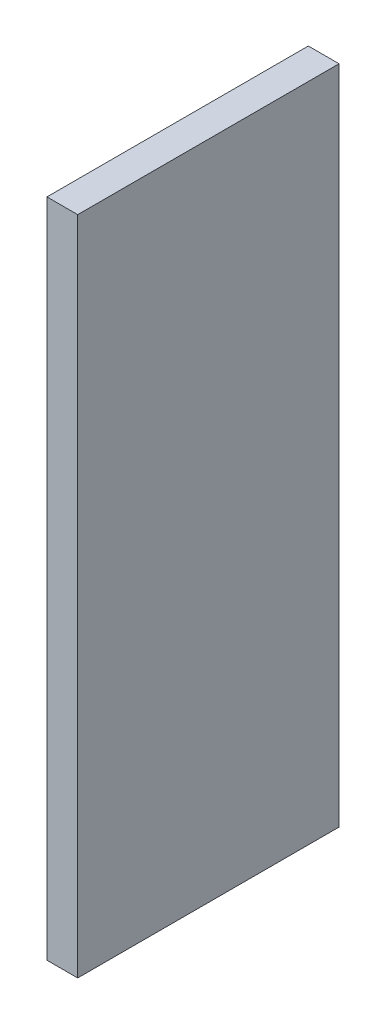
SolidWorks part; units mm, degrees
ref_plane "Ön Düzlem" through (0, 0, 0) normal (1, 0, 0) x (0, 1, 0)
ref_plane "Üst Düzlem" through (0, 0, 0) normal (0, 0, 1) x (0, 1, 0)
ref_plane "Sağ Düzlem" through (0, 0, 0) normal (0, 1, 0) x (-1, 0, 0)
sketch "Sketch1" plane through (0, 0, 0) normal (1, 0, 0) x (0, 1, 0)
  line L1 (-107.5, -42.5) -> (107.5, -42.5)
  line L2 (-107.5, -42.5) -> (-107.5, 42.5)
  line L3 (-107.5, 42.5) -> (107.5, 42.5)
  line L4 (107.5, -42.5) -> (107.5, 42.5)
  line L5 (-107.5, -42.5) -> (107.5, 42.5) construction
  line L6 (-107.5, 42.5) -> (107.5, -42.5) construction
  point P0 (0, 0)
  dimension "D1" = 215
  dimension "D2" = 85
extrude "Boss-Extrude1" add sketch "Sketch1" along normal mid plane 10
sketch "Sketch3" plane through (5, 0, 0) normal (1, 0, 0) x (0, 1, 0)
  line L0 (-107.3562, -41.3805) -> (-107.5, -41.1826)
  line L1 (-107.5, -41.1826) -> (-107.5, -39.4813)
  line L2 (-107.5, -39.4813) -> (-106.3655, -41.0429)
  line L3 (-106.3655, -41.0429) -> (-106.4046, -41.0713)
  line L4 (-106.4046, -41.0713) -> (-106.3562, -41.0713)
  line L5 (-106.3562, -41.0713) -> (-106.3562, -42.5)
  line L6 (-106.3562, -42.5) -> (-107.3562, -42.5)
  line L7 (-107.3562, -42.5) -> (-107.3562, -41.3805)
  line L8 (-105.2767, -10.0452) -> (-102.0353, -5.5838)
  line L9 (-102.0353, -5.5838) -> (-101.6308, -5.8777)
  line L10 (-101.6308, -5.8777) -> (-101.2263, -5.5838)
  line L11 (-101.2263, -5.5838) -> (-97.9849, -10.0452)
  line L12 (-97.9849, -10.0452) -> (-92.7402, -8.3411)
  line L13 (-92.7402, -8.3411) -> (-92.6579, -8.5945)
  line L14 (-92.6579, -8.5945) -> (-92.0857, -8.5945)
  line L15 (-92.0857, -8.5945) -> (-92.0857, -14.3312)
  line L16 (-92.0857, -14.3312) -> (-87.1865, -15.9231)
  line L17 (-87.1865, -15.9231) -> (-84.1587, -11.7556)
  line L18 (-84.1587, -11.7556) -> (-87.4, -7.2942)
  line L19 (-87.4, -7.2942) -> (-87.5306, -7.1145)
  line L20 (-87.5306, -7.1145) -> (-87.0677, -6.7781)
  line L21 (-87.0677, -6.7781) -> (-87.15, -6.5248)
  line L22 (-87.15, -6.5248) -> (-81.9055, -4.8207)
  line L23 (-81.9055, -4.8207) -> (-81.9054, 0.6938)
  line L24 (-81.9054, 0.6938) -> (-81.4054, 0.6938)
  line L25 (-81.4054, 0.6938) -> (-81.2508, 1.1693)
  line L26 (-81.2508, 1.1693) -> (-76.0061, -0.5349)
  line L27 (-76.0061, -0.5349) -> (-72.9783, 3.6327)
  line L28 (-72.9783, 3.6327) -> (-76.0062, 7.8001)
  line L29 (-76.0062, 7.8001) -> (-81.2509, 6.096)
  line L30 (-81.2509, 6.096) -> (-81.3332, 6.3494)
  line L31 (-81.3332, 6.3494) -> (-81.9054, 6.3494)
  line L32 (-81.9054, 6.3494) -> (-81.9054, 6.5715)
  line L33 (-81.9054, 6.5715) -> (-81.9054, 12.0861)
  line L34 (-81.9054, 12.0861) -> (-85.4505, 13.238)
  line L35 (-85.4505, 13.238) -> (-89.341, 11.9738)
  line L36 (-89.341, 11.9738) -> (-89.4955, 12.4494)
  line L37 (-89.4955, 12.4494) -> (-89.9955, 12.4494)
  line L38 (-89.9955, 12.4494) -> (-89.9955, 13.9272)
  line L39 (-89.9955, 13.9272) -> (-89.9955, 17.9639)
  line L40 (-89.9955, 17.9639) -> (-93.2538, 19.0226)
  line L41 (-93.2538, 19.0226) -> (-93.2566, 19.0206)
  line L42 (-93.2566, 19.0206) -> (-93.2595, 19.0245)
  line L43 (-93.2595, 19.0245) -> (-93.2641, 19.026)
  line L44 (-93.2641, 19.026) -> (-93.263, 19.0293)
  line L45 (-93.263, 19.0293) -> (-95.2767, 21.8009)
  line L46 (-95.2767, 21.8009) -> (-100.1759, 20.2091)
  line L47 (-100.1759, 20.2091) -> (-100.1759, 15.0578)
  line L48 (-100.1759, 15.0578) -> (-96.9176, 13.9991)
  line L49 (-96.9176, 13.9991) -> (-96.9148, 14.0012)
  line L50 (-96.9148, 14.0012) -> (-96.9119, 13.9973)
  line L51 (-96.9119, 13.9973) -> (-96.9074, 13.9958)
  line L52 (-96.9074, 13.9958) -> (-96.9084, 13.9924)
  line L53 (-96.9084, 13.9924) -> (-94.6812, 10.9269)
  line L54 (-94.6812, 10.9269) -> (-95.0857, 10.633)
  line L55 (-95.0857, 10.633) -> (-94.9312, 10.1575)
  line L56 (-94.9312, 10.1575) -> (-96.9074, 9.5154)
  line L57 (-96.9074, 9.5154) -> (-100.5214, 8.3411)
  line L58 (-100.5214, 8.3411) -> (-100.6759, 8.8166)
  line L59 (-100.6759, 8.8166) -> (-101.1759, 8.8166)
  line L60 (-101.1759, 8.8166) -> (-101.1759, 10.8945)
  line L61 (-101.1759, 10.8945) -> (-101.1759, 12.6166)
  line L62 (-101.1759, 12.6166) -> (-101.1759, 14.3312)
  line L63 (-101.1759, 14.3312) -> (-106.0751, 15.9231)
  line L64 (-106.0751, 15.9231) -> (-107.5, 13.9618)
  line L65 (-107.5, 13.9618) -> (-107.5, 15.6631)
  line L66 (-107.5, 15.6631) -> (-106.54, 16.9845)
  line L67 (-106.54, 16.9845) -> (-106.3828, 16.8703)
  line L68 (-106.3828, 16.8703) -> (-106.3228, 17.055)
  line L69 (-106.3228, 17.055) -> (-101.1759, 15.3827)
  line L70 (-101.1759, 15.3827) -> (-101.1759, 20.7945)
  line L71 (-101.1759, 20.7945) -> (-100.9816, 20.7945)
  line L72 (-100.9816, 20.7945) -> (-101.0417, 20.9792)
  line L73 (-101.0417, 20.9792) -> (-95.8947, 22.6516)
  line L74 (-95.8947, 22.6516) -> (-98.5406, 26.2933)
  line L75 (-98.5406, 26.2933) -> (-101.7216, 21.9151)
  line L76 (-101.7216, 21.9151) -> (-101.8787, 22.0293)
  line L77 (-101.8787, 22.0293) -> (-101.9388, 21.8445)
  line L78 (-101.9388, 21.8445) -> (-107.0857, 23.5169)
  line L79 (-107.0857, 23.5169) -> (-107.0857, 18.1051)
  line L80 (-107.0857, 18.1051) -> (-107.2799, 18.1051)
  line L81 (-107.2799, 18.1051) -> (-107.2199, 17.9203)
  line L82 (-107.2199, 17.9203) -> (-107.5, 17.8293)
  line L83 (-107.5, 17.8293) -> (-107.5, 29.4269)
  line L84 (-107.5, 29.4269) -> (-105.8947, 31.6364)
  line L85 (-105.8947, 31.6364) -> (-106.6457, 31.8804)
  line L86 (-106.6457, 31.8804) -> (-107.5, 32.158)
  line L87 (-107.5, 32.158) -> (-107.5, 33.2095)
  line L88 (-107.5, 33.2095) -> (-105.2767, 32.4871)
  line L89 (-105.2767, 32.4871) -> (-104.6216, 33.3888)
  line L90 (-104.6216, 33.3888) -> (-102.2488, 36.6546)
  line L91 (-102.2488, 36.6546) -> (-105.2767, 40.8221)
  line L92 (-105.2767, 40.8221) -> (-107.5, 40.0997)
  line L93 (-107.5, 40.0997) -> (-107.5, 41.1511)
  line L94 (-107.5, 41.1511) -> (-105.0289, 41.954)
  line L95 (-105.0289, 41.954) -> (-104.9689, 41.7693)
  line L96 (-104.9689, 41.7693) -> (-104.8118, 41.8835)
  line L97 (-104.8118, 41.8835) -> (-101.6308, 37.5052)
  line L98 (-101.6308, 37.5052) -> (-98.4498, 41.8835)
  line L99 (-98.4498, 41.8835) -> (-98.2927, 41.7693)
  line L100 (-98.2927, 41.7693) -> (-98.2326, 41.954)
  line L101 (-98.2326, 41.954) -> (-93.0857, 40.2817)
  line L102 (-93.0857, 40.2817) -> (-93.0857, 42.5)
  line L103 (-93.0857, 42.5) -> (-92.0857, 42.5)
  line L104 (-92.0857, 42.5) -> (-92.0857, 39.9568)
  line L105 (-92.0857, 39.9568) -> (-88.2466, 38.7093)
  line L106 (-88.2466, 38.7093) -> (-87.1865, 38.3649)
  line L107 (-87.1865, 38.3649) -> (-84.1822, 42.5)
  line L108 (-84.1822, 42.5) -> (-82.899, 42.5)
  line L109 (-82.899, 42.5) -> (-79.8947, 38.3649)
  line L110 (-79.8947, 38.3649) -> (-74.9955, 39.9568)
  line L111 (-74.9955, 39.9568) -> (-74.9955, 42.5)
  line L112 (-74.9955, 42.5) -> (-73.9955, 42.5)
  line L113 (-73.9955, 42.5) -> (-73.9955, 40.2817)
  line L114 (-73.9955, 40.2817) -> (-68.8486, 41.954)
  line L115 (-68.8486, 41.954) -> (-68.7886, 41.7693)
  line L116 (-68.7886, 41.7693) -> (-68.6314, 41.8835)
  line L117 (-68.6314, 41.8835) -> (-65.4505, 37.5052)
  line L118 (-65.4505, 37.5052) -> (-62.2695, 41.8835)
  line L119 (-62.2695, 41.8835) -> (-62.1123, 41.7693)
  line L120 (-62.1123, 41.7693) -> (-62.0523, 41.954)
  line L121 (-62.0523, 41.954) -> (-56.9054, 40.2817)
  line L122 (-56.9054, 40.2817) -> (-56.9054, 42.5)
  line L123 (-56.9054, 42.5) -> (-55.9054, 42.5)
  line L124 (-55.9054, 42.5) -> (-55.9053, 39.9567)
  line L125 (-55.9053, 39.9567) -> (-51.0063, 38.365)
  line L126 (-51.0063, 38.365) -> (-48.0019, 42.5)
  line L127 (-48.0019, 42.5) -> (-46.7189, 42.5)
  line L128 (-46.7189, 42.5) -> (-43.7145, 38.3647)
  line L129 (-43.7145, 38.3647) -> (-38.8153, 39.9565)
  line L130 (-38.8153, 39.9565) -> (-38.8153, 42.5)
  line L131 (-38.8153, 42.5) -> (-37.8153, 42.5)
  line L132 (-37.8153, 42.5) -> (-37.8153, 40.2815)
  line L133 (-37.8153, 40.2815) -> (-32.6684, 41.9538)
  line L134 (-32.6684, 41.9538) -> (-32.6084, 41.7691)
  line L135 (-32.6084, 41.7691) -> (-32.4512, 41.8832)
  line L136 (-32.4512, 41.8832) -> (-29.2703, 37.505)
  line L137 (-29.2703, 37.505) -> (-26.6244, 41.1468)
  line L138 (-26.6244, 41.1468) -> (-30.7892, 42.5)
  line L139 (-30.7892, 42.5) -> (-27.5531, 42.5)
  line L140 (-27.5531, 42.5) -> (-26.0063, 41.9974)
  line L141 (-26.0063, 41.9974) -> (-25.6412, 42.5)
  line L142 (-25.6412, 42.5) -> (-24.4051, 42.5)
  line L143 (-24.4051, 42.5) -> (-25.0063, 41.6725)
  line L144 (-25.0063, 41.6725) -> (-19.8594, 40.0002)
  line L145 (-19.8594, 40.0002) -> (-19.9194, 39.8154)
  line L146 (-19.9194, 39.8154) -> (-19.7252, 39.8154)
  line L147 (-19.7252, 39.8154) -> (-19.7252, 34.4036)
  line L148 (-19.7252, 34.4036) -> (-18.5994, 34.7694)
  line L149 (-18.5994, 34.7694) -> (-15.444, 35.7946)
  line L150 (-15.444, 35.7946) -> (-18.625, 40.1729)
  line L151 (-18.625, 40.1729) -> (-18.4679, 40.2871)
  line L152 (-18.4679, 40.2871) -> (-18.625, 40.4012)
  line L153 (-18.625, 40.4012) -> (-17.1002, 42.5)
  line L154 (-17.1002, 42.5) -> (-15.8641, 42.5)
  line L155 (-15.8641, 42.5) -> (-17.4719, 40.2871)
  line L156 (-17.4719, 40.2871) -> (-14.4441, 36.1197)
  line L157 (-14.4441, 36.1197) -> (-9.545, 37.7114)
  line L158 (-9.545, 37.7114) -> (-9.5449, 42.5)
  line L159 (-9.5449, 42.5) -> (-8.5449, 42.5)
  line L160 (-8.5449, 42.5) -> (-8.5449, 38.0363)
  line L161 (-8.5449, 38.0363) -> (-3.398, 39.7085)
  line L162 (-3.398, 39.7085) -> (-3.338, 39.5239)
  line L163 (-3.338, 39.5239) -> (-3.181, 39.638)
  line L164 (-3.181, 39.638) -> (0, 35.2598)
  line L165 (0, 35.2598) -> (2.6459, 38.9015)
  line L166 (2.6459, 38.9015) -> (-2.501, 40.5739)
  line L167 (-2.501, 40.5739) -> (-2.441, 40.7586)
  line L168 (-2.441, 40.7586) -> (-2.6353, 40.7586)
  line L169 (-2.6353, 40.7586) -> (-2.6353, 42.5)
  line L170 (-2.6353, 42.5) -> (-1.6353, 42.5)
  line L171 (-1.6353, 42.5) -> (-1.6353, 41.344)
  line L172 (-1.6353, 41.344) -> (3.2639, 39.7522)
  line L173 (3.2639, 39.7522) -> (5.2603, 42.5)
  line L174 (5.2603, 42.5) -> (6.4964, 42.5)
  line L175 (6.4964, 42.5) -> (4.2639, 39.4273)
  line L176 (4.2639, 39.4273) -> (7.9701, 38.2231)
  line L177 (7.9701, 38.2231) -> (8.5451, 38.0362)
  line L178 (8.5451, 38.0362) -> (8.5451, 42.5)
  line L179 (8.5451, 42.5) -> (9.5451, 42.5)
  line L180 (9.5451, 42.5) -> (9.5451, 37.7114)
  line L181 (9.5451, 37.7114) -> (14.4442, 36.1195)
  line L182 (14.4442, 36.1195) -> (17.4721, 40.287)
  line L183 (17.4721, 40.287) -> (15.8643, 42.5)
  line L184 (15.8643, 42.5) -> (17.1004, 42.5)
  line L185 (17.1004, 42.5) -> (18.6253, 40.4012)
  line L186 (18.6253, 40.4012) -> (18.4681, 40.287)
  line L187 (18.4681, 40.287) -> (18.6252, 40.1728)
  line L188 (18.6252, 40.1728) -> (15.4442, 35.7946)
  line L189 (15.4442, 35.7946) -> (20.5911, 34.1221)
  line L190 (20.5911, 34.1221) -> (20.5311, 33.9376)
  line L191 (20.5311, 33.9376) -> (20.7252, 33.9376)
  line L192 (20.7252, 33.9376) -> (20.7252, 28.5258)
  line L193 (20.7252, 28.5258) -> (23.8688, 29.5472)
  line L194 (23.8688, 29.5472) -> (25.0063, 29.9168)
  line L195 (25.0063, 29.9168) -> (21.8254, 34.295)
  line L196 (21.8254, 34.295) -> (21.9825, 34.4092)
  line L197 (21.9825, 34.4092) -> (21.8254, 34.5234)
  line L198 (21.8254, 34.5234) -> (25.0063, 38.9016)
  line L199 (25.0063, 38.9016) -> (19.8594, 40.574)
  line L200 (19.8594, 40.574) -> (19.9194, 40.7587)
  line L201 (19.9194, 40.7587) -> (19.7253, 40.7587)
  line L202 (19.7253, 40.7587) -> (19.7253, 42.5)
  line L203 (19.7253, 42.5) -> (20.7253, 42.5)
  line L204 (20.7253, 42.5) -> (20.7253, 41.3441)
  line L205 (20.7253, 41.3441) -> (25.6244, 39.7523)
  line L206 (25.6244, 39.7523) -> (27.6207, 42.5)
  line L207 (27.6207, 42.5) -> (28.8568, 42.5)
  line L208 (28.8568, 42.5) -> (26.6244, 39.4274)
  line L209 (26.6244, 39.4274) -> (30.8804, 38.0445)
  line L210 (30.8804, 38.0445) -> (30.9055, 38.0363)
  line L211 (30.9055, 38.0363) -> (30.9055, 42.5)
  line L212 (30.9055, 42.5) -> (31.9055, 42.5)
  line L213 (31.9055, 42.5) -> (31.9055, 37.7114)
  line L214 (31.9055, 37.7114) -> (36.8047, 36.1196)
  line L215 (36.8047, 36.1196) -> (39.8326, 40.2871)
  line L216 (39.8326, 40.2871) -> (38.2248, 42.5)
  line L217 (38.2248, 42.5) -> (39.4608, 42.5)
  line L218 (39.4608, 42.5) -> (40.4506, 41.1377)
  line L219 (40.4506, 41.1377) -> (41.4404, 42.5)
  line L220 (41.4404, 42.5) -> (42.6764, 42.5)
  line L221 (42.6764, 42.5) -> (41.0686, 40.2871)
  line L222 (41.0686, 40.2871) -> (44.0965, 36.1196)
  line L223 (44.0965, 36.1196) -> (48.9957, 37.7114)
  line L224 (48.9957, 37.7114) -> (48.9957, 42.5)
  line L225 (48.9957, 42.5) -> (49.9957, 42.5)
  line L226 (49.9957, 42.5) -> (49.9957, 37.126)
  line L227 (49.9957, 37.126) -> (49.8014, 37.126)
  line L228 (49.8014, 37.126) -> (49.8615, 36.9413)
  line L229 (49.8615, 36.9413) -> (44.7145, 35.2689)
  line L230 (44.7145, 35.2689) -> (47.8955, 30.8907)
  line L231 (47.8955, 30.8907) -> (47.7384, 30.7765)
  line L232 (47.7384, 30.7765) -> (47.8955, 30.6624)
  line L233 (47.8955, 30.6624) -> (44.7145, 26.2842)
  line L234 (44.7145, 26.2842) -> (48.9955, 24.8933)
  line L235 (48.9955, 24.8933) -> (48.9955, 30.3051)
  line L236 (48.9955, 30.3051) -> (49.1898, 30.3051)
  line L237 (49.1898, 30.3051) -> (49.1298, 30.4898)
  line L238 (49.1298, 30.4898) -> (54.2768, 32.1621)
  line L239 (54.2768, 32.1621) -> (51.0959, 36.5404)
  line L240 (51.0959, 36.5404) -> (51.2529, 36.6544)
  line L241 (51.2529, 36.6544) -> (51.0959, 36.7685)
  line L242 (51.0959, 36.7685) -> (54.2768, 41.1468)
  line L243 (54.2768, 41.1468) -> (50.112, 42.5)
  line L244 (50.112, 42.5) -> (53.3481, 42.5)
  line L245 (53.3481, 42.5) -> (54.8949, 41.9974)
  line L246 (54.8949, 41.9974) -> (55.26, 42.5)
  line L247 (55.26, 42.5) -> (56.4961, 42.5)
  line L248 (56.4961, 42.5) -> (55.8949, 41.6725)
  line L249 (55.8949, 41.6725) -> (58.0353, 40.977)
  line L250 (58.0353, 40.977) -> (60.1759, 40.2816)
  line L251 (60.1759, 40.2816) -> (60.1759, 42.5)
  line L252 (60.1759, 42.5) -> (61.1759, 42.5)
  line L253 (61.1759, 42.5) -> (61.1759, 39.9567)
  line L254 (61.1759, 39.9567) -> (66.0751, 38.365)
  line L255 (66.0751, 38.365) -> (69.0794, 42.5)
  line L256 (69.0794, 42.5) -> (70.3625, 42.5)
  line L257 (70.3625, 42.5) -> (73.3669, 38.3649)
  line L258 (73.3669, 38.3649) -> (76.9119, 39.5168)
  line L259 (76.9119, 39.5168) -> (79.0794, 42.5)
  line L260 (79.0794, 42.5) -> (80.3625, 42.5)
  line L261 (80.3625, 42.5) -> (80.9941, 41.6307)
  line L262 (80.9941, 41.6307) -> (83.3669, 38.3649)
  line L263 (83.3669, 38.3649) -> (86.6251, 39.4236)
  line L264 (86.6251, 39.4236) -> (86.6262, 39.4269)
  line L265 (86.6262, 39.4269) -> (86.6308, 39.4254)
  line L266 (86.6308, 39.4254) -> (86.6354, 39.4269)
  line L267 (86.6354, 39.4269) -> (86.6365, 39.4236)
  line L268 (86.6365, 39.4236) -> (89.8947, 38.3649)
  line L269 (89.8947, 38.3649) -> (92.899, 42.5)
  line L270 (92.899, 42.5) -> (93.9632, 42.5)
  line L271 (93.9632, 42.5) -> (94.0757, 42.4182)
  line L272 (94.0757, 42.4182) -> (90.8947, 38.04)
  line L273 (90.8947, 38.04) -> (93.7449, 37.1139)
  line L274 (93.7449, 37.1139) -> (95.1759, 36.649)
  line L275 (95.1759, 36.649) -> (95.1759, 42.0608)
  line L276 (95.1759, 42.0608) -> (95.3701, 42.0608)
  line L277 (95.3701, 42.0608) -> (95.3101, 42.2455)
  line L278 (95.3101, 42.2455) -> (96.0933, 42.5)
  line L279 (96.0933, 42.5) -> (99.3294, 42.5)
  line L280 (99.3294, 42.5) -> (96.1759, 41.4754)
  line L281 (96.1759, 41.4754) -> (96.1759, 36.324)
  line L282 (96.1759, 36.324) -> (99.721, 35.1722)
  line L283 (99.721, 35.1722) -> (103.266, 36.324)
  line L284 (103.266, 36.324) -> (103.266, 40.0516)
  line L285 (103.266, 40.0516) -> (101.4872, 42.5)
  line L286 (101.4872, 42.5) -> (102.7232, 42.5)
  line L287 (102.7232, 42.5) -> (104.2568, 40.3892)
  line L288 (104.2568, 40.3892) -> (104.2177, 40.3608)
  line L289 (104.2177, 40.3608) -> (104.266, 40.3608)
  line L290 (104.266, 40.3608) -> (104.266, 36.649)
  line L291 (104.266, 36.649) -> (107.5, 37.6997)
  line L292 (107.5, 37.6997) -> (107.5, 36.6483)
  line L293 (107.5, 36.6483) -> (105.3261, 35.9419)
  line L294 (105.3261, 35.9419) -> (104.266, 35.5975)
  line L295 (104.266, 35.5975) -> (104.266, 34.4829)
  line L296 (104.266, 34.4829) -> (104.266, 30.4462)
  line L297 (104.266, 30.4462) -> (107.5, 29.3954)
  line L298 (107.5, 29.3954) -> (107.5, 28.344)
  line L299 (107.5, 28.344) -> (104.266, 29.3947)
  line L300 (104.266, 29.3947) -> (104.266, 23.9829)
  line L301 (104.266, 23.9829) -> (104.0718, 23.9829)
  line L302 (104.0718, 23.9829) -> (104.1318, 23.7982)
  line L303 (104.1318, 23.7982) -> (98.9849, 22.1258)
  line L304 (98.9849, 22.1258) -> (99.1299, 21.9263)
  line L305 (99.1299, 21.9263) -> (101.6308, 18.4841)
  line L306 (101.6308, 18.4841) -> (104.8118, 22.8623)
  line L307 (104.8118, 22.8623) -> (104.9689, 22.7482)
  line L308 (104.9689, 22.7482) -> (105.0289, 22.9329)
  line L309 (105.0289, 22.9329) -> (107.5, 22.13)
  line L310 (107.5, 22.13) -> (107.5, 21.0785)
  line L311 (107.5, 21.0785) -> (105.2767, 21.8009)
  line L312 (105.2767, 21.8009) -> (102.2488, 17.6334)
  line L313 (102.2488, 17.6334) -> (105.2767, 13.4659)
  line L314 (105.2767, 13.4659) -> (107.5, 14.1883)
  line L315 (107.5, 14.1883) -> (107.5, 13.1369)
  line L316 (107.5, 13.1369) -> (105.0289, 12.334)
  line L317 (105.0289, 12.334) -> (104.9689, 12.5187)
  line L318 (104.9689, 12.5187) -> (104.8118, 12.4045)
  line L319 (104.8118, 12.4045) -> (101.6308, 16.7828)
  line L320 (101.6308, 16.7828) -> (98.4498, 12.4045)
  line L321 (98.4498, 12.4045) -> (98.2927, 12.5187)
  line L322 (98.2927, 12.5187) -> (98.2326, 12.334)
  line L323 (98.2326, 12.334) -> (93.0857, 14.0063)
  line L324 (93.0857, 14.0063) -> (93.0857, 9.5048)
  line L325 (93.0857, 9.5048) -> (98.2326, 11.1772)
  line L326 (98.2326, 11.1772) -> (98.2927, 10.9924)
  line L327 (98.2927, 10.9924) -> (98.4498, 11.1066)
  line L328 (98.4498, 11.1066) -> (101.6308, 6.7284)
  line L329 (101.6308, 6.7284) -> (104.8118, 11.1066)
  line L330 (104.8118, 11.1066) -> (104.9689, 10.9924)
  line L331 (104.9689, 10.9924) -> (105.0289, 11.1772)
  line L332 (105.0289, 11.1772) -> (107.5, 10.3743)
  line L333 (107.5, 10.3743) -> (107.5, 9.3228)
  line L334 (107.5, 9.3228) -> (105.2767, 10.0452)
  line L335 (105.2767, 10.0452) -> (102.0353, 5.5838)
  line L336 (102.0353, 5.5838) -> (101.6308, 5.8777)
  line L337 (101.6308, 5.8777) -> (101.2263, 5.5838)
  line L338 (101.2263, 5.5838) -> (97.9849, 10.0452)
  line L339 (97.9849, 10.0452) -> (92.7402, 8.3411)
  line L340 (92.7402, 8.3411) -> (92.6579, 8.5945)
  line L341 (92.6579, 8.5945) -> (92.0857, 8.5945)
  line L342 (92.0857, 8.5945) -> (92.0857, 14.3312)
  line L343 (92.0857, 14.3312) -> (87.1865, 15.9231)
  line L344 (87.1865, 15.9231) -> (84.1587, 11.7556)
  line L345 (84.1587, 11.7556) -> (87.4, 7.2942)
  line L346 (87.4, 7.2942) -> (87.5306, 7.1145)
  line L347 (87.5306, 7.1145) -> (87.0677, 6.7781)
  line L348 (87.0677, 6.7781) -> (87.15, 6.5248)
  line L349 (87.15, 6.5248) -> (81.9055, 4.8207)
  line L350 (81.9055, 4.8207) -> (81.9054, -0.6938)
  line L351 (81.9054, -0.6938) -> (81.4054, -0.6938)
  line L352 (81.4054, -0.6938) -> (81.2508, -1.1693)
  line L353 (81.2508, -1.1693) -> (76.0061, 0.5349)
  line L354 (76.0061, 0.5349) -> (72.9783, -3.6327)
  line L355 (72.9783, -3.6327) -> (76.0062, -7.8001)
  line L356 (76.0062, -7.8001) -> (81.2509, -6.096)
  line L357 (81.2509, -6.096) -> (81.3332, -6.3494)
  line L358 (81.3332, -6.3494) -> (81.9054, -6.3494)
  line L359 (81.9054, -6.3494) -> (81.9054, -6.5715)
  line L360 (81.9054, -6.5715) -> (81.9054, -12.0861)
  line L361 (81.9054, -12.0861) -> (85.4505, -13.238)
  line L362 (85.4505, -13.238) -> (89.341, -11.9738)
  line L363 (89.341, -11.9738) -> (89.4955, -12.4494)
  line L364 (89.4955, -12.4494) -> (89.9955, -12.4494)
  line L365 (89.9955, -12.4494) -> (89.9955, -13.9272)
  line L366 (89.9955, -13.9272) -> (89.9955, -16.8494)
  line L367 (89.9955, -16.8494) -> (89.9955, -17.9639)
  line L368 (89.9955, -17.9639) -> (93.2538, -19.0226)
  line L369 (93.2538, -19.0226) -> (93.2566, -19.0206)
  line L370 (93.2566, -19.0206) -> (93.2595, -19.0245)
  line L371 (93.2595, -19.0245) -> (93.2641, -19.026)
  line L372 (93.2641, -19.026) -> (93.263, -19.0293)
  line L373 (93.263, -19.0293) -> (95.2767, -21.8009)
  line L374 (95.2767, -21.8009) -> (100.1759, -20.2091)
  line L375 (100.1759, -20.2091) -> (100.1759, -15.0578)
  line L376 (100.1759, -15.0578) -> (96.9176, -13.9991)
  line L377 (96.9176, -13.9991) -> (96.9148, -14.0012)
  line L378 (96.9148, -14.0012) -> (96.9119, -13.9973)
  line L379 (96.9119, -13.9973) -> (96.9074, -13.9958)
  line L380 (96.9074, -13.9958) -> (96.9084, -13.9924)
  line L381 (96.9084, -13.9924) -> (94.6812, -10.9269)
  line L382 (94.6812, -10.9269) -> (95.0857, -10.633)
  line L383 (95.0857, -10.633) -> (94.9312, -10.1575)
  line L384 (94.9312, -10.1575) -> (96.9074, -9.5154)
  line L385 (96.9074, -9.5154) -> (100.5214, -8.3411)
  line L386 (100.5214, -8.3411) -> (100.6759, -8.8166)
  line L387 (100.6759, -8.8166) -> (101.1759, -8.8166)
  line L388 (101.1759, -8.8166) -> (101.1759, -10.8945)
  line L389 (101.1759, -10.8945) -> (101.1759, -12.6166)
  line L390 (101.1759, -12.6166) -> (101.1759, -14.3312)
  line L391 (101.1759, -14.3312) -> (106.0751, -15.9231)
  line L392 (106.0751, -15.9231) -> (107.5, -13.9618)
  line L393 (107.5, -13.9618) -> (107.5, -15.6631)
  line L394 (107.5, -15.6631) -> (106.54, -16.9845)
  line L395 (106.54, -16.9845) -> (106.3828, -16.8703)
  line L396 (106.3828, -16.8703) -> (106.3228, -17.055)
  line L397 (106.3228, -17.055) -> (101.1759, -15.3827)
  line L398 (101.1759, -15.3827) -> (101.1759, -20.7945)
  line L399 (101.1759, -20.7945) -> (100.9816, -20.7945)
  line L400 (100.9816, -20.7945) -> (101.0417, -20.9792)
  line L401 (101.0417, -20.9792) -> (95.8947, -22.6516)
  line L402 (95.8947, -22.6516) -> (98.5406, -26.2933)
  line L403 (98.5406, -26.2933) -> (101.7216, -21.9151)
  line L404 (101.7216, -21.9151) -> (101.8787, -22.0293)
  line L405 (101.8787, -22.0293) -> (101.9388, -21.8445)
  line L406 (101.9388, -21.8445) -> (107.0857, -23.5169)
  line L407 (107.0857, -23.5169) -> (107.0857, -18.1051)
  line L408 (107.0857, -18.1051) -> (107.2799, -18.1051)
  line L409 (107.2799, -18.1051) -> (107.2199, -17.9203)
  line L410 (107.2199, -17.9203) -> (107.5, -17.8293)
  line L411 (107.5, -17.8293) -> (107.5, -29.4269)
  line L412 (107.5, -29.4269) -> (105.8947, -31.6364)
  line L413 (105.8947, -31.6364) -> (106.6457, -31.8804)
  line L414 (106.6457, -31.8804) -> (107.5, -32.158)
  line L415 (107.5, -32.158) -> (107.5, -33.2095)
  line L416 (107.5, -33.2095) -> (105.2767, -32.4871)
  line L417 (105.2767, -32.4871) -> (104.6216, -33.3888)
  line L418 (104.6216, -33.3888) -> (102.2488, -36.6546)
  line L419 (102.2488, -36.6546) -> (105.2767, -40.8221)
  line L420 (105.2767, -40.8221) -> (107.5, -40.0997)
  line L421 (107.5, -40.0997) -> (107.5, -41.1511)
  line L422 (107.5, -41.1511) -> (105.0289, -41.954)
  line L423 (105.0289, -41.954) -> (104.9689, -41.7693)
  line L424 (104.9689, -41.7693) -> (104.8118, -41.8835)
  line L425 (104.8118, -41.8835) -> (101.6308, -37.5052)
  line L426 (101.6308, -37.5052) -> (98.4498, -41.8835)
  line L427 (98.4498, -41.8835) -> (98.2927, -41.7693)
  line L428 (98.2927, -41.7693) -> (98.2326, -41.954)
  line L429 (98.2326, -41.954) -> (93.0857, -40.2817)
  line L430 (93.0857, -40.2817) -> (93.0857, -42.5)
  line L431 (93.0857, -42.5) -> (92.0857, -42.5)
  line L432 (92.0857, -42.5) -> (92.0857, -39.9568)
  line L433 (92.0857, -39.9568) -> (91.0257, -39.6123)
  line L434 (91.0257, -39.6123) -> (88.6277, -38.8332)
  line L435 (88.6277, -38.8332) -> (88.2466, -38.7093)
  line L436 (88.2466, -38.7093) -> (87.1865, -38.3649)
  line L437 (87.1865, -38.3649) -> (84.1822, -42.5)
  line L438 (84.1822, -42.5) -> (82.899, -42.5)
  line L439 (82.899, -42.5) -> (79.8947, -38.3649)
  line L440 (79.8947, -38.3649) -> (74.9955, -39.9568)
  line L441 (74.9955, -39.9568) -> (74.9955, -42.5)
  line L442 (74.9955, -42.5) -> (73.9955, -42.5)
  line L443 (73.9955, -42.5) -> (73.9955, -40.2817)
  line L444 (73.9955, -40.2817) -> (68.8486, -41.954)
  line L445 (68.8486, -41.954) -> (68.7886, -41.7693)
  line L446 (68.7886, -41.7693) -> (68.6314, -41.8835)
  line L447 (68.6314, -41.8835) -> (65.4505, -37.5052)
  line L448 (65.4505, -37.5052) -> (62.2695, -41.8835)
  line L449 (62.2695, -41.8835) -> (62.1123, -41.7693)
  line L450 (62.1123, -41.7693) -> (62.0523, -41.954)
  line L451 (62.0523, -41.954) -> (56.9054, -40.2817)
  line L452 (56.9054, -40.2817) -> (56.9054, -42.5)
  line L453 (56.9054, -42.5) -> (55.9054, -42.5)
  line L454 (55.9054, -42.5) -> (55.9053, -39.9567)
  line L455 (55.9053, -39.9567) -> (51.0063, -38.365)
  line L456 (51.0063, -38.365) -> (48.0019, -42.5)
  line L457 (48.0019, -42.5) -> (46.7189, -42.5)
  line L458 (46.7189, -42.5) -> (43.7145, -38.3647)
  line L459 (43.7145, -38.3647) -> (38.8153, -39.9565)
  line L460 (38.8153, -39.9565) -> (38.8153, -42.5)
  line L461 (38.8153, -42.5) -> (37.8153, -42.5)
  line L462 (37.8153, -42.5) -> (37.8153, -40.2815)
  line L463 (37.8153, -40.2815) -> (32.6684, -41.9538)
  line L464 (32.6684, -41.9538) -> (32.6084, -41.7691)
  line L465 (32.6084, -41.7691) -> (32.4512, -41.8832)
  line L466 (32.4512, -41.8832) -> (29.2703, -37.505)
  line L467 (29.2703, -37.505) -> (26.6244, -41.1468)
  line L468 (26.6244, -41.1468) -> (30.7892, -42.5)
  line L469 (30.7892, -42.5) -> (27.5531, -42.5)
  line L470 (27.5531, -42.5) -> (26.0063, -41.9974)
  line L471 (26.0063, -41.9974) -> (25.6412, -42.5)
  line L472 (25.6412, -42.5) -> (24.4051, -42.5)
  line L473 (24.4051, -42.5) -> (25.0063, -41.6725)
  line L474 (25.0063, -41.6725) -> (19.8594, -40.0002)
  line L475 (19.8594, -40.0002) -> (19.9194, -39.8154)
  line L476 (19.9194, -39.8154) -> (19.7252, -39.8154)
  line L477 (19.7252, -39.8154) -> (19.7252, -34.4036)
  line L478 (19.7252, -34.4036) -> (15.444, -35.7946)
  line L479 (15.444, -35.7946) -> (18.625, -40.1729)
  line L480 (18.625, -40.1729) -> (18.4679, -40.2871)
  line L481 (18.4679, -40.2871) -> (18.625, -40.4012)
  line L482 (18.625, -40.4012) -> (17.1002, -42.5)
  line L483 (17.1002, -42.5) -> (15.8641, -42.5)
  line L484 (15.8641, -42.5) -> (17.4719, -40.2871)
  line L485 (17.4719, -40.2871) -> (14.4441, -36.1197)
  line L486 (14.4441, -36.1197) -> (9.545, -37.7114)
  line L487 (9.545, -37.7114) -> (9.5449, -42.5)
  line L488 (9.5449, -42.5) -> (8.5449, -42.5)
  line L489 (8.5449, -42.5) -> (8.5449, -38.0363)
  line L490 (8.5449, -38.0363) -> (3.398, -39.7085)
  line L491 (3.398, -39.7085) -> (3.338, -39.5239)
  line L492 (3.338, -39.5239) -> (3.181, -39.638)
  line L493 (3.181, -39.638) -> (0, -35.2598)
  line L494 (0, -35.2598) -> (-2.6459, -38.9015)
  line L495 (-2.6459, -38.9015) -> (2.501, -40.5739)
  line L496 (2.501, -40.5739) -> (2.441, -40.7586)
  line L497 (2.441, -40.7586) -> (2.6353, -40.7586)
  line L498 (2.6353, -40.7586) -> (2.6353, -42.5)
  line L499 (2.6353, -42.5) -> (1.6353, -42.5)
  line L500 (1.6353, -42.5) -> (1.6353, -41.344)
  line L501 (1.6353, -41.344) -> (-3.2639, -39.7522)
  line L502 (-3.2639, -39.7522) -> (-5.2603, -42.5)
  line L503 (-5.2603, -42.5) -> (-6.4964, -42.5)
  line L504 (-6.4964, -42.5) -> (-4.2639, -39.4273)
  line L505 (-4.2639, -39.4273) -> (-8.5451, -38.0362)
  line L506 (-8.5451, -38.0362) -> (-8.5451, -42.5)
  line L507 (-8.5451, -42.5) -> (-9.5451, -42.5)
  line L508 (-9.5451, -42.5) -> (-9.5451, -37.7114)
  line L509 (-9.5451, -37.7114) -> (-14.4442, -36.1195)
  line L510 (-14.4442, -36.1195) -> (-17.4721, -40.287)
  line L511 (-17.4721, -40.287) -> (-15.8643, -42.5)
  line L512 (-15.8643, -42.5) -> (-17.1004, -42.5)
  line L513 (-17.1004, -42.5) -> (-18.6253, -40.4012)
  line L514 (-18.6253, -40.4012) -> (-18.4681, -40.287)
  line L515 (-18.4681, -40.287) -> (-18.6252, -40.1728)
  line L516 (-18.6252, -40.1728) -> (-15.4442, -35.7946)
  line L517 (-15.4442, -35.7946) -> (-20.5911, -34.1221)
  line L518 (-20.5911, -34.1221) -> (-20.5311, -33.9376)
  line L519 (-20.5311, -33.9376) -> (-20.7252, -33.9376)
  line L520 (-20.7252, -33.9376) -> (-20.7252, -28.5258)
  line L521 (-20.7252, -28.5258) -> (-25.0063, -29.9168)
  line L522 (-25.0063, -29.9168) -> (-21.8254, -34.295)
  line L523 (-21.8254, -34.295) -> (-21.9825, -34.4092)
  line L524 (-21.9825, -34.4092) -> (-21.8254, -34.5234)
  line L525 (-21.8254, -34.5234) -> (-25.0063, -38.9016)
  line L526 (-25.0063, -38.9016) -> (-19.8594, -40.574)
  line L527 (-19.8594, -40.574) -> (-19.9194, -40.7587)
  line L528 (-19.9194, -40.7587) -> (-19.7253, -40.7587)
  line L529 (-19.7253, -40.7587) -> (-19.7253, -42.5)
  line L530 (-19.7253, -42.5) -> (-20.7253, -42.5)
  line L531 (-20.7253, -42.5) -> (-20.7253, -41.3441)
  line L532 (-20.7253, -41.3441) -> (-25.6244, -39.7523)
  line L533 (-25.6244, -39.7523) -> (-27.6207, -42.5)
  line L534 (-27.6207, -42.5) -> (-28.8568, -42.5)
  line L535 (-28.8568, -42.5) -> (-26.6244, -39.4274)
  line L536 (-26.6244, -39.4274) -> (-30.9055, -38.0363)
  line L537 (-30.9055, -38.0363) -> (-30.9055, -42.5)
  line L538 (-30.9055, -42.5) -> (-31.9055, -42.5)
  line L539 (-31.9055, -42.5) -> (-31.9055, -37.7114)
  line L540 (-31.9055, -37.7114) -> (-36.8047, -36.1196)
  line L541 (-36.8047, -36.1196) -> (-39.8326, -40.2871)
  line L542 (-39.8326, -40.2871) -> (-38.2248, -42.5)
  line L543 (-38.2248, -42.5) -> (-39.4608, -42.5)
  line L544 (-39.4608, -42.5) -> (-40.4506, -41.1377)
  line L545 (-40.4506, -41.1377) -> (-41.4404, -42.5)
  line L546 (-41.4404, -42.5) -> (-42.6764, -42.5)
  line L547 (-42.6764, -42.5) -> (-41.0686, -40.2871)
  line L548 (-41.0686, -40.2871) -> (-44.0965, -36.1196)
  line L549 (-44.0965, -36.1196) -> (-48.9957, -37.7114)
  line L550 (-48.9957, -37.7114) -> (-48.9957, -42.5)
  line L551 (-48.9957, -42.5) -> (-49.9957, -42.5)
  line L552 (-49.9957, -42.5) -> (-49.9957, -37.126)
  line L553 (-49.9957, -37.126) -> (-49.8014, -37.126)
  line L554 (-49.8014, -37.126) -> (-49.8615, -36.9413)
  line L555 (-49.8615, -36.9413) -> (-44.7145, -35.2689)
  line L556 (-44.7145, -35.2689) -> (-47.8955, -30.8907)
  line L557 (-47.8955, -30.8907) -> (-47.7384, -30.7765)
  line L558 (-47.7384, -30.7765) -> (-47.8955, -30.6624)
  line L559 (-47.8955, -30.6624) -> (-44.7145, -26.2842)
  line L560 (-44.7145, -26.2842) -> (-48.9955, -24.8933)
  line L561 (-48.9955, -24.8933) -> (-48.9955, -30.3051)
  line L562 (-48.9955, -30.3051) -> (-49.1898, -30.3051)
  line L563 (-49.1898, -30.3051) -> (-49.1298, -30.4898)
  line L564 (-49.1298, -30.4898) -> (-54.2768, -32.1621)
  line L565 (-54.2768, -32.1621) -> (-51.0959, -36.5404)
  line L566 (-51.0959, -36.5404) -> (-51.2529, -36.6544)
  line L567 (-51.2529, -36.6544) -> (-51.0959, -36.7685)
  line L568 (-51.0959, -36.7685) -> (-54.2768, -41.1468)
  line L569 (-54.2768, -41.1468) -> (-50.919, -42.2378)
  line L570 (-50.919, -42.2378) -> (-50.112, -42.5)
  line L571 (-50.112, -42.5) -> (-53.3481, -42.5)
  line L572 (-53.3481, -42.5) -> (-54.8949, -41.9974)
  line L573 (-54.8949, -41.9974) -> (-55.26, -42.5)
  line L574 (-55.26, -42.5) -> (-56.4961, -42.5)
  line L575 (-56.4961, -42.5) -> (-55.8949, -41.6725)
  line L576 (-55.8949, -41.6725) -> (-58.0353, -40.977)
  line L577 (-58.0353, -40.977) -> (-60.1759, -40.2816)
  line L578 (-60.1759, -40.2816) -> (-60.1759, -42.5)
  line L579 (-60.1759, -42.5) -> (-61.1759, -42.5)
  line L580 (-61.1759, -42.5) -> (-61.1759, -39.9567)
  line L581 (-61.1759, -39.9567) -> (-66.0751, -38.365)
  line L582 (-66.0751, -38.365) -> (-69.0794, -42.5)
  line L583 (-69.0794, -42.5) -> (-70.3625, -42.5)
  line L584 (-70.3625, -42.5) -> (-73.3669, -38.3649)
  line L585 (-73.3669, -38.3649) -> (-76.9119, -39.5168)
  line L586 (-76.9119, -39.5168) -> (-79.0794, -42.5)
  line L587 (-79.0794, -42.5) -> (-80.3625, -42.5)
  line L588 (-80.3625, -42.5) -> (-80.9941, -41.6307)
  line L589 (-80.9941, -41.6307) -> (-82.3094, -39.8204)
  line L590 (-82.3094, -39.8204) -> (-82.7117, -39.2666)
  line L591 (-82.7117, -39.2666) -> (-83.3669, -38.3649)
  line L592 (-83.3669, -38.3649) -> (-86.6251, -39.4236)
  line L593 (-86.6251, -39.4236) -> (-86.6262, -39.4269)
  line L594 (-86.6262, -39.4269) -> (-86.6308, -39.4254)
  line L595 (-86.6308, -39.4254) -> (-86.6354, -39.4269)
  line L596 (-86.6354, -39.4269) -> (-86.6365, -39.4236)
  line L597 (-86.6365, -39.4236) -> (-89.8947, -38.3649)
  line L598 (-89.8947, -38.3649) -> (-92.899, -42.5)
  line L599 (-92.899, -42.5) -> (-93.9632, -42.5)
  line L600 (-93.9632, -42.5) -> (-94.0757, -42.4182)
  line L601 (-94.0757, -42.4182) -> (-90.8947, -38.04)
  line L602 (-90.8947, -38.04) -> (-95.1759, -36.649)
  line L603 (-95.1759, -36.649) -> (-95.1759, -42.0608)
  line L604 (-95.1759, -42.0608) -> (-95.3701, -42.0608)
  line L605 (-95.3701, -42.0608) -> (-95.3101, -42.2455)
  line L606 (-95.3101, -42.2455) -> (-96.0933, -42.5)
  line L607 (-96.0933, -42.5) -> (-99.3294, -42.5)
  line L608 (-99.3294, -42.5) -> (-96.1759, -41.4754)
  line L609 (-96.1759, -41.4754) -> (-96.1759, -36.324)
  line L610 (-96.1759, -36.324) -> (-99.721, -35.1722)
  line L611 (-99.721, -35.1722) -> (-103.266, -36.324)
  line L612 (-103.266, -36.324) -> (-103.266, -40.0516)
  line L613 (-103.266, -40.0516) -> (-101.4872, -42.5)
  line L614 (-101.4872, -42.5) -> (-102.7232, -42.5)
  line L615 (-102.7232, -42.5) -> (-104.2568, -40.3892)
  line L616 (-104.2568, -40.3892) -> (-104.2177, -40.3608)
  line L617 (-104.2177, -40.3608) -> (-104.266, -40.3608)
  line L618 (-104.266, -40.3608) -> (-104.266, -36.649)
  line L619 (-104.266, -36.649) -> (-105.0171, -36.893)
  line L620 (-105.0171, -36.893) -> (-107.5, -37.6997)
  line L621 (-107.5, -37.6997) -> (-107.5, -36.6483)
  line L622 (-107.5, -36.6483) -> (-104.266, -35.5975)
  line L623 (-104.266, -35.5975) -> (-104.266, -34.4829)
  line L624 (-104.266, -34.4829) -> (-104.266, -31.5608)
  line L625 (-104.266, -31.5608) -> (-104.266, -30.4462)
  line L626 (-104.266, -30.4462) -> (-107.5, -29.3954)
  line L627 (-107.5, -29.3954) -> (-107.5, -28.344)
  line L628 (-107.5, -28.344) -> (-104.266, -29.3947)
  line L629 (-104.266, -29.3947) -> (-104.266, -23.9829)
  line L630 (-104.266, -23.9829) -> (-104.0718, -23.9829)
  line L631 (-104.0718, -23.9829) -> (-104.1318, -23.7982)
  line L632 (-104.1318, -23.7982) -> (-98.9849, -22.1258)
  line L633 (-98.9849, -22.1258) -> (-101.6308, -18.4841)
  line L634 (-101.6308, -18.4841) -> (-104.8118, -22.8623)
  line L635 (-104.8118, -22.8623) -> (-104.9689, -22.7482)
  line L636 (-104.9689, -22.7482) -> (-105.0289, -22.9329)
  line L637 (-105.0289, -22.9329) -> (-107.5, -22.13)
  line L638 (-107.5, -22.13) -> (-107.5, -21.0785)
  line L639 (-107.5, -21.0785) -> (-105.2767, -21.8009)
  line L640 (-105.2767, -21.8009) -> (-102.2488, -17.6334)
  line L641 (-102.2488, -17.6334) -> (-105.2767, -13.4659)
  line L642 (-105.2767, -13.4659) -> (-107.5, -14.1883)
  line L643 (-107.5, -14.1883) -> (-107.5, -13.1369)
  line L644 (-107.5, -13.1369) -> (-105.0289, -12.334)
  line L645 (-105.0289, -12.334) -> (-104.9689, -12.5187)
  line L646 (-104.9689, -12.5187) -> (-104.8118, -12.4045)
  line L647 (-104.8118, -12.4045) -> (-101.6308, -16.7828)
  line L648 (-101.6308, -16.7828) -> (-98.4498, -12.4045)
  line L649 (-98.4498, -12.4045) -> (-98.2927, -12.5187)
  line L650 (-98.2927, -12.5187) -> (-98.2326, -12.334)
  line L651 (-98.2326, -12.334) -> (-93.0857, -14.0063)
  line L652 (-93.0857, -14.0063) -> (-93.0857, -9.5048)
  line L653 (-93.0857, -9.5048) -> (-98.2326, -11.1772)
  line L654 (-98.2326, -11.1772) -> (-98.2927, -10.9924)
  line L655 (-98.2927, -10.9924) -> (-98.4498, -11.1066)
  line L656 (-98.4498, -11.1066) -> (-101.6308, -6.7284)
  line L657 (-101.6308, -6.7284) -> (-104.8118, -11.1066)
  line L658 (-104.8118, -11.1066) -> (-104.9689, -10.9924)
  line L659 (-104.9689, -10.9924) -> (-105.0289, -11.1772)
  line L660 (-105.0289, -11.1772) -> (-107.5, -10.3743)
  line L661 (-107.5, -10.3743) -> (-107.5, -9.3228)
  line L662 (-107.5, -9.3228) -> (-105.2767, -10.0452)
  line L663 (-1.8291, 31.041) -> (-2.6459, 29.9167)
  line L664 (-2.6459, 29.9167) -> (0, 29.057)
  line L665 (0, 29.057) -> (2.6459, 29.9167)
  line L666 (2.6459, 29.9167) -> (1.8291, 31.041)
  line L667 (1.8291, 31.041) -> (0, 33.5585)
  line L668 (0, 33.5585) -> (-1.8291, 31.041)
  line L669 (0, 28.0055) -> (-0.0046, 28.0041)
  line L670 (-0.0046, 28.0041) -> (-0.0057, 28.0074)
  line L671 (-0.0057, 28.0074) -> (-3.2639, 29.0661)
  line L672 (-3.2639, 29.0661) -> (-6.2916, 24.8989)
  line L673 (-6.2916, 24.8989) -> (-3.2639, 20.7315)
  line L674 (-3.2639, 20.7315) -> (-0.0057, 21.79)
  line L675 (-0.0057, 21.79) -> (-0.0046, 21.7934)
  line L676 (-0.0046, 21.7934) -> (0, 21.7919)
  line L677 (0, 21.7919) -> (0.0046, 21.7934)
  line L678 (0.0046, 21.7934) -> (0.0057, 21.79)
  line L679 (0.0057, 21.79) -> (3.2639, 20.7315)
  line L680 (3.2639, 20.7315) -> (6.2916, 24.8989)
  line L681 (6.2916, 24.8989) -> (3.2639, 29.0661)
  line L682 (3.2639, 29.0661) -> (0.0057, 28.0074)
  line L683 (0.0057, 28.0074) -> (0.0046, 28.0041)
  line L684 (0.0046, 28.0041) -> (0, 28.0055)
  line L685 (-1.8293, 18.7568) -> (-1.8291, 18.757)
  line L686 (-1.8291, 18.757) -> (0, 16.2395)
  line L687 (0, 16.2395) -> (1.8291, 18.757)
  line L688 (1.8291, 18.757) -> (1.8293, 18.7568)
  line L689 (1.8293, 18.7568) -> (2.6459, 19.8808)
  line L690 (2.6459, 19.8808) -> (0, 20.7404)
  line L691 (0, 20.7404) -> (-2.6459, 19.8808)
  line L692 (-2.6459, 19.8808) -> (-1.8293, 18.7568)
  line L693 (0, 10.0367) -> (2.6459, 10.8964)
  line L694 (2.6459, 10.8964) -> (0, 14.5382)
  line L695 (0, 14.5382) -> (-2.6459, 10.8964)
  line L696 (-2.6459, 10.8964) -> (0, 10.0367)
  line L697 (-3.2639, 10.0458) -> (-5.2382, 7.3284)
  line L698 (-5.2382, 7.3284) -> (-5.4201, 7.4605)
  line L699 (-5.4201, 7.4605) -> (-5.3506, 7.2467)
  line L700 (-5.3506, 7.2467) -> (-8.5451, 6.2088)
  line L701 (-8.5451, 6.2088) -> (-8.5451, 2.8499)
  line L702 (-8.5451, 2.8499) -> (-8.7698, 2.8499)
  line L703 (-8.7698, 2.8499) -> (-8.588, 2.7178)
  line L704 (-8.588, 2.7178) -> (-10.5623, 0.0004)
  line L705 (-10.5623, 0.0004) -> (-8.588, -2.717)
  line L706 (-8.588, -2.717) -> (-8.7698, -2.8491)
  line L707 (-8.7698, -2.8491) -> (-8.5451, -2.8491)
  line L708 (-8.5451, -2.8491) -> (-8.5451, -6.2079)
  line L709 (-8.5451, -6.2079) -> (-5.3506, -7.2459)
  line L710 (-5.3506, -7.2459) -> (-5.4201, -7.4596)
  line L711 (-5.4201, -7.4596) -> (-5.2382, -7.3275)
  line L712 (-5.2382, -7.3275) -> (-3.2639, -10.0449)
  line L713 (-3.2639, -10.0449) -> (-0.0695, -9.007)
  line L714 (-0.0695, -9.007) -> (0, -9.2207)
  line L715 (0, -9.2207) -> (0.0695, -9.007)
  line L716 (0.0695, -9.007) -> (3.2639, -10.0449)
  line L717 (3.2639, -10.0449) -> (5.2382, -7.3275)
  line L718 (5.2382, -7.3275) -> (5.4201, -7.4596)
  line L719 (5.4201, -7.4596) -> (5.3506, -7.2459)
  line L720 (5.3506, -7.2459) -> (8.5451, -6.2079)
  line L721 (8.5451, -6.2079) -> (8.5451, -2.8491)
  line L722 (8.5451, -2.8491) -> (8.7698, -2.8491)
  line L723 (8.7698, -2.8491) -> (8.588, -2.717)
  line L724 (8.588, -2.717) -> (10.5623, 0.0004)
  line L725 (10.5623, 0.0004) -> (8.588, 2.7178)
  line L726 (8.588, 2.7178) -> (8.7698, 2.8499)
  line L727 (8.7698, 2.8499) -> (8.5451, 2.8499)
  line L728 (8.5451, 2.8499) -> (8.5451, 6.2088)
  line L729 (8.5451, 6.2088) -> (5.3506, 7.2467)
  line L730 (5.3506, 7.2467) -> (5.4201, 7.4605)
  line L731 (5.4201, 7.4605) -> (5.2382, 7.3284)
  line L732 (5.2382, 7.3284) -> (3.2639, 10.0458)
  line L733 (3.2639, 10.0458) -> (0.0695, 9.0078)
  line L734 (0.0695, 9.0078) -> (0, 9.2216)
  line L735 (0, 9.2216) -> (-0.0695, 9.0078)
  line L736 (-0.0695, 9.0078) -> (-3.2639, 10.0458)
  line L737 (0, -14.5373) -> (2.6459, -10.8956)
  line L738 (2.6459, -10.8956) -> (0, -10.0359)
  line L739 (0, -10.0359) -> (-2.6459, -10.8956)
  line L740 (-2.6459, -10.8956) -> (0, -14.5373)
  line L741 (-0.8168, -17.3629) -> (-2.6459, -19.8804)
  line L742 (-2.6459, -19.8804) -> (0, -20.7401)
  line L743 (0, -20.7401) -> (2.6459, -19.8804)
  line L744 (2.6459, -19.8804) -> (1.8291, -18.7562)
  line L745 (1.8291, -18.7562) -> (0, -16.2387)
  line L746 (0, -16.2387) -> (-0.8168, -17.3629)
  line L747 (0, -21.7916) -> (-0.0046, -21.7931)
  line L748 (-0.0046, -21.7931) -> (-0.0057, -21.7897)
  line L749 (-0.0057, -21.7897) -> (-3.2639, -20.7311)
  line L750 (-3.2639, -20.7311) -> (-6.2918, -24.8986)
  line L751 (-6.2918, -24.8986) -> (-3.2639, -29.0661)
  line L752 (-3.2639, -29.0661) -> (-0.0057, -28.0074)
  line L753 (-0.0057, -28.0074) -> (-0.0046, -28.0041)
  line L754 (-0.0046, -28.0041) -> (0, -28.0055)
  line L755 (0, -28.0055) -> (0.0046, -28.0041)
  line L756 (0.0046, -28.0041) -> (0.0057, -28.0074)
  line L757 (0.0057, -28.0074) -> (3.2639, -29.0661)
  line L758 (3.2639, -29.0661) -> (6.2918, -24.8986)
  line L759 (6.2918, -24.8986) -> (3.2639, -20.7311)
  line L760 (3.2639, -20.7311) -> (0.0057, -21.7897)
  line L761 (0.0057, -21.7897) -> (0.0046, -21.7931)
  line L762 (0.0046, -21.7931) -> (0, -21.7916)
  line L763 (-1.8291, -31.041) -> (0, -33.5585)
  line L764 (0, -33.5585) -> (1.7858, -31.1006)
  line L765 (1.7858, -31.1006) -> (2.6459, -29.9167)
  line L766 (2.6459, -29.9167) -> (0, -29.057)
  line L767 (0, -29.057) -> (-2.6459, -29.9167)
  line L768 (-2.6459, -29.9167) -> (-1.8291, -31.041)
  line L769 (-50.7584, 37.233) -> (-55.9054, 38.9053)
  line L770 (-55.9054, 38.9053) -> (-55.9054, 34.4038)
  line L771 (-55.9054, 34.4038) -> (-50.7584, 36.0762)
  line L772 (-50.7584, 36.0762) -> (-50.6984, 35.8914)
  line L773 (-50.6984, 35.8914) -> (-50.5413, 36.0056)
  line L774 (-50.5413, 36.0056) -> (-47.3603, 31.6274)
  line L775 (-47.3603, 31.6274) -> (-44.1793, 36.0056)
  line L776 (-44.1793, 36.0056) -> (-44.0222, 35.8915)
  line L777 (-44.0222, 35.8915) -> (-43.9622, 36.0761)
  line L778 (-43.9622, 36.0761) -> (-38.8153, 34.4037)
  line L779 (-38.8153, 34.4037) -> (-38.8153, 38.9051)
  line L780 (-38.8153, 38.9051) -> (-43.9623, 37.2327)
  line L781 (-43.9623, 37.2327) -> (-44.0223, 37.4175)
  line L782 (-44.0223, 37.4175) -> (-44.1795, 37.3033)
  line L783 (-44.1795, 37.3033) -> (-47.3604, 41.6817)
  line L784 (-47.3604, 41.6817) -> (-50.5414, 37.3035)
  line L785 (-50.5414, 37.3035) -> (-50.6985, 37.4176)
  line L786 (-50.6985, 37.4176) -> (-50.7584, 37.233)
  line L787 (-51.0062, 26.6092) -> (-47.9783, 30.7767)
  line L788 (-47.9783, 30.7767) -> (-51.0062, 34.9442)
  line L789 (-51.0062, 34.9442) -> (-55.9054, 33.3524)
  line L790 (-55.9054, 33.3524) -> (-55.9054, 28.2011)
  line L791 (-55.9054, 28.2011) -> (-51.0062, 26.6092)
  line L792 (-45.725, 18.6905) -> (-45.725, 23.8418)
  line L793 (-45.725, 23.8418) -> (-50.6242, 25.4336)
  line L794 (-50.6242, 25.4336) -> (-53.6521, 21.2661)
  line L795 (-53.6521, 21.2661) -> (-50.6242, 17.0986)
  line L796 (-50.6242, 17.0986) -> (-45.725, 18.6905)
  line L797 (-57.4511, 16.0372) -> (-57.6082, 16.1514)
  line L798 (-57.6082, 16.1514) -> (-57.6683, 15.9667)
  line L799 (-57.6683, 15.9667) -> (-62.8152, 17.639)
  line L800 (-62.8152, 17.639) -> (-62.8152, 13.1376)
  line L801 (-62.8152, 13.1376) -> (-57.6683, 14.8099)
  line L802 (-57.6683, 14.8099) -> (-57.6082, 14.6252)
  line L803 (-57.6082, 14.6252) -> (-57.4511, 14.7393)
  line L804 (-57.4511, 14.7393) -> (-54.2701, 10.3611)
  line L805 (-54.2701, 10.3611) -> (-51.0891, 14.7393)
  line L806 (-51.0891, 14.7393) -> (-50.932, 14.6252)
  line L807 (-50.932, 14.6252) -> (-50.872, 14.8099)
  line L808 (-50.872, 14.8099) -> (-45.725, 13.1376)
  line L809 (-45.725, 13.1376) -> (-45.725, 17.639)
  line L810 (-45.725, 17.639) -> (-50.872, 15.9667)
  line L811 (-50.872, 15.9667) -> (-50.932, 16.1514)
  line L812 (-50.932, 16.1514) -> (-51.0891, 16.0372)
  line L813 (-51.0891, 16.0372) -> (-54.2701, 20.4155)
  line L814 (-54.2701, 20.4155) -> (-57.4511, 16.0372)
  line L815 (-45.725, 6.9349) -> (-45.725, 12.0861)
  line L816 (-45.725, 12.0861) -> (-50.6242, 13.6779)
  line L817 (-50.6242, 13.6779) -> (-53.652, 9.5105)
  line L818 (-53.652, 9.5105) -> (-50.6242, 5.3431)
  line L819 (-50.6242, 5.3431) -> (-45.725, 6.9349)
  line L820 (-51.0062, -4.1674) -> (-47.9784, 0)
  line L821 (-47.9784, 0) -> (-51.0062, 4.1675)
  line L822 (-51.0062, 4.1675) -> (-55.9054, 2.5757)
  line L823 (-55.9054, 2.5757) -> (-55.9054, -2.5755)
  line L824 (-55.9054, -2.5755) -> (-51.0062, -4.1674)
  line L825 (-55.9054, -8.1285) -> (-50.7584, -6.4561)
  line L826 (-50.7584, -6.4561) -> (-50.6984, -6.6409)
  line L827 (-50.6984, -6.6409) -> (-50.5413, -6.5267)
  line L828 (-50.5413, -6.5267) -> (-47.3603, -10.9049)
  line L829 (-47.3603, -10.9049) -> (-44.1793, -6.5267)
  line L830 (-44.1793, -6.5267) -> (-44.0222, -6.6409)
  line L831 (-44.0222, -6.6409) -> (-43.9621, -6.4561)
  line L832 (-43.9621, -6.4561) -> (-38.8152, -8.1285)
  line L833 (-38.8152, -8.1285) -> (-38.8152, -3.627)
  line L834 (-38.8152, -3.627) -> (-43.9621, -5.2993)
  line L835 (-43.9621, -5.2993) -> (-44.0222, -5.1146)
  line L836 (-44.0222, -5.1146) -> (-44.1793, -5.2288)
  line L837 (-44.1793, -5.2288) -> (-47.3603, -0.8505)
  line L838 (-47.3603, -0.8505) -> (-50.5413, -5.2288)
  line L839 (-50.5413, -5.2288) -> (-50.6984, -5.1146)
  line L840 (-50.6984, -5.1146) -> (-50.7584, -5.2993)
  line L841 (-50.7584, -5.2993) -> (-55.9054, -3.627)
  line L842 (-55.9054, -3.627) -> (-55.9054, -8.1285)
  line L843 (-51.0062, -15.9231) -> (-47.9783, -11.7556)
  line L844 (-47.9783, -11.7556) -> (-51.0062, -7.5881)
  line L845 (-51.0062, -7.5881) -> (-55.9054, -9.1799)
  line L846 (-55.9054, -9.1799) -> (-55.9054, -14.3312)
  line L847 (-55.9054, -14.3312) -> (-51.0062, -15.9231)
  line L848 (-55.9054, -20.7945) -> (-56.0996, -20.7945)
  line L849 (-56.0996, -20.7945) -> (-56.0396, -20.9792)
  line L850 (-56.0396, -20.9792) -> (-61.1865, -22.6516)
  line L851 (-61.1865, -22.6516) -> (-58.5406, -26.2933)
  line L852 (-58.5406, -26.2933) -> (-55.3596, -21.9151)
  line L853 (-55.3596, -21.9151) -> (-55.2025, -22.0293)
  line L854 (-55.2025, -22.0293) -> (-55.1425, -21.8445)
  line L855 (-55.1425, -21.8445) -> (-49.9955, -23.5169)
  line L856 (-49.9955, -23.5169) -> (-49.9955, -18.1051)
  line L857 (-49.9955, -18.1051) -> (-49.8013, -18.1051)
  line L858 (-49.8013, -18.1051) -> (-49.8613, -17.9203)
  line L859 (-49.8613, -17.9203) -> (-44.7144, -16.248)
  line L860 (-44.7144, -16.248) -> (-47.3603, -12.6062)
  line L861 (-47.3603, -12.6062) -> (-50.5413, -16.9845)
  line L862 (-50.5413, -16.9845) -> (-50.6984, -16.8703)
  line L863 (-50.6984, -16.8703) -> (-50.7584, -17.055)
  line L864 (-50.7584, -17.055) -> (-55.9054, -15.3827)
  line L865 (-55.9054, -15.3827) -> (-55.9054, -20.7945)
  line L866 (-41.0685, -21.2661) -> (-44.0964, -17.0986)
  line L867 (-44.0964, -17.0986) -> (-48.9955, -18.6905)
  line L868 (-48.9955, -18.6905) -> (-48.9955, -23.8417)
  line L869 (-48.9955, -23.8417) -> (-44.0964, -25.4335)
  line L870 (-44.0964, -25.4335) -> (-41.0685, -21.2661)
  line L871 (-81.0996, -5.4062) -> (-81.0396, -5.5908)
  line L872 (-81.0396, -5.5908) -> (-86.1865, -7.2632)
  line L873 (-86.1865, -7.2632) -> (-83.5406, -10.9049)
  line L874 (-83.5406, -10.9049) -> (-80.3596, -6.5267)
  line L875 (-80.3596, -6.5267) -> (-80.2025, -6.6409)
  line L876 (-80.2025, -6.6409) -> (-80.1425, -6.4561)
  line L877 (-80.1425, -6.4561) -> (-74.9955, -8.1285)
  line L878 (-74.9955, -8.1285) -> (-74.9955, -2.7166)
  line L879 (-74.9955, -2.7166) -> (-74.8013, -2.7166)
  line L880 (-74.8013, -2.7166) -> (-74.8613, -2.5319)
  line L881 (-74.8613, -2.5319) -> (-69.7144, -0.8596)
  line L882 (-69.7144, -0.8596) -> (-71.0373, 0.9612)
  line L883 (-71.0373, 0.9612) -> (-72.3603, 2.7821)
  line L884 (-72.3603, 2.7821) -> (-75.5411, -1.5963)
  line L885 (-75.5411, -1.5963) -> (-75.6984, -1.482)
  line L886 (-75.6984, -1.482) -> (-75.7585, -1.6669)
  line L887 (-75.7585, -1.6669) -> (-80.9054, 0.0056)
  line L888 (-80.9054, 0.0056) -> (-80.9055, -5.4062)
  line L889 (-80.9055, -5.4062) -> (-81.0996, -5.4062)
  line L890 (-74.9955, -14.3312) -> (-74.9955, -9.1799)
  line L891 (-74.9955, -9.1799) -> (-79.8947, -7.5881)
  line L892 (-79.8947, -7.5881) -> (-82.9226, -11.7556)
  line L893 (-82.9226, -11.7556) -> (-79.8947, -15.9231)
  line L894 (-79.8947, -15.9231) -> (-74.9955, -14.3312)
  line L895 (-83.5406, -12.6062) -> (-86.7216, -16.9845)
  line L896 (-86.7216, -16.9845) -> (-86.8787, -16.8703)
  line L897 (-86.8787, -16.8703) -> (-86.9388, -17.055)
  line L898 (-86.9388, -17.055) -> (-92.0857, -15.3827)
  line L899 (-92.0857, -15.3827) -> (-92.0857, -19.8842)
  line L900 (-92.0857, -19.8842) -> (-86.9388, -18.2118)
  line L901 (-86.9388, -18.2118) -> (-86.8787, -18.3966)
  line L902 (-86.8787, -18.3966) -> (-86.7216, -18.2824)
  line L903 (-86.7216, -18.2824) -> (-83.5406, -22.6606)
  line L904 (-83.5406, -22.6606) -> (-80.3596, -18.2824)
  line L905 (-80.3596, -18.2824) -> (-80.2025, -18.3966)
  line L906 (-80.2025, -18.3966) -> (-80.1425, -18.2118)
  line L907 (-80.1425, -18.2118) -> (-74.9955, -19.8842)
  line L908 (-74.9955, -19.8842) -> (-74.9955, -15.3827)
  line L909 (-74.9955, -15.3827) -> (-80.1425, -17.055)
  line L910 (-80.1425, -17.055) -> (-80.2025, -16.8703)
  line L911 (-80.2025, -16.8703) -> (-80.3596, -16.9845)
  line L912 (-80.3596, -16.9845) -> (-83.5406, -12.6062)
  line L913 (-80.5499, -26.7771) -> (-79.8947, -27.6788)
  line L914 (-79.8947, -27.6788) -> (-74.9955, -26.0869)
  line L915 (-74.9955, -26.0869) -> (-74.9955, -20.9356)
  line L916 (-74.9955, -20.9356) -> (-79.8947, -19.3438)
  line L917 (-79.8947, -19.3438) -> (-82.9226, -23.5113)
  line L918 (-82.9226, -23.5113) -> (-80.5499, -26.7771)
  line L919 (-73.4498, -27.7929) -> (-73.2927, -27.9071)
  line L920 (-73.2927, -27.9071) -> (-73.2326, -27.7224)
  line L921 (-73.2326, -27.7224) -> (-68.0857, -29.3947)
  line L922 (-68.0857, -29.3947) -> (-68.0857, -23.9829)
  line L923 (-68.0857, -23.9829) -> (-67.8915, -23.9829)
  line L924 (-67.8915, -23.9829) -> (-67.9515, -23.7982)
  line L925 (-67.9515, -23.7982) -> (-62.8046, -22.1258)
  line L926 (-62.8046, -22.1258) -> (-65.4505, -18.4841)
  line L927 (-65.4505, -18.4841) -> (-68.6314, -22.8623)
  line L928 (-68.6314, -22.8623) -> (-68.7886, -22.7482)
  line L929 (-68.7886, -22.7482) -> (-68.8486, -22.9329)
  line L930 (-68.8486, -22.9329) -> (-73.9955, -21.2605)
  line L931 (-73.9955, -21.2605) -> (-73.9955, -26.6724)
  line L932 (-73.9955, -26.6724) -> (-74.1898, -26.6724)
  line L933 (-74.1898, -26.6724) -> (-74.1298, -26.8571)
  line L934 (-74.1298, -26.8571) -> (-79.2767, -28.5294)
  line L935 (-79.2767, -28.5294) -> (-76.6308, -32.1712)
  line L936 (-76.6308, -32.1712) -> (-73.4498, -27.7929)
  line L937 (-72.9849, -37.1893) -> (-68.0857, -35.5975)
  line L938 (-68.0857, -35.5975) -> (-68.0857, -30.4462)
  line L939 (-68.0857, -30.4462) -> (-72.9849, -28.8543)
  line L940 (-72.9849, -28.8543) -> (-76.0128, -33.0218)
  line L941 (-76.0128, -33.0218) -> (-73.64, -36.2876)
  line L942 (-73.64, -36.2876) -> (-72.9849, -37.1893)
  line L943 (-78.8367, -36.893) -> (-82.3669, -38.04)
  line L944 (-82.3669, -38.04) -> (-80.9393, -40.0049)
  line L945 (-80.9393, -40.0049) -> (-79.721, -41.6818)
  line L946 (-79.721, -41.6818) -> (-77.5392, -38.6788)
  line L947 (-77.5392, -38.6788) -> (-77.5001, -38.7073)
  line L948 (-77.5001, -38.7073) -> (-77.515, -38.6613)
  line L949 (-77.515, -38.6613) -> (-73.9849, -37.5143)
  line L950 (-73.9849, -37.5143) -> (-76.1666, -34.5113)
  line L951 (-76.1666, -34.5113) -> (-76.6308, -33.8725)
  line L952 (-76.6308, -33.8725) -> (-78.8125, -36.8754)
  line L953 (-78.8125, -36.8754) -> (-78.8517, -36.847)
  line L954 (-78.8517, -36.847) -> (-78.8367, -36.893)
  line L955 (-93.0857, -20.2091) -> (-93.0857, -15.0578)
  line L956 (-93.0857, -15.0578) -> (-97.9849, -13.4659)
  line L957 (-97.9849, -13.4659) -> (-101.0128, -17.6334)
  line L958 (-101.0128, -17.6334) -> (-97.9849, -21.8009)
  line L959 (-97.9849, -21.8009) -> (-96.9249, -21.4565)
  line L960 (-96.9249, -21.4565) -> (-93.0857, -20.2091)
  line L961 (-95.1759, -25.6829) -> (-95.1759, -29.3947)
  line L962 (-95.1759, -29.3947) -> (-94.4249, -29.1507)
  line L963 (-94.4249, -29.1507) -> (-90.8947, -28.0037)
  line L964 (-90.8947, -28.0037) -> (-93.0765, -25.0008)
  line L965 (-93.0765, -25.0008) -> (-93.0373, -24.9724)
  line L966 (-93.0373, -24.9724) -> (-93.0857, -24.9724)
  line L967 (-93.0857, -24.9724) -> (-93.0857, -21.2605)
  line L968 (-93.0857, -21.2605) -> (-93.8367, -21.5046)
  line L969 (-93.8367, -21.5046) -> (-97.3669, -22.6516)
  line L970 (-97.3669, -22.6516) -> (-95.1851, -25.6545)
  line L971 (-95.1851, -25.6545) -> (-95.2242, -25.6829)
  line L972 (-95.2242, -25.6829) -> (-95.1759, -25.6829)
  line L973 (-90.2767, -37.1893) -> (-89.2689, -35.8022)
  line L974 (-89.2689, -35.8022) -> (-87.2488, -33.0218)
  line L975 (-87.2488, -33.0218) -> (-89.6216, -29.7561)
  line L976 (-89.6216, -29.7561) -> (-90.2767, -28.8543)
  line L977 (-90.2767, -28.8543) -> (-91.3367, -29.1988)
  line L978 (-91.3367, -29.1988) -> (-95.1759, -30.4462)
  line L979 (-95.1759, -30.4462) -> (-95.1759, -31.5608)
  line L980 (-95.1759, -31.5608) -> (-95.1759, -34.4829)
  line L981 (-95.1759, -34.4829) -> (-95.1759, -35.5975)
  line L982 (-95.1759, -35.5975) -> (-90.2767, -37.1893)
  line L983 (-99.721, -30.8715) -> (-96.1759, -29.7196)
  line L984 (-96.1759, -29.7196) -> (-96.1759, -25.9921)
  line L985 (-96.1759, -25.9921) -> (-98.3669, -22.9765)
  line L986 (-98.3669, -22.9765) -> (-103.266, -24.5683)
  line L987 (-103.266, -24.5683) -> (-103.266, -29.7196)
  line L988 (-103.266, -29.7196) -> (-99.721, -30.8715)
  line L989 (-103.266, -34.4829) -> (-103.266, -35.2726)
  line L990 (-103.266, -35.2726) -> (-99.7359, -34.1256)
  line L991 (-99.7359, -34.1256) -> (-99.721, -34.1716)
  line L992 (-99.721, -34.1716) -> (-99.706, -34.1256)
  line L993 (-99.706, -34.1256) -> (-96.1759, -35.2726)
  line L994 (-96.1759, -35.2726) -> (-96.1759, -34.4829)
  line L995 (-96.1759, -34.4829) -> (-96.1759, -31.5608)
  line L996 (-96.1759, -31.5608) -> (-96.1759, -30.7711)
  line L997 (-96.1759, -30.7711) -> (-99.706, -31.9181)
  line L998 (-99.706, -31.9181) -> (-99.721, -31.8721)
  line L999 (-99.721, -31.8721) -> (-99.7359, -31.9181)
  line L1000 (-99.7359, -31.9181) -> (-103.266, -30.7711)
  line L1001 (-103.266, -30.7711) -> (-103.266, -31.5608)
  line L1002 (-103.266, -31.5608) -> (-103.266, -34.4829)
  line L1003 (-83.5406, -24.3619) -> (-85.7224, -27.3648)
  line L1004 (-85.7224, -27.3648) -> (-85.7615, -27.3364)
  line L1005 (-85.7615, -27.3364) -> (-85.7466, -27.3824)
  line L1006 (-85.7466, -27.3824) -> (-89.2767, -28.5294)
  line L1007 (-89.2767, -28.5294) -> (-87.0949, -31.5323)
  line L1008 (-87.0949, -31.5323) -> (-86.6308, -32.1712)
  line L1009 (-86.6308, -32.1712) -> (-84.449, -29.1683)
  line L1010 (-84.449, -29.1683) -> (-84.4099, -29.1967)
  line L1011 (-84.4099, -29.1967) -> (-84.4249, -29.1507)
  line L1012 (-84.4249, -29.1507) -> (-80.8947, -28.0037)
  line L1013 (-80.8947, -28.0037) -> (-83.0765, -25.0008)
  line L1014 (-83.0765, -25.0008) -> (-83.5406, -24.3619)
  line L1015 (-83.8218, -30.0062) -> (-86.0128, -33.0218)
  line L1016 (-86.0128, -33.0218) -> (-85.005, -34.409)
  line L1017 (-85.005, -34.409) -> (-82.9849, -37.1893)
  line L1018 (-82.9849, -37.1893) -> (-79.4398, -36.0375)
  line L1019 (-79.4398, -36.0375) -> (-77.2488, -33.0218)
  line L1020 (-77.2488, -33.0218) -> (-80.2767, -28.8543)
  line L1021 (-80.2767, -28.8543) -> (-83.8218, -30.0062)
  line L1022 (-83.9849, -37.5143) -> (-84.8017, -36.39)
  line L1023 (-84.8017, -36.39) -> (-86.6308, -33.8725)
  line L1024 (-86.6308, -33.8725) -> (-87.4476, -34.9968)
  line L1025 (-87.4476, -34.9968) -> (-89.2767, -37.5143)
  line L1026 (-89.2767, -37.5143) -> (-86.6308, -38.374)
  line L1027 (-86.6308, -38.374) -> (-83.9849, -37.5143)
  line L1028 (-84.1587, -23.5113) -> (-87.1865, -19.3438)
  line L1029 (-87.1865, -19.3438) -> (-92.0857, -20.9356)
  line L1030 (-92.0857, -20.9356) -> (-92.0857, -24.6631)
  line L1031 (-92.0857, -24.6631) -> (-89.8947, -27.6788)
  line L1032 (-89.8947, -27.6788) -> (-86.3496, -26.5269)
  line L1033 (-86.3496, -26.5269) -> (-84.1587, -23.5113)
  line L1034 (-83.5406, 41.6818) -> (-86.1865, 38.04)
  line L1035 (-86.1865, 38.04) -> (-81.0396, 36.3677)
  line L1036 (-81.0396, 36.3677) -> (-81.0996, 36.1829)
  line L1037 (-81.0996, 36.1829) -> (-80.9054, 36.1829)
  line L1038 (-80.9054, 36.1829) -> (-80.9054, 30.7711)
  line L1039 (-80.9054, 30.7711) -> (-75.7584, 32.4435)
  line L1040 (-75.7584, 32.4435) -> (-75.6984, 32.2587)
  line L1041 (-75.6984, 32.2587) -> (-75.5413, 32.3729)
  line L1042 (-75.5413, 32.3729) -> (-72.3603, 27.9946)
  line L1043 (-72.3603, 27.9946) -> (-69.7144, 31.6364)
  line L1044 (-69.7144, 31.6364) -> (-74.8613, 33.3088)
  line L1045 (-74.8613, 33.3088) -> (-74.8013, 33.4935)
  line L1046 (-74.8013, 33.4935) -> (-74.9955, 33.4935)
  line L1047 (-74.9955, 33.4935) -> (-74.9955, 38.9053)
  line L1048 (-74.9955, 38.9053) -> (-80.1425, 37.233)
  line L1049 (-80.1425, 37.233) -> (-80.2025, 37.4177)
  line L1050 (-80.2025, 37.4177) -> (-80.3596, 37.3035)
  line L1051 (-80.3596, 37.3035) -> (-83.5406, 41.6818)
  line L1052 (-80.9054, 24.5683) -> (-76.0062, 22.9765)
  line L1053 (-76.0062, 22.9765) -> (-72.9783, 27.144)
  line L1054 (-72.9783, 27.144) -> (-76.0062, 31.3115)
  line L1055 (-76.0062, 31.3115) -> (-80.9054, 29.7196)
  line L1056 (-80.9054, 29.7196) -> (-80.9054, 28.6051)
  line L1057 (-80.9054, 28.6051) -> (-80.9054, 25.6829)
  line L1058 (-80.9054, 25.6829) -> (-80.9054, 24.5683)
  line L1059 (-75.7584, 20.6877) -> (-75.6984, 20.503)
  line L1060 (-75.6984, 20.503) -> (-75.5413, 20.6172)
  line L1061 (-75.5413, 20.6172) -> (-72.3603, 16.2389)
  line L1062 (-72.3603, 16.2389) -> (-69.1793, 20.6172)
  line L1063 (-69.1793, 20.6172) -> (-69.0222, 20.503)
  line L1064 (-69.0222, 20.503) -> (-68.9621, 20.6877)
  line L1065 (-68.9621, 20.6877) -> (-63.8152, 19.0154)
  line L1066 (-63.8152, 19.0154) -> (-63.8152, 23.5169)
  line L1067 (-63.8152, 23.5169) -> (-68.9621, 21.8445)
  line L1068 (-68.9621, 21.8445) -> (-69.0222, 22.0293)
  line L1069 (-69.0222, 22.0293) -> (-69.1793, 21.9151)
  line L1070 (-69.1793, 21.9151) -> (-72.3603, 26.2933)
  line L1071 (-72.3603, 26.2933) -> (-75.5413, 21.9151)
  line L1072 (-75.5413, 21.9151) -> (-75.6984, 22.0293)
  line L1073 (-75.6984, 22.0293) -> (-75.7584, 21.8445)
  line L1074 (-75.7584, 21.8445) -> (-80.9054, 23.5169)
  line L1075 (-80.9054, 23.5169) -> (-80.9054, 19.0154)
  line L1076 (-80.9054, 19.0154) -> (-75.7584, 20.6877)
  line L1077 (-80.9054, 12.8126) -> (-76.0062, 11.2208)
  line L1078 (-76.0062, 11.2208) -> (-72.9783, 15.3883)
  line L1079 (-72.9783, 15.3883) -> (-76.0062, 19.5558)
  line L1080 (-76.0062, 19.5558) -> (-80.9054, 17.9639)
  line L1081 (-80.9054, 17.9639) -> (-80.9054, 16.8494)
  line L1082 (-80.9054, 16.8494) -> (-80.9054, 13.9272)
  line L1083 (-80.9054, 13.9272) -> (-80.9054, 12.8126)
  line L1084 (-75.7584, 8.932) -> (-75.6984, 8.7474)
  line L1085 (-75.6984, 8.7474) -> (-75.5414, 8.8615)
  line L1086 (-75.5414, 8.8615) -> (-72.3603, 4.4834)
  line L1087 (-72.3603, 4.4834) -> (-69.1794, 8.8617)
  line L1088 (-69.1794, 8.8617) -> (-69.0222, 8.7474)
  line L1089 (-69.0222, 8.7474) -> (-68.9621, 8.9323)
  line L1090 (-68.9621, 8.9323) -> (-63.8152, 7.2598)
  line L1091 (-63.8152, 7.2598) -> (-63.8152, 11.7612)
  line L1092 (-63.8152, 11.7612) -> (-68.9621, 10.0888)
  line L1093 (-68.9621, 10.0888) -> (-69.0222, 10.2736)
  line L1094 (-69.0222, 10.2736) -> (-69.1793, 10.1594)
  line L1095 (-69.1793, 10.1594) -> (-72.3603, 14.5376)
  line L1096 (-72.3603, 14.5376) -> (-75.5413, 10.1594)
  line L1097 (-75.5413, 10.1594) -> (-75.6984, 10.2736)
  line L1098 (-75.6984, 10.2736) -> (-75.7584, 10.0888)
  line L1099 (-75.7584, 10.0888) -> (-80.9054, 11.7612)
  line L1100 (-80.9054, 11.7612) -> (-80.9054, 7.2597)
  line L1101 (-80.9054, 7.2597) -> (-75.7584, 8.932)
  line L1102 (-93.0857, 35.5027) -> (-93.0857, 39.2302)
  line L1103 (-93.0857, 39.2302) -> (-97.9849, 40.8221)
  line L1104 (-97.9849, 40.8221) -> (-101.0128, 36.6546)
  line L1105 (-101.0128, 36.6546) -> (-98.8218, 33.6389)
  line L1106 (-98.8218, 33.6389) -> (-95.2767, 32.4871)
  line L1107 (-95.2767, 32.4871) -> (-93.0857, 35.5027)
  line L1108 (-92.1804, 31.481) -> (-90.7466, 31.0151)
  line L1109 (-90.7466, 31.0151) -> (-89.9955, 30.7711)
  line L1110 (-89.9955, 30.7711) -> (-89.9955, 34.4829)
  line L1111 (-89.9955, 34.4829) -> (-89.9472, 34.4829)
  line L1112 (-89.9472, 34.4829) -> (-89.9863, 34.5113)
  line L1113 (-89.9863, 34.5113) -> (-87.8046, 37.5143)
  line L1114 (-87.8046, 37.5143) -> (-91.3347, 38.6613)
  line L1115 (-91.3347, 38.6613) -> (-92.0857, 38.9053)
  line L1116 (-92.0857, 38.9053) -> (-92.0857, 35.1935)
  line L1117 (-92.0857, 35.1935) -> (-92.1341, 35.1935)
  line L1118 (-92.1341, 35.1935) -> (-92.0949, 35.1651)
  line L1119 (-92.0949, 35.1651) -> (-94.2767, 32.1621)
  line L1120 (-94.2767, 32.1621) -> (-93.5257, 31.9181)
  line L1121 (-93.5257, 31.9181) -> (-92.1804, 31.481)
  line L1122 (-95.2654, 23.4867) -> (-94.8947, 22.9765)
  line L1123 (-94.8947, 22.9765) -> (-91.6262, 24.0385)
  line L1124 (-91.6262, 24.0385) -> (-89.9955, 24.5683)
  line L1125 (-89.9955, 24.5683) -> (-89.9955, 25.6829)
  line L1126 (-89.9955, 25.6829) -> (-89.9955, 29.7196)
  line L1127 (-89.9955, 29.7196) -> (-92.1618, 30.4235)
  line L1128 (-92.1618, 30.4235) -> (-94.8947, 31.3115)
  line L1129 (-94.8947, 31.3115) -> (-95.5499, 30.4098)
  line L1130 (-95.5499, 30.4098) -> (-97.9226, 27.144)
  line L1131 (-97.9226, 27.144) -> (-95.2654, 23.4867)
  line L1132 (-89.9955, 22.1272) -> (-89.9955, 23.5169)
  line L1133 (-89.9955, 23.5169) -> (-92.7241, 22.6303)
  line L1134 (-92.7241, 22.6303) -> (-94.2767, 22.1258)
  line L1135 (-94.2767, 22.1258) -> (-92.6414, 19.8751)
  line L1136 (-92.6414, 19.8751) -> (-89.9955, 19.0154)
  line L1137 (-89.9955, 19.0154) -> (-89.9955, 20.4051)
  line L1138 (-89.9955, 20.4051) -> (-89.9955, 22.1272)
  line L1139 (-98.0765, 28.6335) -> (-95.8947, 31.6364)
  line L1140 (-95.8947, 31.6364) -> (-99.4249, 32.7834)
  line L1141 (-99.4249, 32.7834) -> (-99.4099, 32.8294)
  line L1142 (-99.4099, 32.8294) -> (-99.449, 32.801)
  line L1143 (-99.449, 32.801) -> (-101.6308, 35.8039)
  line L1144 (-101.6308, 35.8039) -> (-102.0949, 35.1651)
  line L1145 (-102.0949, 35.1651) -> (-104.2767, 32.1621)
  line L1146 (-104.2767, 32.1621) -> (-100.7466, 31.0151)
  line L1147 (-100.7466, 31.0151) -> (-100.7615, 30.9691)
  line L1148 (-100.7615, 30.9691) -> (-100.7224, 30.9976)
  line L1149 (-100.7224, 30.9976) -> (-98.5406, 27.9946)
  line L1150 (-98.5406, 27.9946) -> (-98.0765, 28.6335)
  line L1151 (-99.1587, 27.144) -> (-101.3496, 30.1596)
  line L1152 (-101.3496, 30.1596) -> (-104.8947, 31.3115)
  line L1153 (-104.8947, 31.3115) -> (-107.0857, 28.2959)
  line L1154 (-107.0857, 28.2959) -> (-107.0857, 24.5683)
  line L1155 (-107.0857, 24.5683) -> (-102.1865, 22.9765)
  line L1156 (-102.1865, 22.9765) -> (-99.1587, 27.144)
  line L1157 (-98.8542, 9.9343) -> (-95.8947, 10.8959)
  line L1158 (-95.8947, 10.8959) -> (-97.53, 13.1466)
  line L1159 (-97.53, 13.1466) -> (-100.1759, 14.0063)
  line L1160 (-100.1759, 14.0063) -> (-100.1759, 12.6166)
  line L1161 (-100.1759, 12.6166) -> (-100.1759, 10.8945)
  line L1162 (-100.1759, 10.8945) -> (-100.1759, 9.5048)
  line L1163 (-100.1759, 9.5048) -> (-98.8542, 9.9343)
  line L1164 (-85.4505, 29.2943) -> (-81.9054, 30.4462)
  line L1165 (-81.9054, 30.4462) -> (-81.9054, 35.5975)
  line L1166 (-81.9054, 35.5975) -> (-86.8046, 37.1893)
  line L1167 (-86.8046, 37.1893) -> (-88.9955, 34.1737)
  line L1168 (-88.9955, 34.1737) -> (-88.9955, 30.4462)
  line L1169 (-88.9955, 30.4462) -> (-85.4505, 29.2943)
  line L1170 (-81.9054, 16.8494) -> (-81.9054, 17.639)
  line L1171 (-81.9054, 17.639) -> (-85.4355, 16.492)
  line L1172 (-85.4355, 16.492) -> (-85.4505, 16.538)
  line L1173 (-85.4505, 16.538) -> (-85.4654, 16.492)
  line L1174 (-85.4654, 16.492) -> (-88.9955, 17.639)
  line L1175 (-88.9955, 17.639) -> (-88.9955, 16.8494)
  line L1176 (-88.9955, 16.8494) -> (-88.9955, 13.1376)
  line L1177 (-88.9955, 13.1376) -> (-85.4654, 14.2846)
  line L1178 (-85.4654, 14.2846) -> (-85.4505, 14.2386)
  line L1179 (-85.4505, 14.2386) -> (-85.4355, 14.2846)
  line L1180 (-85.4355, 14.2846) -> (-81.9054, 13.1376)
  line L1181 (-81.9054, 13.1376) -> (-81.9054, 13.9272)
  line L1182 (-81.9054, 13.9272) -> (-81.9054, 16.8494)
  line L1183 (-88.9955, 22.1272) -> (-88.9955, 20.4051)
  line L1184 (-88.9955, 20.4051) -> (-88.9955, 18.6905)
  line L1185 (-88.9955, 18.6905) -> (-85.4505, 17.5386)
  line L1186 (-85.4505, 17.5386) -> (-81.9054, 18.6905)
  line L1187 (-81.9054, 18.6905) -> (-81.9054, 23.8418)
  line L1188 (-81.9054, 23.8418) -> (-85.4505, 24.9937)
  line L1189 (-85.4505, 24.9937) -> (-88.9955, 23.8418)
  line L1190 (-88.9955, 23.8418) -> (-88.9955, 22.1272)
  line L1191 (-85.4654, 28.2477) -> (-88.9955, 29.3947)
  line L1192 (-88.9955, 29.3947) -> (-88.9955, 28.6051)
  line L1193 (-88.9955, 28.6051) -> (-88.9955, 24.8933)
  line L1194 (-88.9955, 24.8933) -> (-85.4654, 26.0403)
  line L1195 (-85.4654, 26.0403) -> (-85.4505, 25.9943)
  line L1196 (-85.4505, 25.9943) -> (-85.4355, 26.0403)
  line L1197 (-85.4355, 26.0403) -> (-81.9054, 24.8933)
  line L1198 (-81.9054, 24.8933) -> (-81.9054, 25.6829)
  line L1199 (-81.9054, 25.6829) -> (-81.9054, 28.6051)
  line L1200 (-81.9054, 28.6051) -> (-81.9054, 29.3947)
  line L1201 (-81.9054, 29.3947) -> (-85.4355, 28.2477)
  line L1202 (-85.4355, 28.2477) -> (-85.4505, 28.2937)
  line L1203 (-85.4505, 28.2937) -> (-85.4654, 28.2477)
  line L1204 (-61.8046, 40.8221) -> (-64.8324, 36.6546)
  line L1205 (-64.8324, 36.6546) -> (-61.8046, 32.4871)
  line L1206 (-61.8046, 32.4871) -> (-56.9054, 34.0789)
  line L1207 (-56.9054, 34.0789) -> (-56.9054, 39.2302)
  line L1208 (-56.9054, 39.2302) -> (-61.8046, 40.8221)
  line L1209 (-63.0094, 30.3051) -> (-62.8152, 30.3051)
  line L1210 (-62.8152, 30.3051) -> (-62.8152, 24.8933)
  line L1211 (-62.8152, 24.8933) -> (-57.6683, 26.5656)
  line L1212 (-57.6683, 26.5656) -> (-57.6082, 26.3809)
  line L1213 (-57.6082, 26.3809) -> (-57.4511, 26.495)
  line L1214 (-57.4511, 26.495) -> (-54.2701, 22.1168)
  line L1215 (-54.2701, 22.1168) -> (-51.6242, 25.7586)
  line L1216 (-51.6242, 25.7586) -> (-56.7712, 27.4309)
  line L1217 (-56.7712, 27.4309) -> (-56.7111, 27.6156)
  line L1218 (-56.7111, 27.6156) -> (-56.9054, 27.6156)
  line L1219 (-56.9054, 27.6156) -> (-56.9054, 33.0274)
  line L1220 (-56.9054, 33.0274) -> (-62.0523, 31.3551)
  line L1221 (-62.0523, 31.3551) -> (-62.1123, 31.5398)
  line L1222 (-62.1123, 31.5398) -> (-62.2695, 31.4257)
  line L1223 (-62.2695, 31.4257) -> (-65.4505, 35.8039)
  line L1224 (-65.4505, 35.8039) -> (-68.0964, 32.1621)
  line L1225 (-68.0964, 32.1621) -> (-62.9494, 30.4898)
  line L1226 (-62.9494, 30.4898) -> (-63.0094, 30.3051)
  line L1227 (-62.8152, 23.8418) -> (-62.8152, 18.6905)
  line L1228 (-62.8152, 18.6905) -> (-57.916, 17.0986)
  line L1229 (-57.916, 17.0986) -> (-54.8881, 21.2661)
  line L1230 (-54.8881, 21.2661) -> (-57.916, 25.4336)
  line L1231 (-57.916, 25.4336) -> (-62.8152, 23.8418)
  line L1232 (-62.8151, 12.0861) -> (-62.8152, 6.9349)
  line L1233 (-62.8152, 6.9349) -> (-57.916, 5.3429)
  line L1234 (-57.916, 5.3429) -> (-54.8881, 9.5104)
  line L1235 (-54.8881, 9.5104) -> (-57.916, 13.6779)
  line L1236 (-57.916, 13.6779) -> (-62.8151, 12.0861)
  line L1237 (-65.4505, -5.0271) -> (-62.2695, -0.6488)
  line L1238 (-62.2695, -0.6488) -> (-62.1123, -0.763)
  line L1239 (-62.1123, -0.763) -> (-62.0523, -0.5783)
  line L1240 (-62.0523, -0.5783) -> (-56.9054, -2.2506)
  line L1241 (-56.9054, -2.2506) -> (-56.9054, 3.1612)
  line L1242 (-56.9054, 3.1612) -> (-56.7112, 3.1612)
  line L1243 (-56.7112, 3.1612) -> (-56.7712, 3.3459)
  line L1244 (-56.7712, 3.3459) -> (-51.6243, 5.0181)
  line L1245 (-51.6243, 5.0181) -> (-54.2701, 8.6598)
  line L1246 (-54.2701, 8.6598) -> (-57.4511, 4.2815)
  line L1247 (-57.4511, 4.2815) -> (-57.6083, 4.3957)
  line L1248 (-57.6083, 4.3957) -> (-57.6683, 4.211)
  line L1249 (-57.6683, 4.211) -> (-62.8152, 5.8834)
  line L1250 (-62.8152, 5.8834) -> (-62.8153, 0.4716)
  line L1251 (-62.8153, 0.4716) -> (-63.0094, 0.4716)
  line L1252 (-63.0094, 0.4716) -> (-62.9494, 0.287)
  line L1253 (-62.9494, 0.287) -> (-68.0964, -1.3853)
  line L1254 (-68.0964, -1.3853) -> (-65.4505, -5.0271)
  line L1255 (-61.8046, -1.7102) -> (-64.8324, -5.8777)
  line L1256 (-64.8324, -5.8777) -> (-61.8046, -10.0452)
  line L1257 (-61.8046, -10.0452) -> (-56.9054, -8.4534)
  line L1258 (-56.9054, -8.4534) -> (-56.9054, -3.3021)
  line L1259 (-56.9054, -3.3021) -> (-61.8046, -1.7102)
  line L1260 (-68.8486, -11.1772) -> (-73.9955, -9.5048)
  line L1261 (-73.9955, -9.5048) -> (-73.9955, -14.0063)
  line L1262 (-73.9955, -14.0063) -> (-68.8486, -12.334)
  line L1263 (-68.8486, -12.334) -> (-68.7886, -12.5187)
  line L1264 (-68.7886, -12.5187) -> (-68.6314, -12.4045)
  line L1265 (-68.6314, -12.4045) -> (-65.4505, -16.7828)
  line L1266 (-65.4505, -16.7828) -> (-62.2695, -12.4045)
  line L1267 (-62.2695, -12.4045) -> (-62.1123, -12.5187)
  line L1268 (-62.1123, -12.5187) -> (-62.0523, -12.334)
  line L1269 (-62.0523, -12.334) -> (-56.9054, -14.0063)
  line L1270 (-56.9054, -14.0063) -> (-56.9054, -9.5048)
  line L1271 (-56.9054, -9.5048) -> (-62.0523, -11.1772)
  line L1272 (-62.0523, -11.1772) -> (-62.1123, -10.9924)
  line L1273 (-62.1123, -10.9924) -> (-62.2695, -11.1066)
  line L1274 (-62.2695, -11.1066) -> (-65.4505, -6.7284)
  line L1275 (-65.4505, -6.7284) -> (-68.6314, -11.1066)
  line L1276 (-68.6314, -11.1066) -> (-68.7886, -10.9924)
  line L1277 (-68.7886, -10.9924) -> (-68.8486, -11.1772)
  line L1278 (-56.9054, -15.0578) -> (-61.8046, -13.4659)
  line L1279 (-61.8046, -13.4659) -> (-64.8324, -17.6334)
  line L1280 (-64.8324, -17.6334) -> (-63.8825, -18.9408)
  line L1281 (-63.8825, -18.9408) -> (-61.8046, -21.8009)
  line L1282 (-61.8046, -21.8009) -> (-56.9054, -20.2091)
  line L1283 (-56.9054, -20.2091) -> (-56.9054, -15.0578)
  line L1284 (-62.1865, -22.9765) -> (-67.0857, -24.5683)
  line L1285 (-67.0857, -24.5683) -> (-67.0857, -29.7196)
  line L1286 (-67.0857, -29.7196) -> (-62.1865, -31.3115)
  line L1287 (-62.1865, -31.3115) -> (-59.1587, -27.144)
  line L1288 (-59.1587, -27.144) -> (-62.1865, -22.9765)
  line L1289 (-67.2199, -36.3677) -> (-72.3669, -38.04)
  line L1290 (-72.3669, -38.04) -> (-69.721, -41.6818)
  line L1291 (-69.721, -41.6818) -> (-66.54, -37.3035)
  line L1292 (-66.54, -37.3035) -> (-66.3829, -37.4176)
  line L1293 (-66.3829, -37.4176) -> (-66.323, -37.233)
  line L1294 (-66.323, -37.233) -> (-61.176, -38.9052)
  line L1295 (-61.176, -38.9052) -> (-61.1761, -33.4934)
  line L1296 (-61.1761, -33.4934) -> (-60.9817, -33.4934)
  line L1297 (-60.9817, -33.4934) -> (-61.0418, -33.3085)
  line L1298 (-61.0418, -33.3085) -> (-55.8948, -31.6363)
  line L1299 (-55.8948, -31.6363) -> (-58.5406, -27.9946)
  line L1300 (-58.5406, -27.9946) -> (-61.7216, -32.3729)
  line L1301 (-61.7216, -32.3729) -> (-61.8787, -32.2587)
  line L1302 (-61.8787, -32.2587) -> (-61.9388, -32.4435)
  line L1303 (-61.9388, -32.4435) -> (-67.0857, -30.7711)
  line L1304 (-67.0857, -30.7711) -> (-67.0857, -36.1829)
  line L1305 (-67.0857, -36.1829) -> (-67.2799, -36.1829)
  line L1306 (-67.2799, -36.1829) -> (-67.2199, -36.3677)
  line L1307 (-55.2768, -32.487) -> (-60.1761, -34.0787)
  line L1308 (-60.1761, -34.0787) -> (-60.176, -39.23)
  line L1309 (-60.176, -39.23) -> (-57.7263, -40.026)
  line L1310 (-57.7263, -40.026) -> (-55.2768, -40.8218)
  line L1311 (-55.2768, -40.8218) -> (-52.249, -36.6544)
  line L1312 (-52.249, -36.6544) -> (-55.2768, -32.487)
  line L1313 (-73.9955, -8.4534) -> (-69.0964, -10.0452)
  line L1314 (-69.0964, -10.0452) -> (-66.0685, -5.8777)
  line L1315 (-66.0685, -5.8777) -> (-69.0964, -1.7102)
  line L1316 (-69.0964, -1.7102) -> (-73.9955, -3.3021)
  line L1317 (-73.9955, -3.3021) -> (-73.9955, -8.4534)
  line L1318 (-69.0964, -13.4659) -> (-73.9955, -15.0578)
  line L1319 (-73.9955, -15.0578) -> (-73.9955, -20.2091)
  line L1320 (-73.9955, -20.2091) -> (-69.0964, -21.8009)
  line L1321 (-69.0964, -21.8009) -> (-66.0685, -17.6334)
  line L1322 (-66.0685, -17.6334) -> (-69.0964, -13.4659)
  line L1323 (-63.8152, 12.8126) -> (-63.8152, 17.9639)
  line L1324 (-63.8152, 17.9639) -> (-68.7144, 19.5558)
  line L1325 (-68.7144, 19.5558) -> (-71.7422, 15.3883)
  line L1326 (-71.7422, 15.3883) -> (-68.7144, 11.2208)
  line L1327 (-68.7144, 11.2208) -> (-63.8152, 12.8126)
  line L1328 (-68.7143, -0.5346) -> (-63.8153, 1.0571)
  line L1329 (-63.8153, 1.0571) -> (-63.8152, 6.2084)
  line L1330 (-63.8152, 6.2084) -> (-68.7145, 7.8004)
  line L1331 (-68.7145, 7.8004) -> (-71.7422, 3.6328)
  line L1332 (-71.7422, 3.6328) -> (-70.2283, 1.549)
  line L1333 (-70.2283, 1.549) -> (-68.7143, -0.5346)
  line L1334 (-68.7144, 22.9765) -> (-63.8152, 24.5683)
  line L1335 (-63.8152, 24.5683) -> (-63.8152, 29.7196)
  line L1336 (-63.8152, 29.7196) -> (-68.7144, 31.3115)
  line L1337 (-68.7144, 31.3115) -> (-69.0851, 30.8013)
  line L1338 (-69.0851, 30.8013) -> (-71.7422, 27.144)
  line L1339 (-71.7422, 27.144) -> (-68.7144, 22.9765)
  line L1340 (-73.9955, 34.0789) -> (-69.0964, 32.4871)
  line L1341 (-69.0964, 32.4871) -> (-66.0685, 36.6546)
  line L1342 (-66.0685, 36.6546) -> (-69.0964, 40.8221)
  line L1343 (-69.0964, 40.8221) -> (-73.9955, 39.2302)
  line L1344 (-73.9955, 39.2302) -> (-73.9955, 34.0789)
  line L1345 (-49.9955, -24.5683) -> (-54.8947, -22.9765)
  line L1346 (-54.8947, -22.9765) -> (-57.9225, -27.1439)
  line L1347 (-57.9225, -27.1439) -> (-54.8948, -31.3114)
  line L1348 (-54.8948, -31.3114) -> (-49.9955, -29.7196)
  line L1349 (-49.9955, -29.7196) -> (-49.9955, -24.5683)
  line L1350 (-20.7252, 34.0787) -> (-20.7252, 39.23)
  line L1351 (-20.7252, 39.23) -> (-25.6244, 40.8218)
  line L1352 (-25.6244, 40.8218) -> (-28.6522, 36.6543)
  line L1353 (-28.6522, 36.6543) -> (-25.6244, 32.4869)
  line L1354 (-25.6244, 32.4869) -> (-20.7252, 34.0787)
  line L1355 (-29.2703, 35.8037) -> (-32.4512, 31.4255)
  line L1356 (-32.4512, 31.4255) -> (-32.6084, 31.5396)
  line L1357 (-32.6084, 31.5396) -> (-32.6684, 31.355)
  line L1358 (-32.6684, 31.355) -> (-37.8152, 33.0273)
  line L1359 (-37.8152, 33.0273) -> (-37.8152, 28.526)
  line L1360 (-37.8152, 28.526) -> (-32.6683, 30.1983)
  line L1361 (-32.6683, 30.1983) -> (-32.6082, 30.0135)
  line L1362 (-32.6082, 30.0135) -> (-32.4511, 30.1277)
  line L1363 (-32.4511, 30.1277) -> (-29.2702, 25.7494)
  line L1364 (-29.2702, 25.7494) -> (-26.0891, 30.1276)
  line L1365 (-26.0891, 30.1276) -> (-25.9321, 30.0135)
  line L1366 (-25.9321, 30.0135) -> (-25.8721, 30.1981)
  line L1367 (-25.8721, 30.1981) -> (-20.7252, 28.5258)
  line L1368 (-20.7252, 28.5258) -> (-20.7252, 30.6654)
  line L1369 (-20.7252, 30.6654) -> (-20.7252, 33.0272)
  line L1370 (-20.7252, 33.0272) -> (-25.8721, 31.3549)
  line L1371 (-25.8721, 31.3549) -> (-25.9321, 31.5396)
  line L1372 (-25.9321, 31.5396) -> (-26.0893, 31.4255)
  line L1373 (-26.0893, 31.4255) -> (-29.2703, 35.8037)
  line L1374 (-20.7252, 22.323) -> (-20.7252, 24.0376)
  line L1375 (-20.7252, 24.0376) -> (-20.7252, 27.4743)
  line L1376 (-20.7252, 27.4743) -> (-25.6243, 29.0661)
  line L1377 (-25.6243, 29.0661) -> (-28.6522, 24.8987)
  line L1378 (-28.6522, 24.8987) -> (-25.6244, 20.7312)
  line L1379 (-25.6244, 20.7312) -> (-20.7252, 22.323)
  line L1380 (-29.2702, 24.0481) -> (-31.916, 20.4064)
  line L1381 (-31.916, 20.4064) -> (-26.7691, 18.7341)
  line L1382 (-26.7691, 18.7341) -> (-26.8291, 18.5494)
  line L1383 (-26.8291, 18.5494) -> (-26.6349, 18.5494)
  line L1384 (-26.6349, 18.5494) -> (-26.6349, 13.1376)
  line L1385 (-26.6349, 13.1376) -> (-21.4879, 14.8099)
  line L1386 (-21.4879, 14.8099) -> (-21.428, 14.6255)
  line L1387 (-21.428, 14.6255) -> (-21.2712, 14.7394)
  line L1388 (-21.2712, 14.7394) -> (-18.09, 10.3614)
  line L1389 (-18.09, 10.3614) -> (-15.4444, 14.0031)
  line L1390 (-15.4444, 14.0031) -> (-20.5911, 15.6754)
  line L1391 (-20.5911, 15.6754) -> (-20.5312, 15.8597)
  line L1392 (-20.5312, 15.8597) -> (-20.7252, 15.8597)
  line L1393 (-20.7252, 15.8597) -> (-20.7252, 21.2715)
  line L1394 (-20.7252, 21.2715) -> (-25.8721, 19.5992)
  line L1395 (-25.8721, 19.5992) -> (-25.9322, 19.784)
  line L1396 (-25.9322, 19.784) -> (-26.0893, 19.6698)
  line L1397 (-26.0893, 19.6698) -> (-29.2702, 24.0481)
  line L1398 (-26.6349, 8.6542) -> (-26.6349, 8.6494)
  line L1399 (-26.6349, 8.6494) -> (-26.6384, 8.6494)
  line L1400 (-26.6384, 8.6494) -> (-28.6521, 5.8777)
  line L1401 (-28.6521, 5.8777) -> (-25.6243, 1.7104)
  line L1402 (-25.6243, 1.7104) -> (-20.7252, 3.3023)
  line L1403 (-20.7252, 3.3023) -> (-20.7253, 6.7283)
  line L1404 (-20.7253, 6.7283) -> (-20.7279, 6.7302)
  line L1405 (-20.7279, 6.7302) -> (-20.7253, 6.7338)
  line L1406 (-20.7253, 6.7338) -> (-20.7253, 6.7391)
  line L1407 (-20.7253, 6.7391) -> (-20.7215, 6.7391)
  line L1408 (-20.7215, 6.7391) -> (-18.708, 9.5107)
  line L1409 (-18.708, 9.5107) -> (-21.736, 13.6778)
  line L1410 (-21.736, 13.6778) -> (-26.6349, 12.0861)
  line L1411 (-26.6349, 12.0861) -> (-26.6349, 8.6602)
  line L1412 (-26.6349, 8.6602) -> (-26.632, 8.6581)
  line L1413 (-26.632, 8.6581) -> (-26.6349, 8.6542)
  line L1414 (-29.2701, 5.0271) -> (-32.4511, 0.6488)
  line L1415 (-32.4511, 0.6488) -> (-32.6083, 0.763)
  line L1416 (-32.6083, 0.763) -> (-32.6683, 0.5783)
  line L1417 (-32.6683, 0.5783) -> (-37.8152, 2.2507)
  line L1418 (-37.8152, 2.2507) -> (-37.8152, -2.2506)
  line L1419 (-37.8152, -2.2506) -> (-32.6683, -0.5783)
  line L1420 (-32.6683, -0.5783) -> (-32.6082, -0.763)
  line L1421 (-32.6082, -0.763) -> (-32.4511, -0.6488)
  line L1422 (-32.4511, -0.6488) -> (-29.2701, -5.0271)
  line L1423 (-29.2701, -5.0271) -> (-26.0891, -0.6488)
  line L1424 (-26.0891, -0.6488) -> (-25.9322, -0.7628)
  line L1425 (-25.9322, -0.7628) -> (-25.8723, -0.5784)
  line L1426 (-25.8723, -0.5784) -> (-20.7253, -2.2505)
  line L1427 (-20.7253, -2.2505) -> (-20.7255, 2.2508)
  line L1428 (-20.7255, 2.2508) -> (-25.8721, 0.5784)
  line L1429 (-25.8721, 0.5784) -> (-25.9321, 0.7629)
  line L1430 (-25.9321, 0.7629) -> (-26.0891, 0.6488)
  line L1431 (-26.0891, 0.6488) -> (-29.2701, 5.0271)
  line L1432 (-26.6349, -8.6494) -> (-26.6349, -8.6542)
  line L1433 (-26.6349, -8.6542) -> (-26.632, -8.6581)
  line L1434 (-26.632, -8.6581) -> (-26.6349, -8.6602)
  line L1435 (-26.6349, -8.6602) -> (-26.6349, -12.0861)
  line L1436 (-26.6349, -12.0861) -> (-21.7358, -13.6779)
  line L1437 (-21.7358, -13.6779) -> (-18.708, -9.5103)
  line L1438 (-18.708, -9.5103) -> (-20.7218, -6.7387)
  line L1439 (-20.7218, -6.7387) -> (-20.725, -6.7387)
  line L1440 (-20.725, -6.7387) -> (-20.725, -6.7343)
  line L1441 (-20.725, -6.7343) -> (-20.7281, -6.73)
  line L1442 (-20.7281, -6.73) -> (-20.725, -6.7277)
  line L1443 (-20.725, -6.7277) -> (-20.7252, -3.3019)
  line L1444 (-20.7252, -3.3019) -> (-25.6243, -1.7104)
  line L1445 (-25.6243, -1.7104) -> (-28.6521, -5.8777)
  line L1446 (-28.6521, -5.8777) -> (-26.6384, -8.6494)
  line L1447 (-26.6384, -8.6494) -> (-26.6349, -8.6494)
  line L1448 (-26.8291, -18.5494) -> (-26.7691, -18.7341)
  line L1449 (-26.7691, -18.7341) -> (-31.9161, -20.4063)
  line L1450 (-31.9161, -20.4063) -> (-29.2703, -24.048)
  line L1451 (-29.2703, -24.048) -> (-26.0893, -19.6697)
  line L1452 (-26.0893, -19.6697) -> (-25.9321, -19.7839)
  line L1453 (-25.9321, -19.7839) -> (-25.8721, -19.5992)
  line L1454 (-25.8721, -19.5992) -> (-20.7252, -21.2715)
  line L1455 (-20.7252, -21.2715) -> (-20.7252, -15.8597)
  line L1456 (-20.7252, -15.8597) -> (-20.5311, -15.8597)
  line L1457 (-20.5311, -15.8597) -> (-20.591, -15.6751)
  line L1458 (-20.591, -15.6751) -> (-15.4442, -14.0026)
  line L1459 (-15.4442, -14.0026) -> (-18.09, -10.3611)
  line L1460 (-18.09, -10.3611) -> (-21.2708, -14.7393)
  line L1461 (-21.2708, -14.7393) -> (-21.4279, -14.6252)
  line L1462 (-21.4279, -14.6252) -> (-21.4879, -14.8099)
  line L1463 (-21.4879, -14.8099) -> (-26.6349, -13.1376)
  line L1464 (-26.6349, -13.1376) -> (-26.6349, -18.5494)
  line L1465 (-26.6349, -18.5494) -> (-26.8291, -18.5494)
  line L1466 (-20.7252, -27.4743) -> (-20.7252, -25.7597)
  line L1467 (-20.7252, -25.7597) -> (-20.7252, -22.323)
  line L1468 (-20.7252, -22.323) -> (-25.6244, -20.7311)
  line L1469 (-25.6244, -20.7311) -> (-28.6522, -24.8986)
  line L1470 (-28.6522, -24.8986) -> (-25.6244, -29.0661)
  line L1471 (-25.6244, -29.0661) -> (-20.7252, -27.4743)
  line L1472 (-32.9162, 40.8218) -> (-37.8152, 39.23)
  line L1473 (-37.8152, 39.23) -> (-37.8153, 34.0788)
  line L1474 (-37.8153, 34.0788) -> (-32.9161, 32.4869)
  line L1475 (-32.9161, 32.4869) -> (-29.8883, 36.6543)
  line L1476 (-29.8883, 36.6543) -> (-32.9162, 40.8218)
  line L1477 (-37.8152, 27.4745) -> (-37.8152, 22.3232)
  line L1478 (-37.8152, 22.3232) -> (-32.9161, 20.7314)
  line L1479 (-32.9161, 20.7314) -> (-29.8882, 24.8988)
  line L1480 (-29.8882, 24.8988) -> (-32.916, 29.0663)
  line L1481 (-32.916, 29.0663) -> (-37.8152, 27.4745)
  line L1482 (-43.9621, 25.4772) -> (-44.0222, 25.662)
  line L1483 (-44.0222, 25.662) -> (-44.1793, 25.5478)
  line L1484 (-44.1793, 25.5478) -> (-47.3603, 29.9261)
  line L1485 (-47.3603, 29.9261) -> (-50.0062, 26.2843)
  line L1486 (-50.0062, 26.2843) -> (-44.8592, 24.6119)
  line L1487 (-44.8592, 24.6119) -> (-44.9193, 24.4272)
  line L1488 (-44.9193, 24.4272) -> (-44.725, 24.4272)
  line L1489 (-44.725, 24.4272) -> (-44.725, 19.0154)
  line L1490 (-44.725, 19.0154) -> (-39.5781, 20.6877)
  line L1491 (-39.5781, 20.6877) -> (-39.5181, 20.503)
  line L1492 (-39.5181, 20.503) -> (-39.3609, 20.6172)
  line L1493 (-39.3609, 20.6172) -> (-36.1799, 16.2389)
  line L1494 (-36.1799, 16.2389) -> (-33.534, 19.8807)
  line L1495 (-33.534, 19.8807) -> (-38.681, 21.553)
  line L1496 (-38.681, 21.553) -> (-38.621, 21.7378)
  line L1497 (-38.621, 21.7378) -> (-38.8152, 21.7378)
  line L1498 (-38.8152, 21.7378) -> (-38.8152, 27.1496)
  line L1499 (-38.8152, 27.1496) -> (-43.9621, 25.4772)
  line L1500 (-44.725, 6.3494) -> (-44.9192, 6.3494)
  line L1501 (-44.9192, 6.3494) -> (-44.8592, 6.1647)
  line L1502 (-44.8592, 6.1647) -> (-50.0061, 4.4924)
  line L1503 (-50.0061, 4.4924) -> (-47.3603, 0.8508)
  line L1504 (-47.3603, 0.8508) -> (-44.1793, 5.229)
  line L1505 (-44.1793, 5.229) -> (-44.0221, 5.1148)
  line L1506 (-44.0221, 5.1148) -> (-43.9621, 5.2996)
  line L1507 (-43.9621, 5.2996) -> (-38.8152, 3.6271)
  line L1508 (-38.8152, 3.6271) -> (-38.8151, 9.0389)
  line L1509 (-38.8151, 9.0389) -> (-38.621, 9.0389)
  line L1510 (-38.621, 9.0389) -> (-38.681, 9.2235)
  line L1511 (-38.681, 9.2235) -> (-33.534, 10.8959)
  line L1512 (-33.534, 10.8959) -> (-36.1799, 14.5376)
  line L1513 (-36.1799, 14.5376) -> (-39.3609, 10.1594)
  line L1514 (-39.3609, 10.1594) -> (-39.5181, 10.2736)
  line L1515 (-39.5181, 10.2736) -> (-39.5781, 10.0888)
  line L1516 (-39.5781, 10.0888) -> (-44.725, 11.7612)
  line L1517 (-44.725, 11.7612) -> (-44.725, 6.3494)
  line L1518 (-31.9082, 8.6581) -> (-32.916, 10.0452)
  line L1519 (-32.916, 10.0452) -> (-37.8151, 8.4534)
  line L1520 (-37.8151, 8.4534) -> (-37.8152, 3.3022)
  line L1521 (-37.8152, 3.3022) -> (-32.916, 1.7102)
  line L1522 (-32.916, 1.7102) -> (-29.8881, 5.8777)
  line L1523 (-29.8881, 5.8777) -> (-31.9082, 8.6581)
  line L1524 (-29.8881, -5.8777) -> (-32.916, -1.7102)
  line L1525 (-32.916, -1.7102) -> (-37.8152, -3.3021)
  line L1526 (-37.8152, -3.3021) -> (-37.8152, -8.4534)
  line L1527 (-37.8152, -8.4534) -> (-32.916, -10.0452)
  line L1528 (-32.916, -10.0452) -> (-31.9082, -8.6581)
  line L1529 (-31.9082, -8.6581) -> (-29.8881, -5.8777)
  line L1530 (-43.0964, -16.7737) -> (-39.9154, -21.152)
  line L1531 (-39.9154, -21.152) -> (-40.0725, -21.2661)
  line L1532 (-40.0725, -21.2661) -> (-39.9154, -21.3802)
  line L1533 (-39.9154, -21.3802) -> (-43.0964, -25.7584)
  line L1534 (-43.0964, -25.7584) -> (-38.8153, -27.1494)
  line L1535 (-38.8153, -27.1494) -> (-38.8153, -21.7376)
  line L1536 (-38.8153, -21.7376) -> (-38.6211, -21.7376)
  line L1537 (-38.6211, -21.7376) -> (-38.6811, -21.5528)
  line L1538 (-38.6811, -21.5528) -> (-33.5341, -19.8806)
  line L1539 (-33.5341, -19.8806) -> (-36.715, -15.5023)
  line L1540 (-36.715, -15.5023) -> (-36.558, -15.3882)
  line L1541 (-36.558, -15.3882) -> (-36.715, -15.2741)
  line L1542 (-36.715, -15.2741) -> (-33.534, -10.8959)
  line L1543 (-33.534, -10.8959) -> (-37.7, -9.5423)
  line L1544 (-37.7, -9.5423) -> (-37.8152, -9.5048)
  line L1545 (-37.8152, -9.5048) -> (-37.8152, -14.9166)
  line L1546 (-37.8152, -14.9166) -> (-38.0094, -14.9166)
  line L1547 (-38.0094, -14.9166) -> (-37.9494, -15.1014)
  line L1548 (-37.9494, -15.1014) -> (-43.0964, -16.7737)
  line L1549 (-32.9161, -20.7312) -> (-37.8153, -22.323)
  line L1550 (-37.8153, -22.323) -> (-37.8153, -27.4743)
  line L1551 (-37.8153, -27.4743) -> (-32.9162, -29.0661)
  line L1552 (-32.9162, -29.0661) -> (-29.8884, -24.8987)
  line L1553 (-29.8884, -24.8987) -> (-32.9161, -20.7312)
  line L1554 (-37.9496, -34.1223) -> (-43.0965, -35.7946)
  line L1555 (-43.0965, -35.7946) -> (-40.4506, -39.4364)
  line L1556 (-40.4506, -39.4364) -> (-37.2696, -35.0582)
  line L1557 (-37.2696, -35.0582) -> (-37.1125, -35.1723)
  line L1558 (-37.1125, -35.1723) -> (-37.0525, -34.9876)
  line L1559 (-37.0525, -34.9876) -> (-31.9055, -36.6599)
  line L1560 (-31.9055, -36.6599) -> (-31.9055, -31.2481)
  line L1561 (-31.9055, -31.2481) -> (-31.7113, -31.2481)
  line L1562 (-31.7113, -31.2481) -> (-31.7713, -31.0634)
  line L1563 (-31.7713, -31.0634) -> (-26.6244, -29.3911)
  line L1564 (-26.6244, -29.3911) -> (-28.3925, -26.9574)
  line L1565 (-28.3925, -26.9574) -> (-29.2703, -25.7493)
  line L1566 (-29.2703, -25.7493) -> (-32.4512, -30.1275)
  line L1567 (-32.4512, -30.1275) -> (-32.6084, -30.0134)
  line L1568 (-32.6084, -30.0134) -> (-32.6684, -30.1981)
  line L1569 (-32.6684, -30.1981) -> (-37.8153, -28.5258)
  line L1570 (-37.8153, -28.5258) -> (-37.8153, -33.9376)
  line L1571 (-37.8153, -33.9376) -> (-38.0096, -33.9376)
  line L1572 (-38.0096, -33.9376) -> (-37.9496, -34.1223)
  line L1573 (-43.7144, -4.1674) -> (-38.8153, -2.5756)
  line L1574 (-38.8153, -2.5756) -> (-38.8152, 2.5757)
  line L1575 (-38.8152, 2.5757) -> (-43.7144, 4.1676)
  line L1576 (-43.7144, 4.1676) -> (-46.7422, 0.0001)
  line L1577 (-46.7422, 0.0001) -> (-43.7144, -4.1674)
  line L1578 (-46.7424, -30.7766) -> (-43.7145, -34.944)
  line L1579 (-43.7145, -34.944) -> (-38.8153, -33.3522)
  line L1580 (-38.8153, -33.3522) -> (-38.8153, -28.201)
  line L1581 (-38.8153, -28.201) -> (-43.7145, -26.6091)
  line L1582 (-43.7145, -26.6091) -> (-46.7424, -30.7766)
  line L1583 (-43.7144, -7.5881) -> (-46.7422, -11.7556)
  line L1584 (-46.7422, -11.7556) -> (-43.7144, -15.9231)
  line L1585 (-43.7144, -15.9231) -> (-38.8152, -14.3312)
  line L1586 (-38.8152, -14.3312) -> (-38.8152, -9.1799)
  line L1587 (-38.8152, -9.1799) -> (-43.7144, -7.5881)
  line L1588 (-44.725, 17.9639) -> (-44.725, 12.8126)
  line L1589 (-44.725, 12.8126) -> (-39.8258, 11.2208)
  line L1590 (-39.8258, 11.2208) -> (-36.798, 15.3883)
  line L1591 (-36.798, 15.3883) -> (-39.8258, 19.5558)
  line L1592 (-39.8258, 19.5558) -> (-44.725, 17.9639)
  line L1593 (-43.7144, 34.9441) -> (-46.7422, 30.7767)
  line L1594 (-46.7422, 30.7767) -> (-43.7144, 26.6092)
  line L1595 (-43.7144, 26.6092) -> (-38.8153, 28.201)
  line L1596 (-38.8153, 28.201) -> (-38.8153, 33.3523)
  line L1597 (-38.8153, 33.3523) -> (-43.7144, 34.9441)
  line L1598 (-29.2655, -12.2828) -> (-32.534, -11.2208)
  line L1599 (-32.534, -11.2208) -> (-35.5618, -15.3882)
  line L1600 (-35.5618, -15.3882) -> (-32.5341, -19.5557)
  line L1601 (-32.5341, -19.5557) -> (-27.6349, -17.9639)
  line L1602 (-27.6349, -17.9639) -> (-27.6349, -12.8126)
  line L1603 (-27.6349, -12.8126) -> (-29.2655, -12.2828)
  line L1604 (-30.0869, -7.8526) -> (-31.916, -10.3701)
  line L1605 (-31.916, -10.3701) -> (-30.5944, -10.7996)
  line L1606 (-30.5944, -10.7996) -> (-27.6349, -11.7612)
  line L1607 (-27.6349, -11.7612) -> (-27.6349, -8.9791)
  line L1608 (-27.6349, -8.9791) -> (-29.2701, -6.7284)
  line L1609 (-29.2701, -6.7284) -> (-30.0869, -7.8526)
  line L1610 (-26.0063, -30.2417) -> (-30.9055, -31.8336)
  line L1611 (-30.9055, -31.8336) -> (-30.9055, -36.9849)
  line L1612 (-30.9055, -36.9849) -> (-26.0063, -38.5767)
  line L1613 (-26.0063, -38.5767) -> (-22.9785, -34.4092)
  line L1614 (-22.9785, -34.4092) -> (-26.0063, -30.2417)
  line L1615 (-27.6349, 12.8126) -> (-27.6349, 17.9639)
  line L1616 (-27.6349, 17.9639) -> (-32.534, 19.5558)
  line L1617 (-32.534, 19.5558) -> (-35.5619, 15.3883)
  line L1618 (-35.5619, 15.3883) -> (-32.534, 11.2208)
  line L1619 (-32.534, 11.2208) -> (-30.9034, 11.7506)
  line L1620 (-30.9034, 11.7506) -> (-27.6349, 12.8126)
  line L1621 (-28.9565, 11.3317) -> (-31.916, 10.3701)
  line L1622 (-31.916, 10.3701) -> (-30.0869, 7.8526)
  line L1623 (-30.0869, 7.8526) -> (-29.2701, 6.7284)
  line L1624 (-29.2701, 6.7284) -> (-27.6349, 8.9791)
  line L1625 (-27.6349, 8.9791) -> (-27.6349, 11.7612)
  line L1626 (-27.6349, 11.7612) -> (-28.9565, 11.3317)
  line L1627 (-13.826, 26.2841) -> (-8.6791, 24.6117)
  line L1628 (-8.6791, 24.6117) -> (-8.739, 24.4274)
  line L1629 (-8.739, 24.4274) -> (-8.5452, 24.4274)
  line L1630 (-8.5452, 24.4274) -> (-8.545, 19.0157)
  line L1631 (-8.545, 19.0157) -> (-7.2094, 19.4496)
  line L1632 (-7.2094, 19.4496) -> (-4.2641, 20.4068)
  line L1633 (-4.2641, 20.4068) -> (-7.4448, 24.7849)
  line L1634 (-7.4448, 24.7849) -> (-7.2881, 24.8988)
  line L1635 (-7.2881, 24.8988) -> (-7.4449, 25.0127)
  line L1636 (-7.4449, 25.0127) -> (-4.2639, 29.391)
  line L1637 (-4.2639, 29.391) -> (-9.4109, 31.0633)
  line L1638 (-9.4109, 31.0633) -> (-9.3508, 31.2481)
  line L1639 (-9.3508, 31.2481) -> (-9.5451, 31.2481)
  line L1640 (-9.5451, 31.2481) -> (-9.545, 36.6599)
  line L1641 (-9.545, 36.6599) -> (-13.826, 35.2689)
  line L1642 (-13.826, 35.2689) -> (-10.645, 30.8907)
  line L1643 (-10.645, 30.8907) -> (-10.8022, 30.7765)
  line L1644 (-10.8022, 30.7765) -> (-10.645, 30.6623)
  line L1645 (-10.645, 30.6623) -> (-13.826, 26.2841)
  line L1646 (-16.4641, 22.6531) -> (-16.4669, 22.6551)
  line L1647 (-16.4669, 22.6551) -> (-19.7252, 21.5964)
  line L1648 (-19.7252, 21.5964) -> (-19.7252, 16.4455)
  line L1649 (-19.7252, 16.4455) -> (-14.8261, 14.8537)
  line L1650 (-14.8261, 14.8537) -> (-12.8124, 17.6253)
  line L1651 (-12.8124, 17.6253) -> (-12.8135, 17.6285)
  line L1652 (-12.8135, 17.6285) -> (-12.8091, 17.6299)
  line L1653 (-12.8091, 17.6299) -> (-12.8061, 17.634)
  line L1654 (-12.8061, 17.634) -> (-12.803, 17.6319)
  line L1655 (-12.803, 17.6319) -> (-9.545, 18.6906)
  line L1656 (-9.545, 18.6906) -> (-9.5452, 23.8417)
  line L1657 (-9.5452, 23.8417) -> (-14.444, 25.4334)
  line L1658 (-14.444, 25.4334) -> (-16.4577, 22.6618)
  line L1659 (-16.4577, 22.6618) -> (-16.4567, 22.6585)
  line L1660 (-16.4567, 22.6585) -> (-16.4612, 22.657)
  line L1661 (-16.4612, 22.657) -> (-16.4641, 22.6531)
  line L1662 (-9.5451, 13.1381) -> (-9.5451, 16.2499)
  line L1663 (-9.5451, 16.2499) -> (-9.5449, 16.2499)
  line L1664 (-9.5449, 16.2499) -> (-9.5449, 17.6392)
  line L1665 (-9.5449, 17.6392) -> (-12.191, 16.7793)
  line L1666 (-12.191, 16.7793) -> (-13.8261, 14.5288)
  line L1667 (-13.8261, 14.5288) -> (-12.5047, 14.0994)
  line L1668 (-12.5047, 14.0994) -> (-12.5046, 14.0997)
  line L1669 (-12.5046, 14.0997) -> (-9.5451, 13.1381)
  line L1670 (-15.4517, 6.7305) -> (-15.4519, 6.7304)
  line L1671 (-15.4519, 6.7304) -> (-14.4443, 5.3435)
  line L1672 (-14.4443, 5.3435) -> (-9.5451, 6.9353)
  line L1673 (-9.5451, 6.9353) -> (-9.5451, 12.0866)
  line L1674 (-9.5451, 12.0866) -> (-11.1755, 12.6164)
  line L1675 (-11.1755, 12.6164) -> (-11.1756, 12.6161)
  line L1676 (-11.1756, 12.6161) -> (-14.4441, 13.6781)
  line L1677 (-14.4441, 13.6781) -> (-17.4719, 9.5107)
  line L1678 (-17.4719, 9.5107) -> (-15.4517, 6.7305)
  line L1679 (-5.8992, 8.12) -> (-4.2639, 10.3707)
  line L1680 (-4.2639, 10.3707) -> (-8.5451, 11.7617)
  line L1681 (-8.5451, 11.7617) -> (-8.5451, 7.2602)
  line L1682 (-8.5451, 7.2602) -> (-5.8992, 8.12)
  line L1683 (-13.8262, 4.4928) -> (-11.1803, 0.8511)
  line L1684 (-11.1803, 0.8511) -> (-9.5451, 3.1018)
  line L1685 (-9.5451, 3.1018) -> (-9.5451, 5.8839)
  line L1686 (-9.5451, 5.8839) -> (-13.8262, 4.4928)
  line L1687 (-11.1803, -0.8502) -> (-13.8262, -4.492)
  line L1688 (-13.8262, -4.492) -> (-9.5451, -5.883)
  line L1689 (-9.5451, -5.883) -> (-9.5451, -3.101)
  line L1690 (-9.5451, -3.101) -> (-11.1803, -0.8502)
  line L1691 (-8.5451, -7.2594) -> (-8.5451, -11.7609)
  line L1692 (-8.5451, -11.7609) -> (-4.2639, -10.3699)
  line L1693 (-4.2639, -10.3699) -> (-5.8992, -8.1191)
  line L1694 (-5.8992, -8.1191) -> (-8.5451, -7.2594)
  line L1695 (-14.444, -13.6776) -> (-12.8136, -13.1478)
  line L1696 (-12.8136, -13.1478) -> (-11.9946, -12.8817)
  line L1697 (-11.9946, -12.8817) -> (-11.1757, -12.6156)
  line L1698 (-11.1757, -12.6156) -> (-9.5451, -12.0858)
  line L1699 (-9.5451, -12.0858) -> (-9.5451, -6.9345)
  line L1700 (-9.5451, -6.9345) -> (-14.4443, -5.3427)
  line L1701 (-14.4443, -5.3427) -> (-15.4521, -6.7298)
  line L1702 (-15.4521, -6.7298) -> (-15.452, -6.7298)
  line L1703 (-15.452, -6.7298) -> (-17.4719, -9.5103)
  line L1704 (-17.4719, -9.5103) -> (-14.444, -13.6776)
  line L1705 (-9.5451, -16.2491) -> (-9.5451, -13.1373)
  line L1706 (-9.5451, -13.1373) -> (-11.6856, -13.8327)
  line L1707 (-11.6856, -13.8327) -> (-13.8261, -14.5283)
  line L1708 (-13.8261, -14.5283) -> (-12.1906, -16.7792)
  line L1709 (-12.1906, -16.7792) -> (-9.545, -17.6388)
  line L1710 (-9.545, -17.6388) -> (-9.545, -16.2491)
  line L1711 (-12.8124, -17.6248) -> (-14.8261, -14.8533)
  line L1712 (-14.8261, -14.8533) -> (-19.7252, -16.4452)
  line L1713 (-19.7252, -16.4452) -> (-19.7252, -21.5964)
  line L1714 (-19.7252, -21.5964) -> (-16.4669, -22.6551)
  line L1715 (-16.4669, -22.6551) -> (-16.4641, -22.6531)
  line L1716 (-16.4641, -22.6531) -> (-16.4612, -22.657)
  line L1717 (-16.4612, -22.657) -> (-16.4567, -22.6585)
  line L1718 (-16.4567, -22.6585) -> (-16.4577, -22.6618)
  line L1719 (-16.4577, -22.6618) -> (-14.444, -25.4334)
  line L1720 (-14.444, -25.4334) -> (-9.5448, -23.8416)
  line L1721 (-9.5448, -23.8416) -> (-9.545, -18.6902)
  line L1722 (-9.545, -18.6902) -> (-12.8033, -17.6316)
  line L1723 (-12.8033, -17.6316) -> (-12.806, -17.6336)
  line L1724 (-12.806, -17.6336) -> (-12.8087, -17.6299)
  line L1725 (-12.8087, -17.6299) -> (-12.8135, -17.6283)
  line L1726 (-12.8135, -17.6283) -> (-12.8124, -17.6248)
  line L1727 (-10.645, -30.8907) -> (-13.8261, -35.2689)
  line L1728 (-13.8261, -35.2689) -> (-9.5451, -36.6599)
  line L1729 (-9.5451, -36.6599) -> (-9.5451, -31.2481)
  line L1730 (-9.5451, -31.2481) -> (-9.3508, -31.2481)
  line L1731 (-9.3508, -31.2481) -> (-9.4109, -31.0633)
  line L1732 (-9.4109, -31.0633) -> (-4.2639, -29.391)
  line L1733 (-4.2639, -29.391) -> (-7.4449, -25.0127)
  line L1734 (-7.4449, -25.0127) -> (-7.2878, -24.8986)
  line L1735 (-7.2878, -24.8986) -> (-7.4449, -24.7844)
  line L1736 (-7.4449, -24.7844) -> (-4.2639, -20.4061)
  line L1737 (-4.2639, -20.4061) -> (-8.5449, -19.0152)
  line L1738 (-8.5449, -19.0152) -> (-8.5448, -24.427)
  line L1739 (-8.5448, -24.427) -> (-8.7391, -24.427)
  line L1740 (-8.7391, -24.427) -> (-8.6791, -24.6117)
  line L1741 (-8.6791, -24.6117) -> (-13.826, -26.2841)
  line L1742 (-13.826, -26.2841) -> (-10.645, -30.6623)
  line L1743 (-10.645, -30.6623) -> (-10.8022, -30.7765)
  line L1744 (-10.8022, -30.7765) -> (-10.645, -30.8907)
  line L1745 (-18.4038, -4.0561) -> (-19.7252, -3.6268)
  line L1746 (-19.7252, -3.6268) -> (-19.7251, -6.4093)
  line L1747 (-19.7251, -6.4093) -> (-18.09, -8.6596)
  line L1748 (-18.09, -8.6596) -> (-17.2732, -7.5353)
  line L1749 (-17.2732, -7.5353) -> (-17.2733, -7.5352)
  line L1750 (-17.2733, -7.5352) -> (-15.4443, -5.0177)
  line L1751 (-15.4443, -5.0177) -> (-18.4038, -4.0561)
  line L1752 (-19.7252, -33.352) -> (-14.8261, -34.944)
  line L1753 (-14.8261, -34.944) -> (-11.7981, -30.7765)
  line L1754 (-11.7981, -30.7765) -> (-14.826, -26.609)
  line L1755 (-14.826, -26.609) -> (-18.0945, -27.671)
  line L1756 (-18.0945, -27.671) -> (-19.7252, -28.2008)
  line L1757 (-19.7252, -28.2008) -> (-19.7252, -33.352)
  line L1758 (-16.7657, -26.1878) -> (-15.444, -25.7583)
  line L1759 (-15.444, -25.7583) -> (-17.0793, -23.5076)
  line L1760 (-17.0793, -23.5076) -> (-19.7252, -22.6479)
  line L1761 (-19.7252, -22.6479) -> (-19.7252, -24.0376)
  line L1762 (-19.7252, -24.0376) -> (-19.7252, -27.1494)
  line L1763 (-19.7252, -27.1494) -> (-16.7657, -26.1878)
  line L1764 (-18.4037, 4.0567) -> (-18.4038, 4.057)
  line L1765 (-18.4038, 4.057) -> (-15.4443, 5.0186)
  line L1766 (-15.4443, 5.0186) -> (-17.2733, 7.5361)
  line L1767 (-17.2733, 7.5361) -> (-17.2733, 7.5361)
  line L1768 (-17.2733, 7.5361) -> (-18.0899, 8.6601)
  line L1769 (-18.0899, 8.6601) -> (-19.7253, 6.4089)
  line L1770 (-19.7253, 6.4089) -> (-19.7252, 3.6273)
  line L1771 (-19.7252, 3.6273) -> (-18.4037, 4.0567)
  line L1772 (-16.4568, 3.6381) -> (-16.4567, 3.6379)
  line L1773 (-16.4567, 3.6379) -> (-19.7252, 2.5758)
  line L1774 (-19.7252, 2.5758) -> (-19.7251, -2.5754)
  line L1775 (-19.7251, -2.5754) -> (-16.4567, -3.6372)
  line L1776 (-16.4567, -3.6372) -> (-16.4567, -3.6373)
  line L1777 (-16.4567, -3.6373) -> (-14.8262, -4.1671)
  line L1778 (-14.8262, -4.1671) -> (-11.7984, 0.0004)
  line L1779 (-11.7984, 0.0004) -> (-14.8262, 4.1679)
  line L1780 (-14.8262, 4.1679) -> (-16.4568, 3.6381)
  line L1781 (-19.7252, 25.7597) -> (-19.7252, 22.6479)
  line L1782 (-19.7252, 22.6479) -> (-17.0793, 23.5076)
  line L1783 (-17.0793, 23.5076) -> (-15.444, 25.7583)
  line L1784 (-15.444, 25.7583) -> (-16.7657, 26.1878)
  line L1785 (-16.7657, 26.1878) -> (-19.7252, 27.1494)
  line L1786 (-19.7252, 27.1494) -> (-19.7252, 25.7597)
  line L1787 (-19.7252, 28.2008) -> (-18.0945, 27.671)
  line L1788 (-18.0945, 27.671) -> (-14.826, 26.609)
  line L1789 (-14.826, 26.609) -> (-11.7981, 30.7765)
  line L1790 (-11.7981, 30.7765) -> (-14.826, 34.944)
  line L1791 (-14.826, 34.944) -> (-18.0931, 33.8825)
  line L1792 (-18.0931, 33.8825) -> (-19.7252, 33.3522)
  line L1793 (-19.7252, 33.3522) -> (-19.7252, 30.6654)
  line L1794 (-19.7252, 30.6654) -> (-19.7252, 28.2008)
  line L1795 (-8.5451, -12.8123) -> (-8.5451, -14.527)
  line L1796 (-8.545, -14.527) -> (-8.545, -17.9637)
  line L1797 (-8.545, -17.9637) -> (-3.6458, -19.5554)
  line L1798 (-3.6458, -19.5554) -> (-2.6381, -18.1684)
  line L1799 (-2.6381, -18.1684) -> (-0.618, -15.388)
  line L1800 (-0.618, -15.388) -> (-3.6459, -11.2205)
  line L1801 (-3.6459, -11.2205) -> (-8.5451, -12.8123)
  line L1802 (-1.6258, -33.022) -> (-3.6459, -30.2416)
  line L1803 (-3.6459, -30.2416) -> (-8.5451, -31.8335)
  line L1804 (-8.5451, -31.8335) -> (-8.5451, -36.9848)
  line L1805 (-8.5451, -36.9848) -> (-3.6459, -38.5766)
  line L1806 (-3.6459, -38.5766) -> (-0.618, -34.4091)
  line L1807 (-0.618, -34.4091) -> (-1.6258, -33.022)
  line L1808 (-8.5449, 17.9641) -> (-8.5448, 14.5274)
  line L1809 (-8.5448, 14.5274) -> (-8.5451, 14.5274)
  line L1810 (-8.5451, 14.5274) -> (-8.5451, 12.8132)
  line L1811 (-8.5451, 12.8132) -> (-3.6459, 11.2213)
  line L1812 (-3.6459, 11.2213) -> (-0.618, 15.3888)
  line L1813 (-0.618, 15.3888) -> (-1.6256, 16.7757)
  line L1814 (-1.6256, 16.7757) -> (-1.6259, 16.7755)
  line L1815 (-1.6259, 16.7755) -> (-3.6459, 19.5559)
  line L1816 (-3.6459, 19.5559) -> (-6.9004, 18.4986)
  line L1817 (-6.9004, 18.4986) -> (-8.5449, 17.9641)
  line L1818 (-1.6258, 33.022) -> (-0.618, 34.4091)
  line L1819 (-0.618, 34.4091) -> (-3.6458, 38.5765)
  line L1820 (-3.6458, 38.5765) -> (-8.545, 36.9848)
  line L1821 (-8.545, 36.9848) -> (-8.5451, 31.8335)
  line L1822 (-8.5451, 31.8335) -> (-3.6459, 30.2416)
  line L1823 (-3.6459, 30.2416) -> (-1.6258, 33.022)
  line L1824 (57.9225, 27.1439) -> (54.8948, 31.3114)
  line L1825 (54.8948, 31.3114) -> (49.9955, 29.7196)
  line L1826 (49.9955, 29.7196) -> (49.9955, 24.5683)
  line L1827 (49.9955, 24.5683) -> (54.8947, 22.9765)
  line L1828 (54.8947, 22.9765) -> (57.9225, 27.1439)
  line L1829 (49.8613, 17.9203) -> (44.7144, 16.248)
  line L1830 (44.7144, 16.248) -> (47.3603, 12.6062)
  line L1831 (47.3603, 12.6062) -> (50.5413, 16.9845)
  line L1832 (50.5413, 16.9845) -> (50.6984, 16.8703)
  line L1833 (50.6984, 16.8703) -> (50.7584, 17.055)
  line L1834 (50.7584, 17.055) -> (55.9054, 15.3827)
  line L1835 (55.9054, 15.3827) -> (55.9054, 20.7945)
  line L1836 (55.9054, 20.7945) -> (56.0996, 20.7945)
  line L1837 (56.0996, 20.7945) -> (56.0396, 20.9792)
  line L1838 (56.0396, 20.9792) -> (61.1865, 22.6516)
  line L1839 (61.1865, 22.6516) -> (58.5406, 26.2933)
  line L1840 (58.5406, 26.2933) -> (55.3596, 21.9151)
  line L1841 (55.3596, 21.9151) -> (55.2025, 22.0293)
  line L1842 (55.2025, 22.0293) -> (55.1425, 21.8445)
  line L1843 (55.1425, 21.8445) -> (49.9955, 23.5169)
  line L1844 (49.9955, 23.5169) -> (49.9955, 18.1051)
  line L1845 (49.9955, 18.1051) -> (49.8013, 18.1051)
  line L1846 (49.8013, 18.1051) -> (49.8613, 17.9203)
  line L1847 (55.9054, 9.1799) -> (55.9054, 14.3312)
  line L1848 (55.9054, 14.3312) -> (51.0062, 15.9231)
  line L1849 (51.0062, 15.9231) -> (47.9783, 11.7556)
  line L1850 (47.9783, 11.7556) -> (51.0062, 7.5881)
  line L1851 (51.0062, 7.5881) -> (55.9054, 9.1799)
  line L1852 (44.1793, 6.5267) -> (44.0222, 6.6409)
  line L1853 (44.0222, 6.6409) -> (43.9621, 6.4561)
  line L1854 (43.9621, 6.4561) -> (38.8152, 8.1285)
  line L1855 (38.8152, 8.1285) -> (38.8152, 3.627)
  line L1856 (38.8152, 3.627) -> (43.9621, 5.2993)
  line L1857 (43.9621, 5.2993) -> (44.0222, 5.1146)
  line L1858 (44.0222, 5.1146) -> (44.1793, 5.2288)
  line L1859 (44.1793, 5.2288) -> (47.3603, 0.8505)
  line L1860 (47.3603, 0.8505) -> (50.5413, 5.2288)
  line L1861 (50.5413, 5.2288) -> (50.6984, 5.1146)
  line L1862 (50.6984, 5.1146) -> (50.7584, 5.2993)
  line L1863 (50.7584, 5.2993) -> (55.9054, 3.627)
  line L1864 (55.9054, 3.627) -> (55.9054, 8.1285)
  line L1865 (55.9054, 8.1285) -> (50.7584, 6.4561)
  line L1866 (50.7584, 6.4561) -> (50.6984, 6.6409)
  line L1867 (50.6984, 6.6409) -> (50.5413, 6.5267)
  line L1868 (50.5413, 6.5267) -> (47.3603, 10.9049)
  line L1869 (47.3603, 10.9049) -> (44.1793, 6.5267)
  line L1870 (55.9054, -2.5757) -> (55.9054, 2.5755)
  line L1871 (55.9054, 2.5755) -> (51.0062, 4.1674)
  line L1872 (51.0062, 4.1674) -> (47.9784, 0)
  line L1873 (47.9784, 0) -> (51.0062, -4.1675)
  line L1874 (51.0062, -4.1675) -> (55.9054, -2.5757)
  line L1875 (50.6242, -13.6779) -> (53.652, -9.5105)
  line L1876 (53.652, -9.5105) -> (50.6242, -5.3431)
  line L1877 (50.6242, -5.3431) -> (45.725, -6.9349)
  line L1878 (45.725, -6.9349) -> (45.725, -12.0861)
  line L1879 (45.725, -12.0861) -> (50.6242, -13.6779)
  line L1880 (45.725, -17.639) -> (50.872, -15.9667)
  line L1881 (50.872, -15.9667) -> (50.932, -16.1514)
  line L1882 (50.932, -16.1514) -> (51.0891, -16.0372)
  line L1883 (51.0891, -16.0372) -> (54.2701, -20.4155)
  line L1884 (54.2701, -20.4155) -> (57.4511, -16.0372)
  line L1885 (57.4511, -16.0372) -> (57.6082, -16.1514)
  line L1886 (57.6082, -16.1514) -> (57.6683, -15.9667)
  line L1887 (57.6683, -15.9667) -> (62.8152, -17.639)
  line L1888 (62.8152, -17.639) -> (62.8152, -13.1376)
  line L1889 (62.8152, -13.1376) -> (57.6683, -14.8099)
  line L1890 (57.6683, -14.8099) -> (57.6082, -14.6252)
  line L1891 (57.6082, -14.6252) -> (57.4511, -14.7393)
  line L1892 (57.4511, -14.7393) -> (54.2701, -10.3611)
  line L1893 (54.2701, -10.3611) -> (51.0891, -14.7393)
  line L1894 (51.0891, -14.7393) -> (50.932, -14.6252)
  line L1895 (50.932, -14.6252) -> (50.872, -14.8099)
  line L1896 (50.872, -14.8099) -> (45.725, -13.1376)
  line L1897 (45.725, -13.1376) -> (45.725, -17.639)
  line L1898 (50.6242, -25.4336) -> (53.6521, -21.2661)
  line L1899 (53.6521, -21.2661) -> (50.6242, -17.0986)
  line L1900 (50.6242, -17.0986) -> (45.725, -18.6905)
  line L1901 (45.725, -18.6905) -> (45.725, -23.8418)
  line L1902 (45.725, -23.8418) -> (50.6242, -25.4336)
  line L1903 (55.9054, -33.3524) -> (55.9054, -28.2011)
  line L1904 (55.9054, -28.2011) -> (51.0062, -26.6092)
  line L1905 (51.0062, -26.6092) -> (47.9783, -30.7767)
  line L1906 (47.9783, -30.7767) -> (51.0062, -34.9442)
  line L1907 (51.0062, -34.9442) -> (55.9054, -33.3524)
  line L1908 (44.1793, -36.0056) -> (44.0222, -35.8915)
  line L1909 (44.0222, -35.8915) -> (43.9622, -36.0761)
  line L1910 (43.9622, -36.0761) -> (38.8153, -34.4037)
  line L1911 (38.8153, -34.4037) -> (38.8153, -38.9051)
  line L1912 (38.8153, -38.9051) -> (43.9623, -37.2327)
  line L1913 (43.9623, -37.2327) -> (44.0223, -37.4175)
  line L1914 (44.0223, -37.4175) -> (44.1795, -37.3033)
  line L1915 (44.1795, -37.3033) -> (47.3604, -41.6817)
  line L1916 (47.3604, -41.6817) -> (50.5414, -37.3035)
  line L1917 (50.5414, -37.3035) -> (50.6985, -37.4176)
  line L1918 (50.6985, -37.4176) -> (50.7584, -37.233)
  line L1919 (50.7584, -37.233) -> (55.9054, -38.9053)
  line L1920 (55.9054, -38.9053) -> (55.9054, -34.4038)
  line L1921 (55.9054, -34.4038) -> (50.7584, -36.0762)
  line L1922 (50.7584, -36.0762) -> (50.6984, -35.8914)
  line L1923 (50.6984, -35.8914) -> (50.5413, -36.0056)
  line L1924 (50.5413, -36.0056) -> (47.3603, -31.6274)
  line L1925 (47.3603, -31.6274) -> (44.1793, -36.0056)
  line L1926 (25.6244, 20.7311) -> (28.6522, 24.8986)
  line L1927 (28.6522, 24.8986) -> (25.6244, 29.0661)
  line L1928 (25.6244, 29.0661) -> (24.0317, 28.5487)
  line L1929 (24.0317, 28.5487) -> (20.7252, 27.4743)
  line L1930 (20.7252, 27.4743) -> (20.7252, 25.7597)
  line L1931 (20.7252, 25.7597) -> (20.7252, 24.0376)
  line L1932 (20.7252, 24.0376) -> (20.7252, 22.323)
  line L1933 (20.7252, 22.323) -> (25.6244, 20.7311)
  line L1934 (15.4444, 14.0031) -> (18.09, 10.3614)
  line L1935 (18.09, 10.3614) -> (21.2712, 14.7394)
  line L1936 (21.2712, 14.7394) -> (21.428, 14.6255)
  line L1937 (21.428, 14.6255) -> (21.4879, 14.8099)
  line L1938 (21.4879, 14.8099) -> (26.6349, 13.1376)
  line L1939 (26.6349, 13.1376) -> (26.6349, 18.5494)
  line L1940 (26.6349, 18.5494) -> (26.8291, 18.5494)
  line L1941 (26.8291, 18.5494) -> (26.7691, 18.7341)
  line L1942 (26.7691, 18.7341) -> (31.9161, 20.4063)
  line L1943 (31.9161, 20.4063) -> (29.2703, 24.048)
  line L1944 (29.2703, 24.048) -> (26.0893, 19.6697)
  line L1945 (26.0893, 19.6697) -> (25.9321, 19.7839)
  line L1946 (25.9321, 19.7839) -> (25.8721, 19.5992)
  line L1947 (25.8721, 19.5992) -> (20.7252, 21.2715)
  line L1948 (20.7252, 21.2715) -> (20.7252, 15.8597)
  line L1949 (20.7252, 15.8597) -> (20.5312, 15.8597)
  line L1950 (20.5312, 15.8597) -> (20.5911, 15.6754)
  line L1951 (20.5911, 15.6754) -> (15.4444, 14.0031)
  line L1952 (20.7253, 6.7338) -> (20.7279, 6.7302)
  line L1953 (20.7279, 6.7302) -> (20.7253, 6.7283)
  line L1954 (20.7253, 6.7283) -> (20.7252, 3.3023)
  line L1955 (20.7252, 3.3023) -> (25.6243, 1.7104)
  line L1956 (25.6243, 1.7104) -> (28.6521, 5.8777)
  line L1957 (28.6521, 5.8777) -> (26.6384, 8.6494)
  line L1958 (26.6384, 8.6494) -> (26.6349, 8.6494)
  line L1959 (26.6349, 8.6494) -> (26.6349, 8.6542)
  line L1960 (26.6349, 8.6542) -> (26.632, 8.6581)
  line L1961 (26.632, 8.6581) -> (26.6349, 8.6602)
  line L1962 (26.6349, 8.6602) -> (26.6349, 12.0861)
  line L1963 (26.6349, 12.0861) -> (21.736, 13.6778)
  line L1964 (21.736, 13.6778) -> (18.708, 9.5107)
  line L1965 (18.708, 9.5107) -> (20.7215, 6.7391)
  line L1966 (20.7215, 6.7391) -> (20.7253, 6.7391)
  line L1967 (20.7253, 6.7391) -> (20.7253, 6.7338)
  line L1968 (26.0891, -0.6488) -> (29.2701, -5.0271)
  line L1969 (29.2701, -5.0271) -> (32.4511, -0.6488)
  line L1970 (32.4511, -0.6488) -> (32.6083, -0.763)
  line L1971 (32.6083, -0.763) -> (32.6683, -0.5783)
  line L1972 (32.6683, -0.5783) -> (37.8152, -2.2507)
  line L1973 (37.8152, -2.2507) -> (37.8152, 2.2506)
  line L1974 (37.8152, 2.2506) -> (32.6683, 0.5783)
  line L1975 (32.6683, 0.5783) -> (32.6082, 0.763)
  line L1976 (32.6082, 0.763) -> (32.4511, 0.6488)
  line L1977 (32.4511, 0.6488) -> (29.2701, 5.0271)
  line L1978 (29.2701, 5.0271) -> (26.0891, 0.6488)
  line L1979 (26.0891, 0.6488) -> (25.9321, 0.7629)
  line L1980 (25.9321, 0.7629) -> (25.8721, 0.5784)
  line L1981 (25.8721, 0.5784) -> (20.7255, 2.2508)
  line L1982 (20.7255, 2.2508) -> (20.7253, -2.2505)
  line L1983 (20.7253, -2.2505) -> (25.8723, -0.5784)
  line L1984 (25.8723, -0.5784) -> (25.9322, -0.7628)
  line L1985 (25.9322, -0.7628) -> (26.0891, -0.6488)
  line L1986 (20.725, -6.7387) -> (20.7218, -6.7387)
  line L1987 (20.7218, -6.7387) -> (18.708, -9.5103)
  line L1988 (18.708, -9.5103) -> (21.7358, -13.6779)
  line L1989 (21.7358, -13.6779) -> (26.6349, -12.0861)
  line L1990 (26.6349, -12.0861) -> (26.6349, -8.6602)
  line L1991 (26.6349, -8.6602) -> (26.632, -8.6581)
  line L1992 (26.632, -8.6581) -> (26.6349, -8.6542)
  line L1993 (26.6349, -8.6542) -> (26.6349, -8.6494)
  line L1994 (26.6349, -8.6494) -> (26.6384, -8.6494)
  line L1995 (26.6384, -8.6494) -> (28.6521, -5.8777)
  line L1996 (28.6521, -5.8777) -> (25.6243, -1.7104)
  line L1997 (25.6243, -1.7104) -> (20.7252, -3.3019)
  line L1998 (20.7252, -3.3019) -> (20.725, -6.7277)
  line L1999 (20.725, -6.7277) -> (20.7281, -6.73)
  line L2000 (20.7281, -6.73) -> (20.725, -6.7343)
  line L2001 (20.725, -6.7343) -> (20.725, -6.7387)
  line L2002 (20.591, -15.6751) -> (20.5311, -15.8597)
  line L2003 (20.5311, -15.8597) -> (20.7252, -15.8597)
  line L2004 (20.7252, -15.8597) -> (20.7252, -21.2715)
  line L2005 (20.7252, -21.2715) -> (25.8721, -19.5992)
  line L2006 (25.8721, -19.5992) -> (25.9322, -19.784)
  line L2007 (25.9322, -19.784) -> (26.0893, -19.6698)
  line L2008 (26.0893, -19.6698) -> (29.2702, -24.0481)
  line L2009 (29.2702, -24.0481) -> (31.916, -20.4064)
  line L2010 (31.916, -20.4064) -> (26.7691, -18.7341)
  line L2011 (26.7691, -18.7341) -> (26.8291, -18.5494)
  line L2012 (26.8291, -18.5494) -> (26.6349, -18.5494)
  line L2013 (26.6349, -18.5494) -> (26.6349, -13.1376)
  line L2014 (26.6349, -13.1376) -> (21.4879, -14.8099)
  line L2015 (21.4879, -14.8099) -> (21.4279, -14.6252)
  line L2016 (21.4279, -14.6252) -> (21.2708, -14.7393)
  line L2017 (21.2708, -14.7393) -> (18.09, -10.3611)
  line L2018 (18.09, -10.3611) -> (15.4442, -14.0026)
  line L2019 (15.4442, -14.0026) -> (20.591, -15.6751)
  line L2020 (28.6522, -24.8987) -> (25.6244, -20.7312)
  line L2021 (25.6244, -20.7312) -> (20.7252, -22.323)
  line L2022 (20.7252, -22.323) -> (20.7252, -25.7597)
  line L2023 (20.7252, -25.7597) -> (20.7252, -27.4743)
  line L2024 (20.7252, -27.4743) -> (25.6243, -29.0661)
  line L2025 (25.6243, -29.0661) -> (28.6522, -24.8987)
  line L2026 (26.0893, -31.4255) -> (29.2703, -35.8037)
  line L2027 (29.2703, -35.8037) -> (32.4512, -31.4255)
  line L2028 (32.4512, -31.4255) -> (32.6084, -31.5396)
  line L2029 (32.6084, -31.5396) -> (32.6684, -31.355)
  line L2030 (32.6684, -31.355) -> (37.8152, -33.0273)
  line L2031 (37.8152, -33.0273) -> (37.8152, -28.526)
  line L2032 (37.8152, -28.526) -> (32.6683, -30.1983)
  line L2033 (32.6683, -30.1983) -> (32.6082, -30.0135)
  line L2034 (32.6082, -30.0135) -> (32.4511, -30.1277)
  line L2035 (32.4511, -30.1277) -> (29.2702, -25.7494)
  line L2036 (29.2702, -25.7494) -> (26.0891, -30.1276)
  line L2037 (26.0891, -30.1276) -> (25.9321, -30.0135)
  line L2038 (25.9321, -30.0135) -> (25.8721, -30.1981)
  line L2039 (25.8721, -30.1981) -> (20.7252, -28.5258)
  line L2040 (20.7252, -28.5258) -> (20.7252, -33.0272)
  line L2041 (20.7252, -33.0272) -> (25.8721, -31.3549)
  line L2042 (25.8721, -31.3549) -> (25.9321, -31.5396)
  line L2043 (25.9321, -31.5396) -> (26.0893, -31.4255)
  line L2044 (25.6244, -32.4869) -> (20.7252, -34.0787)
  line L2045 (20.7252, -34.0787) -> (20.7252, -39.23)
  line L2046 (20.7252, -39.23) -> (25.6244, -40.8218)
  line L2047 (25.6244, -40.8218) -> (28.6522, -36.6543)
  line L2048 (28.6522, -36.6543) -> (25.6244, -32.4869)
  line L2049 (9.5451, -5.883) -> (13.8262, -4.492)
  line L2050 (13.8262, -4.492) -> (11.1803, -0.8502)
  line L2051 (11.1803, -0.8502) -> (9.5451, -3.101)
  line L2052 (9.5451, -3.101) -> (9.5451, -5.883)
  line L2053 (11.9946, -12.8817) -> (12.8136, -13.1478)
  line L2054 (12.8136, -13.1478) -> (14.444, -13.6776)
  line L2055 (14.444, -13.6776) -> (17.4719, -9.5103)
  line L2056 (17.4719, -9.5103) -> (15.452, -6.7298)
  line L2057 (15.452, -6.7298) -> (15.4521, -6.7298)
  line L2058 (15.4521, -6.7298) -> (14.4443, -5.3427)
  line L2059 (14.4443, -5.3427) -> (9.5451, -6.9345)
  line L2060 (9.5451, -6.9345) -> (9.5451, -12.0858)
  line L2061 (9.5451, -12.0858) -> (11.1757, -12.6156)
  line L2062 (11.1757, -12.6156) -> (11.9946, -12.8817)
  line L2063 (13.8261, -14.5283) -> (11.6856, -13.8327)
  line L2064 (11.6856, -13.8327) -> (9.5451, -13.1373)
  line L2065 (9.5451, -13.1373) -> (9.5451, -16.2491)
  line L2066 (9.545, -16.2491) -> (9.545, -17.6388)
  line L2067 (9.545, -17.6388) -> (12.1906, -16.7792)
  line L2068 (12.1906, -16.7792) -> (13.8261, -14.5283)
  line L2069 (16.4612, -22.657) -> (16.4641, -22.6531)
  line L2070 (16.4641, -22.6531) -> (16.4669, -22.6551)
  line L2071 (16.4669, -22.6551) -> (19.7252, -21.5964)
  line L2072 (19.7252, -21.5964) -> (19.7252, -16.4452)
  line L2073 (19.7252, -16.4452) -> (14.8261, -14.8533)
  line L2074 (14.8261, -14.8533) -> (12.8124, -17.6248)
  line L2075 (12.8124, -17.6248) -> (12.8135, -17.6283)
  line L2076 (12.8135, -17.6283) -> (12.8087, -17.6299)
  line L2077 (12.8087, -17.6299) -> (12.806, -17.6336)
  line L2078 (12.806, -17.6336) -> (12.8033, -17.6316)
  line L2079 (12.8033, -17.6316) -> (9.545, -18.6902)
  line L2080 (9.545, -18.6902) -> (9.5448, -23.8416)
  line L2081 (9.5448, -23.8416) -> (14.444, -25.4334)
  line L2082 (14.444, -25.4334) -> (16.4577, -22.6618)
  line L2083 (16.4577, -22.6618) -> (16.4567, -22.6585)
  line L2084 (16.4567, -22.6585) -> (16.4612, -22.657)
  line L2085 (7.2878, -24.8986) -> (7.4449, -25.0127)
  line L2086 (7.4449, -25.0127) -> (4.2639, -29.391)
  line L2087 (4.2639, -29.391) -> (9.4109, -31.0633)
  line L2088 (9.4109, -31.0633) -> (9.3508, -31.2481)
  line L2089 (9.3508, -31.2481) -> (9.5451, -31.2481)
  line L2090 (9.5451, -31.2481) -> (9.545, -36.6599)
  line L2091 (9.545, -36.6599) -> (13.826, -35.2689)
  line L2092 (13.826, -35.2689) -> (10.645, -30.8907)
  line L2093 (10.645, -30.8907) -> (10.8022, -30.7765)
  line L2094 (10.8022, -30.7765) -> (10.645, -30.6623)
  line L2095 (10.645, -30.6623) -> (13.826, -26.2841)
  line L2096 (13.826, -26.2841) -> (8.6791, -24.6117)
  line L2097 (8.6791, -24.6117) -> (8.7391, -24.427)
  line L2098 (8.7391, -24.427) -> (8.5448, -24.427)
  line L2099 (8.5448, -24.427) -> (8.5449, -19.0152)
  line L2100 (8.5449, -19.0152) -> (4.2639, -20.4061)
  line L2101 (4.2639, -20.4061) -> (7.4449, -24.7844)
  line L2102 (7.4449, -24.7844) -> (7.2878, -24.8986)
  line L2103 (8.5451, -31.8335) -> (3.6459, -30.2416)
  line L2104 (3.6459, -30.2416) -> (1.6258, -33.022)
  line L2105 (1.6258, -33.022) -> (0.618, -34.4091)
  line L2106 (0.618, -34.4091) -> (3.6458, -38.5765)
  line L2107 (3.6458, -38.5765) -> (8.545, -36.9848)
  line L2108 (8.545, -36.9848) -> (8.5451, -31.8335)
  line L2109 (4.2639, -10.3699) -> (8.5451, -11.7609)
  line L2110 (8.5451, -11.7609) -> (8.5451, -7.2594)
  line L2111 (8.5451, -7.2594) -> (5.8992, -8.1191)
  line L2112 (5.8992, -8.1191) -> (4.2639, -10.3699)
  line L2113 (2.6381, -18.1684) -> (3.6458, -19.5554)
  line L2114 (3.6458, -19.5554) -> (8.545, -17.9637)
  line L2115 (8.545, -17.9637) -> (8.545, -14.527)
  line L2116 (8.5451, -14.527) -> (8.5451, -12.8123)
  line L2117 (8.5451, -12.8123) -> (3.6459, -11.2205)
  line L2118 (3.6459, -11.2205) -> (0.618, -15.388)
  line L2119 (0.618, -15.388) -> (2.6381, -18.1684)
  line L2120 (7.4449, 25.0127) -> (7.2881, 24.8988)
  line L2121 (7.2881, 24.8988) -> (7.4448, 24.7849)
  line L2122 (7.4448, 24.7849) -> (4.2641, 20.4068)
  line L2123 (4.2641, 20.4068) -> (7.2094, 19.4496)
  line L2124 (7.2094, 19.4496) -> (8.545, 19.0157)
  line L2125 (8.545, 19.0157) -> (8.5452, 24.4274)
  line L2126 (8.5452, 24.4274) -> (8.739, 24.4274)
  line L2127 (8.739, 24.4274) -> (8.6791, 24.6117)
  line L2128 (8.6791, 24.6117) -> (13.826, 26.2841)
  line L2129 (13.826, 26.2841) -> (10.645, 30.6623)
  line L2130 (10.645, 30.6623) -> (10.8022, 30.7765)
  line L2131 (10.8022, 30.7765) -> (10.645, 30.8907)
  line L2132 (10.645, 30.8907) -> (13.8261, 35.2689)
  line L2133 (13.8261, 35.2689) -> (9.5451, 36.6599)
  line L2134 (9.5451, 36.6599) -> (9.5451, 31.2481)
  line L2135 (9.5451, 31.2481) -> (9.3508, 31.2481)
  line L2136 (9.3508, 31.2481) -> (9.4109, 31.0633)
  line L2137 (9.4109, 31.0633) -> (4.2639, 29.391)
  line L2138 (4.2639, 29.391) -> (7.4449, 25.0127)
  line L2139 (12.8135, 17.6285) -> (12.8124, 17.6253)
  line L2140 (12.8124, 17.6253) -> (14.8261, 14.8537)
  line L2141 (14.8261, 14.8537) -> (19.7252, 16.4455)
  line L2142 (19.7252, 16.4455) -> (19.7252, 21.5964)
  line L2143 (19.7252, 21.5964) -> (16.4669, 22.6551)
  line L2144 (16.4669, 22.6551) -> (16.4641, 22.6531)
  line L2145 (16.4641, 22.6531) -> (16.4612, 22.657)
  line L2146 (16.4612, 22.657) -> (16.4567, 22.6585)
  line L2147 (16.4567, 22.6585) -> (16.4577, 22.6618)
  line L2148 (16.4577, 22.6618) -> (14.444, 25.4334)
  line L2149 (14.444, 25.4334) -> (9.5452, 23.8417)
  line L2150 (9.5452, 23.8417) -> (9.545, 18.6906)
  line L2151 (9.545, 18.6906) -> (12.803, 17.6319)
  line L2152 (12.803, 17.6319) -> (12.8061, 17.634)
  line L2153 (12.8061, 17.634) -> (12.8091, 17.6299)
  line L2154 (12.8091, 17.6299) -> (12.8135, 17.6285)
  line L2155 (12.5047, 14.0994) -> (13.8261, 14.5288)
  line L2156 (13.8261, 14.5288) -> (12.191, 16.7793)
  line L2157 (12.191, 16.7793) -> (9.5449, 17.6392)
  line L2158 (9.5449, 17.6392) -> (9.5449, 16.2499)
  line L2159 (9.5449, 16.2499) -> (9.5451, 16.2499)
  line L2160 (9.5451, 16.2499) -> (9.5451, 13.1381)
  line L2161 (9.5451, 13.1381) -> (12.5046, 14.0997)
  line L2162 (12.5046, 14.0997) -> (12.5047, 14.0994)
  line L2163 (17.4719, 9.5107) -> (14.4441, 13.6781)
  line L2164 (14.4441, 13.6781) -> (11.1756, 12.6161)
  line L2165 (11.1756, 12.6161) -> (11.1755, 12.6164)
  line L2166 (11.1755, 12.6164) -> (9.5451, 12.0866)
  line L2167 (9.5451, 12.0866) -> (9.5451, 6.9353)
  line L2168 (9.5451, 6.9353) -> (14.4443, 5.3435)
  line L2169 (14.4443, 5.3435) -> (15.4519, 6.7304)
  line L2170 (15.4519, 6.7304) -> (15.4517, 6.7305)
  line L2171 (15.4517, 6.7305) -> (17.4719, 9.5107)
  line L2172 (9.5451, 5.8839) -> (9.5451, 3.1018)
  line L2173 (9.5451, 3.1018) -> (11.1803, 0.8511)
  line L2174 (11.1803, 0.8511) -> (13.8262, 4.4928)
  line L2175 (13.8262, 4.4928) -> (9.5451, 5.8839)
  line L2176 (0.618, 15.3888) -> (3.6459, 11.2213)
  line L2177 (3.6459, 11.2213) -> (8.5451, 12.8132)
  line L2178 (8.5451, 12.8132) -> (8.5451, 14.5274)
  line L2179 (8.5451, 14.5274) -> (8.5448, 14.5274)
  line L2180 (8.5448, 14.5274) -> (8.5449, 17.9641)
  line L2181 (8.5449, 17.9641) -> (6.9004, 18.4986)
  line L2182 (6.9004, 18.4986) -> (3.6459, 19.5559)
  line L2183 (3.6459, 19.5559) -> (1.6259, 16.7755)
  line L2184 (1.6259, 16.7755) -> (1.6256, 16.7757)
  line L2185 (1.6256, 16.7757) -> (0.618, 15.3888)
  line L2186 (4.2639, 10.3707) -> (5.8992, 8.12)
  line L2187 (5.8992, 8.12) -> (8.5451, 7.2602)
  line L2188 (8.5451, 7.2602) -> (8.5451, 11.7617)
  line L2189 (8.5451, 11.7617) -> (4.2639, 10.3707)
  line L2190 (1.6258, 33.022) -> (3.6459, 30.2416)
  line L2191 (3.6459, 30.2416) -> (8.5451, 31.8335)
  line L2192 (8.5451, 31.8335) -> (8.5451, 36.9848)
  line L2193 (8.5451, 36.9848) -> (6.446, 37.6668)
  line L2194 (6.446, 37.6668) -> (3.6459, 38.5766)
  line L2195 (3.6459, 38.5766) -> (0.618, 34.4091)
  line L2196 (0.618, 34.4091) -> (1.6258, 33.022)
  line L2197 (16.4568, 3.6381) -> (14.8262, 4.1679)
  line L2198 (14.8262, 4.1679) -> (11.7984, 0.0004)
  line L2199 (11.7984, 0.0004) -> (14.8262, -4.1671)
  line L2200 (14.8262, -4.1671) -> (16.4567, -3.6373)
  line L2201 (16.4567, -3.6373) -> (16.4567, -3.6372)
  line L2202 (16.4567, -3.6372) -> (19.7251, -2.5754)
  line L2203 (19.7251, -2.5754) -> (19.7252, 2.5758)
  line L2204 (19.7252, 2.5758) -> (16.4567, 3.6379)
  line L2205 (16.4567, 3.6379) -> (16.4568, 3.6381)
  line L2206 (19.7251, -6.4093) -> (19.7252, -3.6268)
  line L2207 (19.7252, -3.6268) -> (18.4038, -4.0561)
  line L2208 (18.4038, -4.0561) -> (15.4443, -5.0177)
  line L2209 (15.4443, -5.0177) -> (17.2733, -7.5352)
  line L2210 (17.2733, -7.5352) -> (17.2732, -7.5353)
  line L2211 (17.2732, -7.5353) -> (18.09, -8.6596)
  line L2212 (18.09, -8.6596) -> (19.7251, -6.4093)
  line L2213 (11.7981, -30.7765) -> (14.826, -34.944)
  line L2214 (14.826, -34.944) -> (19.7252, -33.3522)
  line L2215 (19.7252, -33.3522) -> (19.7252, -28.2008)
  line L2216 (19.7252, -28.2008) -> (18.0945, -27.671)
  line L2217 (18.0945, -27.671) -> (16.4567, -27.1388)
  line L2218 (16.4567, -27.1388) -> (14.826, -26.609)
  line L2219 (14.826, -26.609) -> (11.7981, -30.7765)
  line L2220 (18.4035, -26.72) -> (19.7252, -27.1494)
  line L2221 (19.7252, -27.1494) -> (19.7252, -24.0376)
  line L2222 (19.7252, -24.0376) -> (19.7252, -22.6479)
  line L2223 (19.7252, -22.6479) -> (17.0793, -23.5076)
  line L2224 (17.0793, -23.5076) -> (15.444, -25.7583)
  line L2225 (15.444, -25.7583) -> (16.7657, -26.1878)
  line L2226 (16.7657, -26.1878) -> (18.4035, -26.72)
  line L2227 (17.2733, 7.5361) -> (15.4443, 5.0186)
  line L2228 (15.4443, 5.0186) -> (18.4038, 4.057)
  line L2229 (18.4038, 4.057) -> (18.4037, 4.0567)
  line L2230 (18.4037, 4.0567) -> (19.7252, 3.6273)
  line L2231 (19.7252, 3.6273) -> (19.7253, 6.4089)
  line L2232 (19.7253, 6.4089) -> (18.0899, 8.6601)
  line L2233 (18.0899, 8.6601) -> (17.2733, 7.5361)
  line L2234 (17.2733, 7.5361) -> (17.2733, 7.5361)
  line L2235 (19.7252, 28.2008) -> (19.7252, 33.352)
  line L2236 (19.7252, 33.352) -> (14.8261, 34.944)
  line L2237 (14.8261, 34.944) -> (11.7981, 30.7765)
  line L2238 (11.7981, 30.7765) -> (14.826, 26.609)
  line L2239 (14.826, 26.609) -> (18.0945, 27.671)
  line L2240 (18.0945, 27.671) -> (19.7252, 28.2008)
  line L2241 (19.7252, 22.6479) -> (19.7252, 24.0376)
  line L2242 (19.7252, 24.0376) -> (19.7252, 25.7597)
  line L2243 (19.7252, 25.7597) -> (19.7252, 27.1494)
  line L2244 (19.7252, 27.1494) -> (16.7657, 26.1878)
  line L2245 (16.7657, 26.1878) -> (15.444, 25.7583)
  line L2246 (15.444, 25.7583) -> (17.0793, 23.5076)
  line L2247 (17.0793, 23.5076) -> (19.7252, 22.6479)
  line L2248 (37.8153, -34.0788) -> (32.9161, -32.4869)
  line L2249 (32.9161, -32.4869) -> (29.8883, -36.6543)
  line L2250 (29.8883, -36.6543) -> (32.9162, -40.8218)
  line L2251 (32.9162, -40.8218) -> (37.8152, -39.23)
  line L2252 (37.8152, -39.23) -> (37.8153, -34.0788)
  line L2253 (37.8151, -8.4534) -> (37.8152, -3.3022)
  line L2254 (37.8152, -3.3022) -> (32.916, -1.7102)
  line L2255 (32.916, -1.7102) -> (29.8881, -5.8777)
  line L2256 (29.8881, -5.8777) -> (31.9082, -8.6581)
  line L2257 (31.9082, -8.6581) -> (32.916, -10.0452)
  line L2258 (32.916, -10.0452) -> (37.8151, -8.4534)
  line L2259 (39.5181, -10.2736) -> (39.5781, -10.0888)
  line L2260 (39.5781, -10.0888) -> (44.725, -11.7612)
  line L2261 (44.725, -11.7612) -> (44.725, -6.3494)
  line L2262 (44.725, -6.3494) -> (44.9192, -6.3494)
  line L2263 (44.9192, -6.3494) -> (44.8592, -6.1647)
  line L2264 (44.8592, -6.1647) -> (50.0061, -4.4924)
  line L2265 (50.0061, -4.4924) -> (47.3603, -0.8508)
  line L2266 (47.3603, -0.8508) -> (44.1793, -5.229)
  line L2267 (44.1793, -5.229) -> (44.0221, -5.1148)
  line L2268 (44.0221, -5.1148) -> (43.9621, -5.2996)
  line L2269 (43.9621, -5.2996) -> (38.8152, -3.6271)
  line L2270 (38.8152, -3.6271) -> (38.8151, -9.0389)
  line L2271 (38.8151, -9.0389) -> (38.621, -9.0389)
  line L2272 (38.621, -9.0389) -> (38.681, -9.2235)
  line L2273 (38.681, -9.2235) -> (33.534, -10.8959)
  line L2274 (33.534, -10.8959) -> (36.1799, -14.5376)
  line L2275 (36.1799, -14.5376) -> (39.3609, -10.1594)
  line L2276 (39.3609, -10.1594) -> (39.5181, -10.2736)
  line L2277 (39.8258, -11.2208) -> (36.798, -15.3883)
  line L2278 (36.798, -15.3883) -> (39.8258, -19.5558)
  line L2279 (39.8258, -19.5558) -> (44.725, -17.9639)
  line L2280 (44.725, -17.9639) -> (44.725, -12.8126)
  line L2281 (44.725, -12.8126) -> (39.8258, -11.2208)
  line L2282 (38.681, -21.553) -> (38.621, -21.7378)
  line L2283 (38.621, -21.7378) -> (38.8152, -21.7378)
  line L2284 (38.8152, -21.7378) -> (38.8152, -27.1496)
  line L2285 (38.8152, -27.1496) -> (43.9621, -25.4772)
  line L2286 (43.9621, -25.4772) -> (44.0222, -25.662)
  line L2287 (44.0222, -25.662) -> (44.1793, -25.5478)
  line L2288 (44.1793, -25.5478) -> (47.3603, -29.9261)
  line L2289 (47.3603, -29.9261) -> (50.0062, -26.2843)
  line L2290 (50.0062, -26.2843) -> (44.8592, -24.6119)
  line L2291 (44.8592, -24.6119) -> (44.9193, -24.4272)
  line L2292 (44.9193, -24.4272) -> (44.725, -24.4272)
  line L2293 (44.725, -24.4272) -> (44.725, -19.0154)
  line L2294 (44.725, -19.0154) -> (39.5781, -20.6877)
  line L2295 (39.5781, -20.6877) -> (39.5181, -20.503)
  line L2296 (39.5181, -20.503) -> (39.3609, -20.6172)
  line L2297 (39.3609, -20.6172) -> (36.1799, -16.2389)
  line L2298 (36.1799, -16.2389) -> (35.8155, -16.7406)
  line L2299 (35.8155, -16.7406) -> (33.534, -19.8807)
  line L2300 (33.534, -19.8807) -> (38.681, -21.553)
  line L2301 (37.8152, -22.3232) -> (32.9161, -20.7314)
  line L2302 (32.9161, -20.7314) -> (29.8882, -24.8988)
  line L2303 (29.8882, -24.8988) -> (32.916, -29.0663)
  line L2304 (32.916, -29.0663) -> (37.8152, -27.4745)
  line L2305 (37.8152, -27.4745) -> (37.8152, -22.3232)
  line L2306 (29.2701, -6.7284) -> (27.6349, -8.9791)
  line L2307 (27.6349, -8.9791) -> (27.6349, -11.7612)
  line L2308 (27.6349, -11.7612) -> (28.9565, -11.3317)
  line L2309 (28.9565, -11.3317) -> (31.916, -10.3701)
  line L2310 (31.916, -10.3701) -> (30.0869, -7.8526)
  line L2311 (30.0869, -7.8526) -> (29.2701, -6.7284)
  line L2312 (32.534, -19.5558) -> (35.0761, -16.057)
  line L2313 (35.0761, -16.057) -> (35.5619, -15.3883)
  line L2314 (35.5619, -15.3883) -> (32.534, -11.2208)
  line L2315 (32.534, -11.2208) -> (30.9034, -11.7506)
  line L2316 (30.9034, -11.7506) -> (27.6349, -12.8126)
  line L2317 (27.6349, -12.8126) -> (27.6349, -17.9639)
  line L2318 (27.6349, -17.9639) -> (32.534, -19.5558)
  line L2319 (31.7713, 31.0634) -> (26.6244, 29.3911)
  line L2320 (26.6244, 29.3911) -> (27.5035, 28.1811)
  line L2321 (27.5035, 28.1811) -> (29.2703, 25.7493)
  line L2322 (29.2703, 25.7493) -> (32.4512, 30.1275)
  line L2323 (32.4512, 30.1275) -> (32.6084, 30.0134)
  line L2324 (32.6084, 30.0134) -> (32.6684, 30.1981)
  line L2325 (32.6684, 30.1981) -> (37.8153, 28.5258)
  line L2326 (37.8153, 28.5258) -> (37.8153, 33.9376)
  line L2327 (37.8153, 33.9376) -> (38.0096, 33.9376)
  line L2328 (38.0096, 33.9376) -> (37.9496, 34.1223)
  line L2329 (37.9496, 34.1223) -> (43.0965, 35.7946)
  line L2330 (43.0965, 35.7946) -> (40.4506, 39.4364)
  line L2331 (40.4506, 39.4364) -> (37.2696, 35.0582)
  line L2332 (37.2696, 35.0582) -> (37.1125, 35.1723)
  line L2333 (37.1125, 35.1723) -> (37.0525, 34.9876)
  line L2334 (37.0525, 34.9876) -> (31.9055, 36.6599)
  line L2335 (31.9055, 36.6599) -> (31.9055, 31.2481)
  line L2336 (31.9055, 31.2481) -> (31.7113, 31.2481)
  line L2337 (31.7113, 31.2481) -> (31.7713, 31.0634)
  line L2338 (37.8153, 27.4743) -> (32.9162, 29.0661)
  line L2339 (32.9162, 29.0661) -> (29.8884, 24.8987)
  line L2340 (29.8884, 24.8987) -> (32.9161, 20.7312)
  line L2341 (32.9161, 20.7312) -> (37.8153, 22.323)
  line L2342 (37.8153, 22.323) -> (37.8153, 27.4743)
  line L2343 (36.715, 15.2741) -> (33.534, 10.8959)
  line L2344 (33.534, 10.8959) -> (37.8152, 9.5048)
  line L2345 (37.8152, 9.5048) -> (37.8152, 14.9166)
  line L2346 (37.8152, 14.9166) -> (38.0094, 14.9166)
  line L2347 (38.0094, 14.9166) -> (37.9494, 15.1014)
  line L2348 (37.9494, 15.1014) -> (43.0964, 16.7737)
  line L2349 (43.0964, 16.7737) -> (39.9154, 21.152)
  line L2350 (39.9154, 21.152) -> (40.0725, 21.2661)
  line L2351 (40.0725, 21.2661) -> (39.9154, 21.3802)
  line L2352 (39.9154, 21.3802) -> (43.0964, 25.7584)
  line L2353 (43.0964, 25.7584) -> (38.8153, 27.1494)
  line L2354 (38.8153, 27.1494) -> (38.8153, 21.7376)
  line L2355 (38.8153, 21.7376) -> (38.6211, 21.7376)
  line L2356 (38.6211, 21.7376) -> (38.6811, 21.5528)
  line L2357 (38.6811, 21.5528) -> (33.5341, 19.8806)
  line L2358 (33.5341, 19.8806) -> (36.715, 15.5023)
  line L2359 (36.715, 15.5023) -> (36.558, 15.3882)
  line L2360 (36.558, 15.3882) -> (36.715, 15.2741)
  line L2361 (37.8152, 3.3021) -> (37.8152, 8.4534)
  line L2362 (37.8152, 8.4534) -> (32.916, 10.0452)
  line L2363 (32.916, 10.0452) -> (30.896, 7.2648)
  line L2364 (30.896, 7.2648) -> (29.8881, 5.8777)
  line L2365 (29.8881, 5.8777) -> (32.916, 1.7102)
  line L2366 (32.916, 1.7102) -> (37.8152, 3.3021)
  line L2367 (29.2655, 12.2828) -> (32.534, 11.2208)
  line L2368 (32.534, 11.2208) -> (35.5618, 15.3882)
  line L2369 (35.5618, 15.3882) -> (32.5341, 19.5557)
  line L2370 (32.5341, 19.5557) -> (27.6349, 17.9639)
  line L2371 (27.6349, 17.9639) -> (27.6349, 12.8126)
  line L2372 (27.6349, 12.8126) -> (29.2655, 12.2828)
  line L2373 (30.5944, 10.7996) -> (27.6349, 11.7612)
  line L2374 (27.6349, 11.7612) -> (27.6349, 8.9791)
  line L2375 (27.6349, 8.9791) -> (29.2701, 6.7284)
  line L2376 (29.2701, 6.7284) -> (31.0992, 9.2459)
  line L2377 (31.0992, 9.2459) -> (31.916, 10.3701)
  line L2378 (31.916, 10.3701) -> (30.5944, 10.7996)
  line L2379 (22.9785, 34.4092) -> (26.0063, 30.2417)
  line L2380 (26.0063, 30.2417) -> (30.9055, 31.8336)
  line L2381 (30.9055, 31.8336) -> (30.9055, 36.9849)
  line L2382 (30.9055, 36.9849) -> (29.8349, 37.3327)
  line L2383 (29.8349, 37.3327) -> (26.0063, 38.5767)
  line L2384 (26.0063, 38.5767) -> (22.9785, 34.4092)
  line L2385 (43.7144, -26.6092) -> (38.8153, -28.201)
  line L2386 (38.8153, -28.201) -> (38.8153, -33.3523)
  line L2387 (38.8153, -33.3523) -> (43.7144, -34.9441)
  line L2388 (43.7144, -34.9441) -> (46.7422, -30.7767)
  line L2389 (46.7422, -30.7767) -> (43.7144, -26.6092)
  line L2390 (43.7144, 15.9231) -> (38.8152, 14.3312)
  line L2391 (38.8152, 14.3312) -> (38.8152, 9.1799)
  line L2392 (38.8152, 9.1799) -> (43.7144, 7.5881)
  line L2393 (43.7144, 7.5881) -> (46.7422, 11.7556)
  line L2394 (46.7422, 11.7556) -> (43.7144, 15.9231)
  line L2395 (38.8153, 2.5756) -> (38.8152, -2.5757)
  line L2396 (38.8152, -2.5757) -> (43.7144, -4.1676)
  line L2397 (43.7144, -4.1676) -> (46.7422, -0.0001)
  line L2398 (46.7422, -0.0001) -> (43.7144, 4.1674)
  line L2399 (43.7144, 4.1674) -> (38.8153, 2.5756)
  line L2400 (48.9955, 23.8417) -> (44.0964, 25.4335)
  line L2401 (44.0964, 25.4335) -> (41.0685, 21.2661)
  line L2402 (41.0685, 21.2661) -> (44.0964, 17.0986)
  line L2403 (44.0964, 17.0986) -> (48.9955, 18.6905)
  line L2404 (48.9955, 18.6905) -> (48.9955, 23.8417)
  line L2405 (38.8153, 28.201) -> (43.7145, 26.6091)
  line L2406 (43.7145, 26.6091) -> (46.7424, 30.7766)
  line L2407 (46.7424, 30.7766) -> (43.7145, 34.944)
  line L2408 (43.7145, 34.944) -> (38.8153, 33.3522)
  line L2409 (38.8153, 33.3522) -> (38.8153, 28.201)
  line L2410 (78.8517, 36.847) -> (78.8367, 36.893)
  line L2411 (78.8367, 36.893) -> (82.3669, 38.04)
  line L2412 (82.3669, 38.04) -> (81.9027, 38.6788)
  line L2413 (81.9027, 38.6788) -> (79.721, 41.6818)
  line L2414 (79.721, 41.6818) -> (77.5392, 38.6788)
  line L2415 (77.5392, 38.6788) -> (77.5001, 38.7073)
  line L2416 (77.5001, 38.7073) -> (77.515, 38.6613)
  line L2417 (77.515, 38.6613) -> (73.9849, 37.5143)
  line L2418 (73.9849, 37.5143) -> (76.1666, 34.5113)
  line L2419 (76.1666, 34.5113) -> (76.6308, 33.8725)
  line L2420 (76.6308, 33.8725) -> (78.8125, 36.8754)
  line L2421 (78.8125, 36.8754) -> (78.8517, 36.847)
  line L2422 (72.9849, 28.8543) -> (76.0128, 33.0218)
  line L2423 (76.0128, 33.0218) -> (73.64, 36.2876)
  line L2424 (73.64, 36.2876) -> (72.9849, 37.1893)
  line L2425 (72.9849, 37.1893) -> (68.0857, 35.5975)
  line L2426 (68.0857, 35.5975) -> (68.0857, 30.4462)
  line L2427 (68.0857, 30.4462) -> (72.9849, 28.8543)
  line L2428 (68.0857, 29.3947) -> (68.0857, 23.9829)
  line L2429 (68.0857, 23.9829) -> (67.8915, 23.9829)
  line L2430 (67.8915, 23.9829) -> (67.9515, 23.7982)
  line L2431 (67.9515, 23.7982) -> (62.8046, 22.1258)
  line L2432 (62.8046, 22.1258) -> (65.4505, 18.4841)
  line L2433 (65.4505, 18.4841) -> (68.6314, 22.8623)
  line L2434 (68.6314, 22.8623) -> (68.7886, 22.7482)
  line L2435 (68.7886, 22.7482) -> (68.8486, 22.9329)
  line L2436 (68.8486, 22.9329) -> (73.9955, 21.2605)
  line L2437 (73.9955, 21.2605) -> (73.9955, 26.6724)
  line L2438 (73.9955, 26.6724) -> (74.1898, 26.6724)
  line L2439 (74.1898, 26.6724) -> (74.1298, 26.8571)
  line L2440 (74.1298, 26.8571) -> (79.2767, 28.5294)
  line L2441 (79.2767, 28.5294) -> (76.814, 31.919)
  line L2442 (76.814, 31.919) -> (76.6308, 32.1712)
  line L2443 (76.6308, 32.1712) -> (73.4498, 27.7929)
  line L2444 (73.4498, 27.7929) -> (73.2927, 27.9071)
  line L2445 (73.2927, 27.9071) -> (73.2326, 27.7224)
  line L2446 (73.2326, 27.7224) -> (68.0857, 29.3947)
  line L2447 (80.5499, 26.7771) -> (79.8947, 27.6788)
  line L2448 (79.8947, 27.6788) -> (74.9955, 26.0869)
  line L2449 (74.9955, 26.0869) -> (74.9955, 20.9356)
  line L2450 (74.9955, 20.9356) -> (79.8947, 19.3438)
  line L2451 (79.8947, 19.3438) -> (82.9226, 23.5113)
  line L2452 (82.9226, 23.5113) -> (80.5499, 26.7771)
  line L2453 (80.3596, 16.9845) -> (83.5406, 12.6062)
  line L2454 (83.5406, 12.6062) -> (86.7216, 16.9845)
  line L2455 (86.7216, 16.9845) -> (86.8787, 16.8703)
  line L2456 (86.8787, 16.8703) -> (86.9388, 17.055)
  line L2457 (86.9388, 17.055) -> (92.0857, 15.3827)
  line L2458 (92.0857, 15.3827) -> (92.0857, 19.8842)
  line L2459 (92.0857, 19.8842) -> (86.9388, 18.2118)
  line L2460 (86.9388, 18.2118) -> (86.8787, 18.3966)
  line L2461 (86.8787, 18.3966) -> (86.7216, 18.2824)
  line L2462 (86.7216, 18.2824) -> (83.5406, 22.6606)
  line L2463 (83.5406, 22.6606) -> (80.3596, 18.2824)
  line L2464 (80.3596, 18.2824) -> (80.2025, 18.3966)
  line L2465 (80.2025, 18.3966) -> (80.1425, 18.2118)
  line L2466 (80.1425, 18.2118) -> (74.9955, 19.8842)
  line L2467 (74.9955, 19.8842) -> (74.9955, 15.3827)
  line L2468 (74.9955, 15.3827) -> (80.1425, 17.055)
  line L2469 (80.1425, 17.055) -> (80.2025, 16.8703)
  line L2470 (80.2025, 16.8703) -> (80.3596, 16.9845)
  line L2471 (79.8947, 15.9231) -> (74.9955, 14.3312)
  line L2472 (74.9955, 14.3312) -> (74.9955, 9.1799)
  line L2473 (74.9955, 9.1799) -> (79.8947, 7.5881)
  line L2474 (79.8947, 7.5881) -> (82.9226, 11.7556)
  line L2475 (82.9226, 11.7556) -> (79.8947, 15.9231)
  line L2476 (69.7144, 0.8596) -> (71.0373, -0.9612)
  line L2477 (71.0373, -0.9612) -> (72.3603, -2.7821)
  line L2478 (72.3603, -2.7821) -> (75.5411, 1.5963)
  line L2479 (75.5411, 1.5963) -> (75.6984, 1.482)
  line L2480 (75.6984, 1.482) -> (75.7585, 1.6669)
  line L2481 (75.7585, 1.6669) -> (80.9054, -0.0056)
  line L2482 (80.9054, -0.0056) -> (80.9055, 5.4062)
  line L2483 (80.9055, 5.4062) -> (81.0996, 5.4062)
  line L2484 (81.0996, 5.4062) -> (81.0396, 5.5908)
  line L2485 (81.0396, 5.5908) -> (86.1865, 7.2632)
  line L2486 (86.1865, 7.2632) -> (83.5406, 10.9049)
  line L2487 (83.5406, 10.9049) -> (80.3596, 6.5267)
  line L2488 (80.3596, 6.5267) -> (80.2025, 6.6409)
  line L2489 (80.2025, 6.6409) -> (80.1425, 6.4561)
  line L2490 (80.1425, 6.4561) -> (74.9955, 8.1285)
  line L2491 (74.9955, 8.1285) -> (74.9955, 2.7166)
  line L2492 (74.9955, 2.7166) -> (74.8013, 2.7166)
  line L2493 (74.8013, 2.7166) -> (74.8613, 2.5319)
  line L2494 (74.8613, 2.5319) -> (69.7144, 0.8596)
  line L2495 (69.0222, -8.7474) -> (68.9621, -8.9323)
  line L2496 (68.9621, -8.9323) -> (63.8152, -7.2598)
  line L2497 (63.8152, -7.2598) -> (63.8152, -11.7612)
  line L2498 (63.8152, -11.7612) -> (68.9621, -10.0888)
  line L2499 (68.9621, -10.0888) -> (69.0222, -10.2736)
  line L2500 (69.0222, -10.2736) -> (69.1793, -10.1594)
  line L2501 (69.1793, -10.1594) -> (72.3603, -14.5376)
  line L2502 (72.3603, -14.5376) -> (75.5413, -10.1594)
  line L2503 (75.5413, -10.1594) -> (75.6984, -10.2736)
  line L2504 (75.6984, -10.2736) -> (75.7584, -10.0888)
  line L2505 (75.7584, -10.0888) -> (80.9054, -11.7612)
  line L2506 (80.9054, -11.7612) -> (80.9054, -7.2597)
  line L2507 (80.9054, -7.2597) -> (75.7584, -8.932)
  line L2508 (75.7584, -8.932) -> (75.6984, -8.7474)
  line L2509 (75.6984, -8.7474) -> (75.5414, -8.8615)
  line L2510 (75.5414, -8.8615) -> (72.3603, -4.4834)
  line L2511 (72.3603, -4.4834) -> (69.1794, -8.8617)
  line L2512 (69.1794, -8.8617) -> (69.0222, -8.7474)
  line L2513 (80.9054, -16.8494) -> (80.9054, -13.9272)
  line L2514 (80.9054, -13.9272) -> (80.9054, -12.8126)
  line L2515 (80.9054, -12.8126) -> (76.0062, -11.2208)
  line L2516 (76.0062, -11.2208) -> (72.9783, -15.3883)
  line L2517 (72.9783, -15.3883) -> (76.0062, -19.5558)
  line L2518 (76.0062, -19.5558) -> (80.9054, -17.9639)
  line L2519 (80.9054, -17.9639) -> (80.9054, -16.8494)
  line L2520 (69.0222, -20.503) -> (68.9621, -20.6877)
  line L2521 (68.9621, -20.6877) -> (63.8152, -19.0154)
  line L2522 (63.8152, -19.0154) -> (63.8152, -23.5169)
  line L2523 (63.8152, -23.5169) -> (68.9621, -21.8445)
  line L2524 (68.9621, -21.8445) -> (69.0222, -22.0293)
  line L2525 (69.0222, -22.0293) -> (69.1793, -21.9151)
  line L2526 (69.1793, -21.9151) -> (72.3603, -26.2933)
  line L2527 (72.3603, -26.2933) -> (75.5413, -21.9151)
  line L2528 (75.5413, -21.9151) -> (75.6984, -22.0293)
  line L2529 (75.6984, -22.0293) -> (75.7584, -21.8445)
  line L2530 (75.7584, -21.8445) -> (80.9054, -23.5169)
  line L2531 (80.9054, -23.5169) -> (80.9054, -19.0154)
  line L2532 (80.9054, -19.0154) -> (75.7584, -20.6877)
  line L2533 (75.7584, -20.6877) -> (75.6984, -20.503)
  line L2534 (75.6984, -20.503) -> (75.5413, -20.6172)
  line L2535 (75.5413, -20.6172) -> (72.3603, -16.2389)
  line L2536 (72.3603, -16.2389) -> (69.1793, -20.6172)
  line L2537 (69.1793, -20.6172) -> (69.0222, -20.503)
  line L2538 (80.9054, -28.6051) -> (80.9054, -25.6829)
  line L2539 (80.9054, -25.6829) -> (80.9054, -24.5683)
  line L2540 (80.9054, -24.5683) -> (76.0062, -22.9765)
  line L2541 (76.0062, -22.9765) -> (72.9783, -27.144)
  line L2542 (72.9783, -27.144) -> (76.0062, -31.3115)
  line L2543 (76.0062, -31.3115) -> (80.9054, -29.7196)
  line L2544 (80.9054, -29.7196) -> (80.9054, -28.6051)
  line L2545 (74.8613, -33.3088) -> (74.8013, -33.4935)
  line L2546 (74.8013, -33.4935) -> (74.9955, -33.4935)
  line L2547 (74.9955, -33.4935) -> (74.9955, -38.9053)
  line L2548 (74.9955, -38.9053) -> (80.1425, -37.233)
  line L2549 (80.1425, -37.233) -> (80.2025, -37.4177)
  line L2550 (80.2025, -37.4177) -> (80.3596, -37.3035)
  line L2551 (80.3596, -37.3035) -> (83.5406, -41.6818)
  line L2552 (83.5406, -41.6818) -> (86.1865, -38.04)
  line L2553 (86.1865, -38.04) -> (81.0396, -36.3677)
  line L2554 (81.0396, -36.3677) -> (81.0996, -36.1829)
  line L2555 (81.0996, -36.1829) -> (80.9054, -36.1829)
  line L2556 (80.9054, -36.1829) -> (80.9054, -30.7711)
  line L2557 (80.9054, -30.7711) -> (75.7584, -32.4435)
  line L2558 (75.7584, -32.4435) -> (75.6984, -32.2587)
  line L2559 (75.6984, -32.2587) -> (75.5413, -32.3729)
  line L2560 (75.5413, -32.3729) -> (72.3603, -27.9946)
  line L2561 (72.3603, -27.9946) -> (69.7144, -31.6364)
  line L2562 (69.7144, -31.6364) -> (74.8613, -33.3088)
  line L2563 (58.5406, 27.9946) -> (61.7216, 32.3729)
  line L2564 (61.7216, 32.3729) -> (61.8787, 32.2587)
  line L2565 (61.8787, 32.2587) -> (61.9388, 32.4435)
  line L2566 (61.9388, 32.4435) -> (67.0857, 30.7711)
  line L2567 (67.0857, 30.7711) -> (67.0857, 36.1829)
  line L2568 (67.0857, 36.1829) -> (67.2799, 36.1829)
  line L2569 (67.2799, 36.1829) -> (67.2199, 36.3677)
  line L2570 (67.2199, 36.3677) -> (72.3669, 38.04)
  line L2571 (72.3669, 38.04) -> (69.721, 41.6818)
  line L2572 (69.721, 41.6818) -> (66.54, 37.3035)
  line L2573 (66.54, 37.3035) -> (66.3829, 37.4176)
  line L2574 (66.3829, 37.4176) -> (66.323, 37.233)
  line L2575 (66.323, 37.233) -> (61.176, 38.9052)
  line L2576 (61.176, 38.9052) -> (61.1761, 33.4934)
  line L2577 (61.1761, 33.4934) -> (60.9817, 33.4934)
  line L2578 (60.9817, 33.4934) -> (61.0418, 33.3085)
  line L2579 (61.0418, 33.3085) -> (55.8948, 31.6363)
  line L2580 (55.8948, 31.6363) -> (58.5406, 27.9946)
  line L2581 (62.1865, 31.3115) -> (59.1587, 27.144)
  line L2582 (59.1587, 27.144) -> (62.1865, 22.9765)
  line L2583 (62.1865, 22.9765) -> (67.0857, 24.5683)
  line L2584 (67.0857, 24.5683) -> (67.0857, 29.7196)
  line L2585 (67.0857, 29.7196) -> (62.1865, 31.3115)
  line L2586 (61.8046, 21.8009) -> (56.9054, 20.2091)
  line L2587 (56.9054, 20.2091) -> (56.9054, 15.0578)
  line L2588 (56.9054, 15.0578) -> (61.8046, 13.4659)
  line L2589 (61.8046, 13.4659) -> (64.8324, 17.6334)
  line L2590 (64.8324, 17.6334) -> (61.8046, 21.8009)
  line L2591 (62.1123, 10.9924) -> (62.2695, 11.1066)
  line L2592 (62.2695, 11.1066) -> (65.4505, 6.7284)
  line L2593 (65.4505, 6.7284) -> (68.6314, 11.1066)
  line L2594 (68.6314, 11.1066) -> (68.7886, 10.9924)
  line L2595 (68.7886, 10.9924) -> (68.8486, 11.1772)
  line L2596 (68.8486, 11.1772) -> (73.9955, 9.5048)
  line L2597 (73.9955, 9.5048) -> (73.9955, 14.0063)
  line L2598 (73.9955, 14.0063) -> (68.8486, 12.334)
  line L2599 (68.8486, 12.334) -> (68.7886, 12.5187)
  line L2600 (68.7886, 12.5187) -> (68.6314, 12.4045)
  line L2601 (68.6314, 12.4045) -> (65.4505, 16.7828)
  line L2602 (65.4505, 16.7828) -> (62.2695, 12.4045)
  line L2603 (62.2695, 12.4045) -> (62.1123, 12.5187)
  line L2604 (62.1123, 12.5187) -> (62.0523, 12.334)
  line L2605 (62.0523, 12.334) -> (56.9054, 14.0063)
  line L2606 (56.9054, 14.0063) -> (56.9054, 9.5048)
  line L2607 (56.9054, 9.5048) -> (62.0523, 11.1772)
  line L2608 (62.0523, 11.1772) -> (62.1123, 10.9924)
  line L2609 (61.8046, 10.0452) -> (56.9054, 8.4534)
  line L2610 (56.9054, 8.4534) -> (56.9054, 3.3021)
  line L2611 (56.9054, 3.3021) -> (61.8046, 1.7102)
  line L2612 (61.8046, 1.7102) -> (64.8324, 5.8777)
  line L2613 (64.8324, 5.8777) -> (61.8046, 10.0452)
  line L2614 (56.7712, -3.3459) -> (51.6243, -5.0181)
  line L2615 (51.6243, -5.0181) -> (54.2701, -8.6598)
  line L2616 (54.2701, -8.6598) -> (57.4511, -4.2815)
  line L2617 (57.4511, -4.2815) -> (57.6083, -4.3957)
  line L2618 (57.6083, -4.3957) -> (57.6683, -4.211)
  line L2619 (57.6683, -4.211) -> (62.8152, -5.8834)
  line L2620 (62.8152, -5.8834) -> (62.8153, -0.4716)
  line L2621 (62.8153, -0.4716) -> (63.0094, -0.4716)
  line L2622 (63.0094, -0.4716) -> (62.9494, -0.287)
  line L2623 (62.9494, -0.287) -> (68.0964, 1.3853)
  line L2624 (68.0964, 1.3853) -> (65.4505, 5.0271)
  line L2625 (65.4505, 5.0271) -> (62.2695, 0.6488)
  line L2626 (62.2695, 0.6488) -> (62.1123, 0.763)
  line L2627 (62.1123, 0.763) -> (62.0523, 0.5783)
  line L2628 (62.0523, 0.5783) -> (56.9054, 2.2506)
  line L2629 (56.9054, 2.2506) -> (56.9054, -3.1612)
  line L2630 (56.9054, -3.1612) -> (56.7112, -3.1612)
  line L2631 (56.7112, -3.1612) -> (56.7712, -3.3459)
  line L2632 (62.8152, -6.9349) -> (57.916, -5.3429)
  line L2633 (57.916, -5.3429) -> (54.8881, -9.5104)
  line L2634 (54.8881, -9.5104) -> (57.916, -13.6779)
  line L2635 (57.916, -13.6779) -> (62.8151, -12.0861)
  line L2636 (62.8151, -12.0861) -> (62.8152, -6.9349)
  line L2637 (57.7263, 40.026) -> (55.2768, 40.8218)
  line L2638 (55.2768, 40.8218) -> (52.249, 36.6544)
  line L2639 (52.249, 36.6544) -> (55.2768, 32.487)
  line L2640 (55.2768, 32.487) -> (60.1761, 34.0787)
  line L2641 (60.1761, 34.0787) -> (60.176, 39.23)
  line L2642 (60.176, 39.23) -> (57.7263, 40.026)
  line L2643 (62.8152, -18.6905) -> (57.916, -17.0986)
  line L2644 (57.916, -17.0986) -> (54.8881, -21.2661)
  line L2645 (54.8881, -21.2661) -> (57.916, -25.4336)
  line L2646 (57.916, -25.4336) -> (62.8152, -23.8418)
  line L2647 (62.8152, -23.8418) -> (62.8152, -18.6905)
  line L2648 (51.6242, -25.7586) -> (56.7712, -27.4309)
  line L2649 (56.7712, -27.4309) -> (56.7111, -27.6156)
  line L2650 (56.7111, -27.6156) -> (56.9054, -27.6156)
  line L2651 (56.9054, -27.6156) -> (56.9054, -33.0274)
  line L2652 (56.9054, -33.0274) -> (62.0523, -31.3551)
  line L2653 (62.0523, -31.3551) -> (62.1123, -31.5398)
  line L2654 (62.1123, -31.5398) -> (62.2695, -31.4257)
  line L2655 (62.2695, -31.4257) -> (65.4505, -35.8039)
  line L2656 (65.4505, -35.8039) -> (68.0964, -32.1621)
  line L2657 (68.0964, -32.1621) -> (62.9494, -30.4898)
  line L2658 (62.9494, -30.4898) -> (63.0094, -30.3051)
  line L2659 (63.0094, -30.3051) -> (62.8152, -30.3051)
  line L2660 (62.8152, -30.3051) -> (62.8152, -24.8933)
  line L2661 (62.8152, -24.8933) -> (57.6683, -26.5656)
  line L2662 (57.6683, -26.5656) -> (57.6082, -26.3809)
  line L2663 (57.6082, -26.3809) -> (57.4511, -26.495)
  line L2664 (57.4511, -26.495) -> (54.2701, -22.1168)
  line L2665 (54.2701, -22.1168) -> (51.6242, -25.7586)
  line L2666 (61.8046, -32.4871) -> (56.9054, -34.0789)
  line L2667 (56.9054, -34.0789) -> (56.9054, -39.2302)
  line L2668 (56.9054, -39.2302) -> (61.8046, -40.8221)
  line L2669 (61.8046, -40.8221) -> (64.8324, -36.6546)
  line L2670 (64.8324, -36.6546) -> (61.8046, -32.4871)
  line L2671 (63.8152, -17.9639) -> (68.7144, -19.5558)
  line L2672 (68.7144, -19.5558) -> (71.7422, -15.3883)
  line L2673 (71.7422, -15.3883) -> (68.7144, -11.2208)
  line L2674 (68.7144, -11.2208) -> (63.8152, -12.8126)
  line L2675 (63.8152, -12.8126) -> (63.8152, -17.9639)
  line L2676 (73.9955, -34.0789) -> (69.0964, -32.4871)
  line L2677 (69.0964, -32.4871) -> (66.0685, -36.6546)
  line L2678 (66.0685, -36.6546) -> (69.0964, -40.8221)
  line L2679 (69.0964, -40.8221) -> (73.9955, -39.2302)
  line L2680 (73.9955, -39.2302) -> (73.9955, -34.0789)
  line L2681 (63.8152, -24.5683) -> (63.8152, -29.7196)
  line L2682 (63.8152, -29.7196) -> (68.7144, -31.3115)
  line L2683 (68.7144, -31.3115) -> (71.7422, -27.144)
  line L2684 (71.7422, -27.144) -> (68.7144, -22.9765)
  line L2685 (68.7144, -22.9765) -> (63.8152, -24.5683)
  line L2686 (73.9955, 8.4534) -> (69.0964, 10.0452)
  line L2687 (69.0964, 10.0452) -> (66.0685, 5.8777)
  line L2688 (66.0685, 5.8777) -> (69.0964, 1.7102)
  line L2689 (69.0964, 1.7102) -> (73.9955, 3.3021)
  line L2690 (73.9955, 3.3021) -> (73.9955, 8.4534)
  line L2691 (70.2283, -1.549) -> (68.7143, 0.5346)
  line L2692 (68.7143, 0.5346) -> (63.8153, -1.0571)
  line L2693 (63.8153, -1.0571) -> (63.8152, -6.2084)
  line L2694 (63.8152, -6.2084) -> (68.7145, -7.8004)
  line L2695 (68.7145, -7.8004) -> (71.7422, -3.6328)
  line L2696 (71.7422, -3.6328) -> (70.2283, -1.549)
  line L2697 (69.0964, 21.8009) -> (66.0685, 17.6334)
  line L2698 (66.0685, 17.6334) -> (69.0964, 13.4659)
  line L2699 (69.0964, 13.4659) -> (73.9955, 15.0578)
  line L2700 (73.9955, 15.0578) -> (73.9955, 20.2091)
  line L2701 (73.9955, 20.2091) -> (69.0964, 21.8009)
  line L2702 (89.9955, -28.6051) -> (89.9955, -29.7196)
  line L2703 (89.9955, -29.7196) -> (91.0556, -30.0641)
  line L2704 (91.0556, -30.0641) -> (94.8947, -31.3115)
  line L2705 (94.8947, -31.3115) -> (97.2675, -28.0457)
  line L2706 (97.2675, -28.0457) -> (97.9226, -27.144)
  line L2707 (97.9226, -27.144) -> (94.8947, -22.9765)
  line L2708 (94.8947, -22.9765) -> (93.2641, -23.5063)
  line L2709 (93.2641, -23.5063) -> (89.9955, -24.5683)
  line L2710 (89.9955, -24.5683) -> (89.9955, -25.6829)
  line L2711 (89.9955, -25.6829) -> (89.9955, -28.6051)
  line L2712 (98.8218, -33.6389) -> (95.2767, -32.4871)
  line L2713 (95.2767, -32.4871) -> (93.0857, -35.5027)
  line L2714 (93.0857, -35.5027) -> (93.0857, -39.2302)
  line L2715 (93.0857, -39.2302) -> (97.9849, -40.8221)
  line L2716 (97.9849, -40.8221) -> (101.0128, -36.6546)
  line L2717 (101.0128, -36.6546) -> (98.8218, -33.6389)
  line L2718 (85.4355, -16.492) -> (85.4505, -16.538)
  line L2719 (85.4505, -16.538) -> (85.4654, -16.492)
  line L2720 (85.4654, -16.492) -> (88.9955, -17.639)
  line L2721 (88.9955, -17.639) -> (88.9955, -16.8494)
  line L2722 (88.9955, -16.8494) -> (88.9955, -13.9272)
  line L2723 (88.9955, -13.9272) -> (88.9955, -13.1376)
  line L2724 (88.9955, -13.1376) -> (85.4654, -14.2846)
  line L2725 (85.4654, -14.2846) -> (85.4505, -14.2386)
  line L2726 (85.4505, -14.2386) -> (85.4355, -14.2846)
  line L2727 (85.4355, -14.2846) -> (81.9054, -13.1376)
  line L2728 (81.9054, -13.1376) -> (81.9054, -13.9272)
  line L2729 (81.9054, -13.9272) -> (81.9054, -16.8494)
  line L2730 (81.9054, -16.8494) -> (81.9054, -17.639)
  line L2731 (81.9054, -17.639) -> (85.4355, -16.492)
  line L2732 (88.9955, -25.6829) -> (88.9955, -24.8933)
  line L2733 (88.9955, -24.8933) -> (85.4654, -26.0403)
  line L2734 (85.4654, -26.0403) -> (85.4505, -25.9943)
  line L2735 (85.4505, -25.9943) -> (85.4355, -26.0403)
  line L2736 (85.4355, -26.0403) -> (81.9054, -24.8933)
  line L2737 (81.9054, -24.8933) -> (81.9054, -25.6829)
  line L2738 (81.9054, -25.6829) -> (81.9054, -28.6051)
  line L2739 (81.9054, -28.6051) -> (81.9054, -29.3947)
  line L2740 (81.9054, -29.3947) -> (85.4355, -28.2477)
  line L2741 (85.4355, -28.2477) -> (85.4505, -28.2937)
  line L2742 (85.4505, -28.2937) -> (85.4654, -28.2477)
  line L2743 (85.4654, -28.2477) -> (88.9955, -29.3947)
  line L2744 (88.9955, -29.3947) -> (88.9955, -28.6051)
  line L2745 (88.9955, -28.6051) -> (88.9955, -25.6829)
  line L2746 (88.9955, -30.4462) -> (85.4505, -29.2943)
  line L2747 (85.4505, -29.2943) -> (81.9054, -30.4462)
  line L2748 (81.9054, -30.4462) -> (81.9054, -35.5975)
  line L2749 (81.9054, -35.5975) -> (86.8046, -37.1893)
  line L2750 (86.8046, -37.1893) -> (88.9955, -34.1737)
  line L2751 (88.9955, -34.1737) -> (88.9955, -30.4462)
  line L2752 (93.5257, -31.9181) -> (89.9955, -30.7711)
  line L2753 (89.9955, -30.7711) -> (89.9955, -34.4829)
  line L2754 (89.9955, -34.4829) -> (89.9472, -34.4829)
  line L2755 (89.9472, -34.4829) -> (89.9863, -34.5113)
  line L2756 (89.9863, -34.5113) -> (87.8046, -37.5143)
  line L2757 (87.8046, -37.5143) -> (88.987, -37.8984)
  line L2758 (88.987, -37.8984) -> (92.0857, -38.9053)
  line L2759 (92.0857, -38.9053) -> (92.0857, -35.1935)
  line L2760 (92.0857, -35.1935) -> (92.1341, -35.1935)
  line L2761 (92.1341, -35.1935) -> (92.0949, -35.1651)
  line L2762 (92.0949, -35.1651) -> (94.2767, -32.1621)
  line L2763 (94.2767, -32.1621) -> (93.5257, -31.9181)
  line L2764 (81.9054, -23.8418) -> (85.4505, -24.9937)
  line L2765 (85.4505, -24.9937) -> (88.9955, -23.8418)
  line L2766 (88.9955, -23.8418) -> (88.9955, -22.1272)
  line L2767 (88.9955, -22.1272) -> (88.9955, -20.4051)
  line L2768 (88.9955, -20.4051) -> (88.9955, -18.6905)
  line L2769 (88.9955, -18.6905) -> (85.4505, -17.5386)
  line L2770 (85.4505, -17.5386) -> (81.9054, -18.6905)
  line L2771 (81.9054, -18.6905) -> (81.9054, -23.8418)
  line L2772 (89.9955, -22.1272) -> (89.9955, -23.5169)
  line L2773 (89.9955, -23.5169) -> (91.3172, -23.0874)
  line L2774 (91.3172, -23.0874) -> (94.2767, -22.1258)
  line L2775 (94.2767, -22.1258) -> (92.6414, -19.8751)
  line L2776 (92.6414, -19.8751) -> (89.9955, -19.0154)
  line L2777 (89.9955, -19.0154) -> (89.9955, -20.4051)
  line L2778 (89.9955, -20.4051) -> (89.9955, -22.1272)
  line L2779 (98.8542, -9.9343) -> (95.8947, -10.8959)
  line L2780 (95.8947, -10.8959) -> (97.53, -13.1466)
  line L2781 (97.53, -13.1466) -> (100.1759, -14.0063)
  line L2782 (100.1759, -14.0063) -> (100.1759, -12.6166)
  line L2783 (100.1759, -12.6166) -> (100.1759, -10.8945)
  line L2784 (100.1759, -10.8945) -> (100.1759, -9.5048)
  line L2785 (100.1759, -9.5048) -> (98.8542, -9.9343)
  line L2786 (100.7466, -31.0151) -> (100.7615, -30.9691)
  line L2787 (100.7615, -30.9691) -> (100.7224, -30.9976)
  line L2788 (100.7224, -30.9976) -> (98.5406, -27.9946)
  line L2789 (98.5406, -27.9946) -> (96.3589, -30.9976)
  line L2790 (96.3589, -30.9976) -> (95.8947, -31.6364)
  line L2791 (95.8947, -31.6364) -> (99.4249, -32.7834)
  line L2792 (99.4249, -32.7834) -> (99.4099, -32.8294)
  line L2793 (99.4099, -32.8294) -> (99.449, -32.801)
  line L2794 (99.449, -32.801) -> (101.6308, -35.8039)
  line L2795 (101.6308, -35.8039) -> (102.0949, -35.1651)
  line L2796 (102.0949, -35.1651) -> (104.2767, -32.1621)
  line L2797 (104.2767, -32.1621) -> (100.7466, -31.0151)
  line L2798 (104.8947, -31.3115) -> (107.0857, -28.2959)
  line L2799 (107.0857, -28.2959) -> (107.0857, -24.5683)
  line L2800 (107.0857, -24.5683) -> (102.1865, -22.9765)
  line L2801 (102.1865, -22.9765) -> (99.1587, -27.144)
  line L2802 (99.1587, -27.144) -> (101.3496, -30.1596)
  line L2803 (101.3496, -30.1596) -> (104.8947, -31.3115)
  line L2804 (89.6216, 29.7561) -> (90.2767, 28.8543)
  line L2805 (90.2767, 28.8543) -> (94.1158, 30.1018)
  line L2806 (94.1158, 30.1018) -> (95.1759, 30.4462)
  line L2807 (95.1759, 30.4462) -> (95.1759, 31.5608)
  line L2808 (95.1759, 31.5608) -> (95.1759, 35.5975)
  line L2809 (95.1759, 35.5975) -> (93.4359, 36.1629)
  line L2810 (93.4359, 36.1629) -> (90.2767, 37.1893)
  line L2811 (90.2767, 37.1893) -> (89.2689, 35.8022)
  line L2812 (89.2689, 35.8022) -> (87.2488, 33.0218)
  line L2813 (87.2488, 33.0218) -> (89.6216, 29.7561)
  line L2814 (93.0373, 24.9724) -> (93.0857, 24.9724)
  line L2815 (93.0857, 24.9724) -> (93.0857, 21.2605)
  line L2816 (93.0857, 21.2605) -> (93.8367, 21.5046)
  line L2817 (93.8367, 21.5046) -> (97.3669, 22.6516)
  line L2818 (97.3669, 22.6516) -> (95.1851, 25.6545)
  line L2819 (95.1851, 25.6545) -> (95.2242, 25.6829)
  line L2820 (95.2242, 25.6829) -> (95.1759, 25.6829)
  line L2821 (95.1759, 25.6829) -> (95.1759, 29.3947)
  line L2822 (95.1759, 29.3947) -> (91.6457, 28.2477)
  line L2823 (91.6457, 28.2477) -> (90.8947, 28.0037)
  line L2824 (90.8947, 28.0037) -> (93.0765, 25.0008)
  line L2825 (93.0765, 25.0008) -> (93.0373, 24.9724)
  line L2826 (101.0128, 17.6334) -> (97.9849, 21.8009)
  line L2827 (97.9849, 21.8009) -> (96.9249, 21.4565)
  line L2828 (96.9249, 21.4565) -> (93.0857, 20.2091)
  line L2829 (93.0857, 20.2091) -> (93.0857, 15.0578)
  line L2830 (93.0857, 15.0578) -> (97.9849, 13.4659)
  line L2831 (97.9849, 13.4659) -> (101.0128, 17.6334)
  line L2832 (77.2488, 33.0218) -> (80.2767, 28.8543)
  line L2833 (80.2767, 28.8543) -> (83.8218, 30.0062)
  line L2834 (83.8218, 30.0062) -> (86.0128, 33.0218)
  line L2835 (86.0128, 33.0218) -> (85.005, 34.409)
  line L2836 (85.005, 34.409) -> (82.9849, 37.1893)
  line L2837 (82.9849, 37.1893) -> (79.4398, 36.0375)
  line L2838 (79.4398, 36.0375) -> (77.2488, 33.0218)
  line L2839 (85.7615, 27.3364) -> (85.7466, 27.3824)
  line L2840 (85.7466, 27.3824) -> (89.2767, 28.5294)
  line L2841 (89.2767, 28.5294) -> (87.0949, 31.5323)
  line L2842 (87.0949, 31.5323) -> (86.6308, 32.1712)
  line L2843 (86.6308, 32.1712) -> (84.449, 29.1683)
  line L2844 (84.449, 29.1683) -> (84.4099, 29.1967)
  line L2845 (84.4099, 29.1967) -> (84.4249, 29.1507)
  line L2846 (84.4249, 29.1507) -> (80.8947, 28.0037)
  line L2847 (80.8947, 28.0037) -> (83.0765, 25.0008)
  line L2848 (83.0765, 25.0008) -> (83.5406, 24.3619)
  line L2849 (83.5406, 24.3619) -> (85.7224, 27.3648)
  line L2850 (85.7224, 27.3648) -> (85.7615, 27.3364)
  line L2851 (92.0857, 20.9356) -> (92.0857, 24.6631)
  line L2852 (92.0857, 24.6631) -> (89.8947, 27.6788)
  line L2853 (89.8947, 27.6788) -> (86.3496, 26.5269)
  line L2854 (86.3496, 26.5269) -> (84.1587, 23.5113)
  line L2855 (84.1587, 23.5113) -> (87.1865, 19.3438)
  line L2856 (87.1865, 19.3438) -> (92.0857, 20.9356)
  line L2857 (86.6308, 33.8725) -> (87.4476, 34.9968)
  line L2858 (87.4476, 34.9968) -> (89.2767, 37.5143)
  line L2859 (89.2767, 37.5143) -> (86.6308, 38.374)
  line L2860 (86.6308, 38.374) -> (83.9849, 37.5143)
  line L2861 (83.9849, 37.5143) -> (84.8017, 36.39)
  line L2862 (84.8017, 36.39) -> (86.6308, 33.8725)
  line L2863 (98.3669, 22.9765) -> (103.266, 24.5683)
  line L2864 (103.266, 24.5683) -> (103.266, 29.7196)
  line L2865 (103.266, 29.7196) -> (99.721, 30.8715)
  line L2866 (99.721, 30.8715) -> (96.1759, 29.7196)
  line L2867 (96.1759, 29.7196) -> (96.1759, 25.9921)
  line L2868 (96.1759, 25.9921) -> (98.3669, 22.9765)
  line L2869 (103.266, 34.4829) -> (103.266, 35.2726)
  line L2870 (103.266, 35.2726) -> (99.7359, 34.1256)
  line L2871 (99.7359, 34.1256) -> (99.721, 34.1716)
  line L2872 (99.721, 34.1716) -> (99.706, 34.1256)
  line L2873 (99.706, 34.1256) -> (96.1759, 35.2726)
  line L2874 (96.1759, 35.2726) -> (96.1759, 34.4829)
  line L2875 (96.1759, 34.4829) -> (96.1759, 30.7711)
  line L2876 (96.1759, 30.7711) -> (99.706, 31.9181)
  line L2877 (99.706, 31.9181) -> (99.721, 31.8721)
  line L2878 (99.721, 31.8721) -> (99.7359, 31.9181)
  line L2879 (99.7359, 31.9181) -> (103.266, 30.7711)
  line L2880 (103.266, 30.7711) -> (103.266, 31.5608)
  line L2881 (103.266, 31.5608) -> (103.266, 34.4829)
  line L2882 (107.3562, 41.3805) -> (107.5, 41.1826)
  line L2883 (107.5, 41.1826) -> (107.5, 39.4813)
  line L2884 (107.5, 39.4813) -> (106.3655, 41.0429)
  line L2885 (106.3655, 41.0429) -> (106.4046, 41.0713)
  line L2886 (106.4046, 41.0713) -> (106.3562, 41.0713)
  line L2887 (106.3562, 41.0713) -> (106.3562, 42.5)
  line L2888 (106.3562, 42.5) -> (107.3562, 42.5)
  line L2889 (107.3562, 42.5) -> (107.3562, 41.3805)
  line L2890 (-107.5, -42.5) -> (107.5, -42.5)
  line L2891 (107.5, -42.5) -> (107.5, 42.5)
  line L2892 (107.5, 42.5) -> (-107.5, 42.5)
  line L2893 (-107.5, 42.5) -> (-107.5, -42.5)
